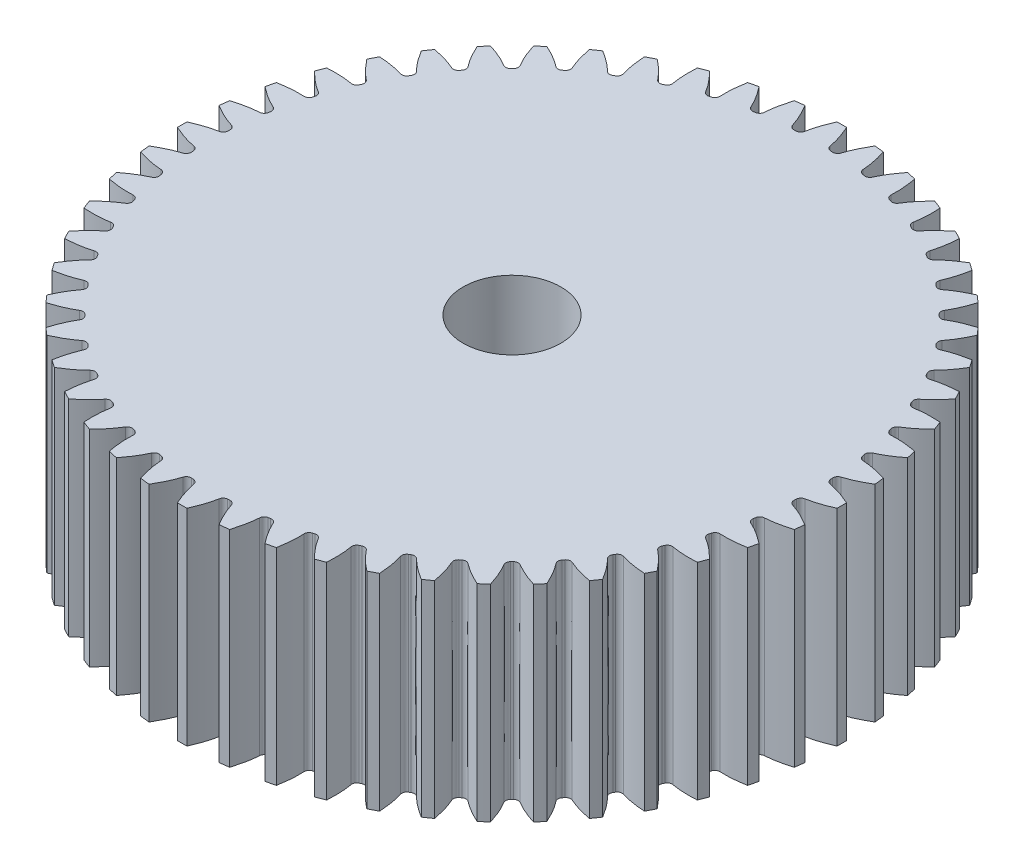
SolidWorks part; units mm, degrees
ref_plane "Front Plane" through (0, 0, 0) normal (0, 0, 1) x (1, 0, 0)
ref_plane "Top Plane" through (0, 0, 0) normal (0, 1, 0) x (1, 0, 0)
ref_plane "Right Plane" through (0, 0, 0) normal (1, 0, 0) x (0, 0, -1)
sketch "Sketch1" plane through (0, 0, 0) normal (0, 1, 0) x (1, 0, 0)
  line L1 (3.0796, 0) -> (1.5398, 2.667)
  line L2 (1.5398, 2.667) -> (-1.5398, 2.667)
  line L3 (-1.5398, 2.667) -> (-3.0796, 0)
  line L4 (-3.0796, 0) -> (-1.5398, -2.667)
  line L5 (-1.5398, -2.667) -> (1.5398, -2.667)
  line L6 (1.5398, -2.667) -> (3.0796, 0)
  circle A0 centre (0, 0) radius 1.2053
  arc A1 (7.4334, -0.4745) -> (7.4364, -0.425) centre (0, 0) ccw
  arc A2 (8.1347, -0.1172) -> (8.1347, 0.1172) centre (0, 0) ccw
  arc A3 (7.4364, 0.425) -> (7.4334, 0.4745) centre (0, 0) ccw
  arc A4 (8.0895, 0.8642) -> (8.0613, 1.0968) centre (0, 0) ccw
  arc A5 (7.331, 1.3182) -> (7.322, 1.367) centre (0, 0) ccw
  arc A6 (7.9264, 1.833) -> (7.8703, 2.0605) centre (0, 0) ccw
  arc A7 (7.1186, 2.1923) -> (7.1039, 2.2396) centre (0, 0) ccw
  arc A8 (7.6476, 2.7751) -> (7.5645, 2.9942) centre (0, 0) ccw
  arc A9 (6.8025, 3.0343) -> (6.7821, 3.0796) centre (0, 0) ccw
  arc A10 (7.2574, 3.6766) -> (7.1485, 3.8841) centre (0, 0) ccw
  arc A11 (6.3871, 3.8322) -> (6.3615, 3.8746) centre (0, 0) ccw
  arc A12 (6.7613, 4.5246) -> (6.6282, 4.7175) centre (0, 0) ccw
  arc A13 (5.8786, 4.5741) -> (5.848, 4.6132) centre (0, 0) ccw
  arc A14 (6.1666, 5.3066) -> (6.0112, 5.482) centre (0, 0) ccw
  arc A15 (5.2844, 5.2494) -> (5.2494, 5.2844) centre (0, 0) ccw
  arc A16 (5.482, 6.0112) -> (5.3066, 6.1666) centre (0, 0) ccw
  arc A17 (4.6132, 5.848) -> (4.5741, 5.8786) centre (0, 0) ccw
  arc A18 (4.7175, 6.6282) -> (4.5246, 6.7613) centre (0, 0) ccw
  arc A19 (3.8746, 6.3615) -> (3.8322, 6.3871) centre (0, 0) ccw
  arc A20 (3.8841, 7.1485) -> (3.6766, 7.2574) centre (0, 0) ccw
  arc A21 (3.0796, 6.7821) -> (3.0343, 6.8025) centre (0, 0) ccw
  arc A22 (2.9942, 7.5645) -> (2.7751, 7.6476) centre (0, 0) ccw
  arc A23 (2.2396, 7.1039) -> (2.1923, 7.1186) centre (0, 0) ccw
  arc A24 (2.0605, 7.8703) -> (1.833, 7.9264) centre (0, 0) ccw
  arc A25 (1.367, 7.322) -> (1.3182, 7.331) centre (0, 0) ccw
  arc A26 (1.0968, 8.0613) -> (0.8642, 8.0895) centre (0, 0) ccw
  arc A27 (0.4745, 7.4334) -> (0.425, 7.4364) centre (0, 0) ccw
  arc A28 (0.1172, 8.1347) -> (-0.1172, 8.1347) centre (0, 0) ccw
  arc A29 (-0.425, 7.4364) -> (-0.4745, 7.4334) centre (0, 0) ccw
  arc A30 (-0.8642, 8.0895) -> (-1.0968, 8.0613) centre (0, 0) ccw
  arc A31 (-1.3182, 7.331) -> (-1.367, 7.322) centre (0, 0) ccw
  arc A32 (-1.833, 7.9264) -> (-2.0605, 7.8703) centre (0, 0) ccw
  arc A33 (-2.1923, 7.1186) -> (-2.2396, 7.1039) centre (0, 0) ccw
  arc A34 (-2.7751, 7.6476) -> (-2.9942, 7.5645) centre (0, 0) ccw
  arc A35 (-3.0343, 6.8025) -> (-3.0796, 6.7821) centre (0, 0) ccw
  arc A36 (-3.6766, 7.2574) -> (-3.8841, 7.1485) centre (0, 0) ccw
  arc A37 (-3.8322, 6.3871) -> (-3.8746, 6.3615) centre (0, 0) ccw
  arc A38 (-4.5246, 6.7613) -> (-4.7175, 6.6282) centre (0, 0) ccw
  arc A39 (-4.5741, 5.8786) -> (-4.6132, 5.848) centre (0, 0) ccw
  arc A40 (-5.3066, 6.1666) -> (-5.482, 6.0112) centre (0, 0) ccw
  arc A41 (-5.2494, 5.2844) -> (-5.2844, 5.2494) centre (0, 0) ccw
  arc A42 (-6.0112, 5.482) -> (-6.1666, 5.3066) centre (0, 0) ccw
  arc A43 (-5.848, 4.6132) -> (-5.8786, 4.5741) centre (0, 0) ccw
  arc A44 (-6.6282, 4.7175) -> (-6.7613, 4.5246) centre (0, 0) ccw
  arc A45 (-6.3615, 3.8746) -> (-6.3871, 3.8322) centre (0, 0) ccw
  arc A46 (-7.1485, 3.8841) -> (-7.2574, 3.6766) centre (0, 0) ccw
  arc A47 (-6.7821, 3.0796) -> (-6.8025, 3.0343) centre (0, 0) ccw
  arc A48 (-7.5645, 2.9942) -> (-7.6476, 2.7751) centre (0, 0) ccw
  arc A49 (-7.1039, 2.2396) -> (-7.1186, 2.1923) centre (0, 0) ccw
  arc A50 (-7.8703, 2.0605) -> (-7.9264, 1.833) centre (0, 0) ccw
  arc A51 (-7.322, 1.367) -> (-7.331, 1.3182) centre (0, 0) ccw
  arc A52 (-8.0613, 1.0968) -> (-8.0895, 0.8642) centre (0, 0) ccw
  arc A53 (-7.4334, 0.4745) -> (-7.4364, 0.425) centre (0, 0) ccw
  arc A54 (-8.1347, 0.1172) -> (-8.1347, -0.1172) centre (0, 0) ccw
  arc A55 (-7.4364, -0.425) -> (-7.4334, -0.4745) centre (0, 0) ccw
  arc A56 (-8.0895, -0.8642) -> (-8.0613, -1.0968) centre (0, 0) ccw
  arc A57 (-7.331, -1.3182) -> (-7.322, -1.367) centre (0, 0) ccw
  arc A58 (-7.9264, -1.833) -> (-7.8703, -2.0605) centre (0, 0) ccw
  arc A59 (-7.1186, -2.1923) -> (-7.1039, -2.2396) centre (0, 0) ccw
  arc A60 (-7.6476, -2.7751) -> (-7.5645, -2.9942) centre (0, 0) ccw
  arc A61 (-6.8025, -3.0343) -> (-6.7821, -3.0796) centre (0, 0) ccw
  arc A62 (-7.2574, -3.6766) -> (-7.1485, -3.8841) centre (0, 0) ccw
  arc A63 (-6.3871, -3.8322) -> (-6.3615, -3.8746) centre (0, 0) ccw
  arc A64 (-6.7613, -4.5246) -> (-6.6282, -4.7175) centre (0, 0) ccw
  arc A65 (-5.8786, -4.5741) -> (-5.848, -4.6132) centre (0, 0) ccw
  arc A66 (-6.1666, -5.3066) -> (-6.0112, -5.482) centre (0, 0) ccw
  arc A67 (-5.2844, -5.2494) -> (-5.2494, -5.2844) centre (0, 0) ccw
  arc A68 (-5.482, -6.0112) -> (-5.3066, -6.1666) centre (0, 0) ccw
  arc A69 (-4.6132, -5.848) -> (-4.5741, -5.8786) centre (0, 0) ccw
  arc A70 (-4.7175, -6.6282) -> (-4.5246, -6.7613) centre (0, 0) ccw
  arc A71 (-3.8746, -6.3615) -> (-3.8322, -6.3871) centre (0, 0) ccw
  arc A72 (-3.8841, -7.1485) -> (-3.6766, -7.2574) centre (0, 0) ccw
  arc A73 (-3.0796, -6.7821) -> (-3.0343, -6.8025) centre (0, 0) ccw
  arc A74 (-2.9942, -7.5645) -> (-2.7751, -7.6476) centre (0, 0) ccw
  arc A75 (-2.2396, -7.1039) -> (-2.1923, -7.1186) centre (0, 0) ccw
  arc A76 (-2.0605, -7.8703) -> (-1.833, -7.9264) centre (0, 0) ccw
  arc A77 (-1.367, -7.322) -> (-1.3182, -7.331) centre (0, 0) ccw
  arc A78 (-1.0968, -8.0613) -> (-0.8642, -8.0895) centre (0, 0) ccw
  arc A79 (-0.4745, -7.4334) -> (-0.425, -7.4364) centre (0, 0) ccw
  arc A80 (-0.1172, -8.1347) -> (0.1172, -8.1347) centre (0, 0) ccw
  arc A81 (0.425, -7.4364) -> (0.4745, -7.4334) centre (0, 0) ccw
  arc A82 (0.8642, -8.0895) -> (1.0968, -8.0613) centre (0, 0) ccw
  arc A83 (1.3182, -7.331) -> (1.367, -7.322) centre (0, 0) ccw
  arc A84 (1.833, -7.9264) -> (2.0605, -7.8703) centre (0, 0) ccw
  arc A85 (2.1923, -7.1186) -> (2.2396, -7.1039) centre (0, 0) ccw
  arc A86 (2.7751, -7.6476) -> (2.9942, -7.5645) centre (0, 0) ccw
  arc A87 (3.0343, -6.8025) -> (3.0796, -6.7821) centre (0, 0) ccw
  arc A88 (3.6766, -7.2574) -> (3.8841, -7.1485) centre (0, 0) ccw
  arc A89 (3.8322, -6.3871) -> (3.8746, -6.3615) centre (0, 0) ccw
  arc A90 (4.5246, -6.7613) -> (4.7175, -6.6282) centre (0, 0) ccw
  arc A91 (4.5741, -5.8786) -> (4.6132, -5.848) centre (0, 0) ccw
  arc A92 (5.3066, -6.1666) -> (5.482, -6.0112) centre (0, 0) ccw
  arc A93 (5.2494, -5.2844) -> (5.2844, -5.2494) centre (0, 0) ccw
  arc A94 (6.0112, -5.482) -> (6.1666, -5.3066) centre (0, 0) ccw
  arc A95 (5.848, -4.6132) -> (5.8786, -4.5741) centre (0, 0) ccw
  arc A96 (6.6282, -4.7175) -> (6.7613, -4.5246) centre (0, 0) ccw
  arc A97 (6.3615, -3.8746) -> (6.3871, -3.8322) centre (0, 0) ccw
  arc A98 (7.1485, -3.8841) -> (7.2574, -3.6766) centre (0, 0) ccw
  arc A99 (6.7821, -3.0796) -> (6.8025, -3.0343) centre (0, 0) ccw
  arc A100 (7.5645, -2.9942) -> (7.6476, -2.7751) centre (0, 0) ccw
  arc A101 (7.1039, -2.2396) -> (7.1186, -2.1923) centre (0, 0) ccw
  arc A102 (7.8703, -2.0605) -> (7.9264, -1.833) centre (0, 0) ccw
  arc A103 (7.322, -1.367) -> (7.331, -1.3182) centre (0, 0) ccw
  arc A104 (8.0613, -1.0968) -> (8.0895, -0.8642) centre (0, 0) ccw
  circle A105 centre (0, 0) radius 2.667 construction
  spline S0 degree 3 poles (7.4364, -0.425) (7.4382, -0.3943) (7.4522, -0.3646) (7.4746, -0.3437) (7.4914, -0.328) (7.5128, -0.3173) (7.5355, -0.3132) knots 0 0 0 0 0.019445 0.019445 0.019445 0.03403 0.03403 0.03403 0.03403 weights 1 1 1 1 1 1 1
  spline S1 degree 5 poles (7.5355, -0.3132) (7.5374, -0.3129) (7.5415, -0.3121) (7.5478, -0.311) (7.5564, -0.3093) (7.5673, -0.3072) (7.5785, -0.3049) (7.5897, -0.3026) (7.6009, -0.3002) (7.6121, -0.2977) (7.6233, -0.2952) (7.6345, -0.2925) (7.6457, -0.2899) (7.6569, -0.2871) (7.6681, -0.2843) (7.6793, -0.2814) (7.6904, -0.2785) (7.7016, -0.2755) (7.7128, -0.2724) (7.724, -0.2693) (7.7352, -0.2661) (7.7463, -0.2629) (7.7575, -0.2596) (7.7687, -0.2563) (7.7798, -0.2528) (7.791, -0.2494) (7.8021, -0.2459) (7.8133, -0.2423) (7.8244, -0.2387) (7.8356, -0.235) (7.8467, -0.2313) (7.8579, -0.2275) (7.869, -0.2237) (7.8801, -0.2198) (7.8912, -0.2158) (7.9024, -0.2119) (7.9135, -0.2078) (7.9246, -0.2037) (7.9357, -0.1996) (7.9468, -0.1954) (7.9579, -0.1912) (7.969, -0.1869) (7.9801, -0.1826) (7.9911, -0.1782) (8.0022, -0.1738) (8.0133, -0.1693) (8.0244, -0.1648) (8.0354, -0.1603) (8.0465, -0.1557) (8.0575, -0.151) (8.0686, -0.1463) (8.0796, -0.1416) (8.0906, -0.1368) (8.1017, -0.1319) (8.1127, -0.1271) (8.1215, -0.1231) (8.1281, -0.1202) (8.1325, -0.1182) (8.1347, -0.1172) knots 0.230945 0.230945 0.230945 0.230945 0.230945 0.230945 0.242857 0.257143 0.271429 0.285714 0.3 0.314286 0.328571 0.342857 0.357143 0.371429 0.385714 0.4 0.414286 0.428571 0.442857 0.457143 0.471429 0.485714 0.5 0.514286 0.528571 0.542857 0.557143 0.571429 0.585714 0.6 0.614286 0.628571 0.642857 0.657143 0.671429 0.685714 0.7 0.714286 0.728571 0.742857 0.757143 0.771429 0.785714 0.8 0.814286 0.828571 0.842857 0.857143 0.871429 0.885714 0.9 0.914286 0.928571 0.942857 0.957143 0.971429 0.985714 1 1 1 1 1 1 weights 1 1 1 1 1 1 1 1 1 1 1 1 1 1 1 1 1 1 1 1 1 1 1 1 1 1 1 1 1 1 1 1 1 1 1 1 1 1 1 1 1 1 1 1 1 1 1 1 1 1 1 1 1 1 1 1 1 1 1
  spline S2 degree 5 poles (8.1347, 0.1172) (8.1325, 0.1182) (8.1281, 0.1202) (8.1215, 0.1231) (8.1127, 0.1271) (8.1017, 0.1319) (8.0906, 0.1368) (8.0796, 0.1416) (8.0686, 0.1463) (8.0575, 0.151) (8.0465, 0.1557) (8.0354, 0.1603) (8.0244, 0.1648) (8.0133, 0.1693) (8.0022, 0.1738) (7.9911, 0.1782) (7.9801, 0.1826) (7.969, 0.1869) (7.9579, 0.1912) (7.9468, 0.1954) (7.9357, 0.1996) (7.9246, 0.2037) (7.9135, 0.2078) (7.9024, 0.2119) (7.8912, 0.2158) (7.8801, 0.2198) (7.869, 0.2237) (7.8579, 0.2275) (7.8467, 0.2313) (7.8356, 0.235) (7.8244, 0.2387) (7.8133, 0.2423) (7.8021, 0.2459) (7.791, 0.2494) (7.7798, 0.2528) (7.7687, 0.2563) (7.7575, 0.2596) (7.7463, 0.2629) (7.7352, 0.2661) (7.724, 0.2693) (7.7128, 0.2724) (7.7016, 0.2755) (7.6904, 0.2785) (7.6793, 0.2814) (7.6681, 0.2843) (7.6569, 0.2871) (7.6457, 0.2899) (7.6345, 0.2925) (7.6233, 0.2952) (7.6121, 0.2977) (7.6009, 0.3002) (7.5897, 0.3026) (7.5785, 0.3049) (7.5673, 0.3072) (7.5564, 0.3093) (7.5478, 0.311) (7.5415, 0.3121) (7.5374, 0.3129) (7.5355, 0.3132) knots -1 -1 -1 -1 -1 -1 -0.985714 -0.971429 -0.957143 -0.942857 -0.928571 -0.914286 -0.9 -0.885714 -0.871429 -0.857143 -0.842857 -0.828571 -0.814286 -0.8 -0.785714 -0.771429 -0.757143 -0.742857 -0.728571 -0.714286 -0.7 -0.685714 -0.671429 -0.657143 -0.642857 -0.628571 -0.614286 -0.6 -0.585714 -0.571429 -0.557143 -0.542857 -0.528571 -0.514286 -0.5 -0.485714 -0.471429 -0.457143 -0.442857 -0.428571 -0.414286 -0.4 -0.385714 -0.371429 -0.357143 -0.342857 -0.328571 -0.314286 -0.3 -0.285714 -0.271429 -0.257143 -0.242857 -0.230945 -0.230945 -0.230945 -0.230945 -0.230945 -0.230945 weights 1 1 1 1 1 1 1 1 1 1 1 1 1 1 1 1 1 1 1 1 1 1 1 1 1 1 1 1 1 1 1 1 1 1 1 1 1 1 1 1 1 1 1 1 1 1 1 1 1 1 1 1 1 1 1 1 1 1 1
  spline S3 degree 3 poles (7.5355, 0.3132) (7.5128, 0.3173) (7.4914, 0.328) (7.4746, 0.3437) (7.4522, 0.3646) (7.4382, 0.3943) (7.4364, 0.425) knots 0 0 0 0 0.014584 0.014584 0.014584 0.03403 0.03403 0.03403 0.03403 weights 1 1 1 1 1 1 1
  spline S4 degree 3 poles (7.4334, 0.4745) (7.4315, 0.5051) (7.4418, 0.5363) (7.4615, 0.5598) (7.4763, 0.5774) (7.4963, 0.5906) (7.5183, 0.5974) knots 0 0 0 0 0.019445 0.019445 0.019445 0.03403 0.03403 0.03403 0.03403 weights 1 1 1 1 1 1 1
  spline S5 degree 5 poles (7.5183, 0.5974) (7.5201, 0.5979) (7.5241, 0.5992) (7.5303, 0.6011) (7.5386, 0.6037) (7.5491, 0.6072) (7.56, 0.6108) (7.5708, 0.6144) (7.5816, 0.6182) (7.5925, 0.622) (7.6033, 0.6259) (7.6141, 0.6298) (7.6249, 0.6338) (7.6357, 0.6379) (7.6464, 0.6421) (7.6572, 0.6463) (7.6679, 0.6505) (7.6787, 0.6549) (7.6894, 0.6592) (7.7001, 0.6637) (7.7108, 0.6682) (7.7215, 0.6727) (7.7322, 0.6774) (7.7429, 0.682) (7.7536, 0.6868) (7.7642, 0.6915) (7.7749, 0.6964) (7.7855, 0.7013) (7.7962, 0.7062) (7.8068, 0.7112) (7.8174, 0.7162) (7.828, 0.7213) (7.8386, 0.7265) (7.8492, 0.7317) (7.8597, 0.7369) (7.8703, 0.7422) (7.8808, 0.7476) (7.8914, 0.7529) (7.9019, 0.7584) (7.9124, 0.7639) (7.9229, 0.7694) (7.9334, 0.775) (7.9439, 0.7806) (7.9544, 0.7863) (7.9648, 0.792) (7.9753, 0.7978) (7.9857, 0.8036) (7.9961, 0.8095) (8.0066, 0.8154) (8.017, 0.8213) (8.0274, 0.8273) (8.0378, 0.8334) (8.0481, 0.8394) (8.0585, 0.8456) (8.0689, 0.8517) (8.0771, 0.8567) (8.0833, 0.8605) (8.0875, 0.863) (8.0895, 0.8642) knots 0.230945 0.230945 0.230945 0.230945 0.230945 0.230945 0.242857 0.257143 0.271429 0.285714 0.3 0.314286 0.328571 0.342857 0.357143 0.371429 0.385714 0.4 0.414286 0.428571 0.442857 0.457143 0.471429 0.485714 0.5 0.514286 0.528571 0.542857 0.557143 0.571429 0.585714 0.6 0.614286 0.628571 0.642857 0.657143 0.671429 0.685714 0.7 0.714286 0.728571 0.742857 0.757143 0.771429 0.785714 0.8 0.814286 0.828571 0.842857 0.857143 0.871429 0.885714 0.9 0.914286 0.928571 0.942857 0.957143 0.971429 0.985714 1 1 1 1 1 1 weights 1 1 1 1 1 1 1 1 1 1 1 1 1 1 1 1 1 1 1 1 1 1 1 1 1 1 1 1 1 1 1 1 1 1 1 1 1 1 1 1 1 1 1 1 1 1 1 1 1 1 1 1 1 1 1 1 1 1 1
  spline S6 degree 5 poles (8.0613, 1.0968) (8.059, 1.0976) (8.0544, 1.099) (8.0474, 1.1012) (8.0382, 1.104) (8.0267, 1.1075) (8.0152, 1.111) (8.0036, 1.1144) (7.9921, 1.1178) (7.9806, 1.1211) (7.969, 1.1244) (7.9575, 1.1277) (7.946, 1.1308) (7.9345, 1.134) (7.9229, 1.1371) (7.9114, 1.1401) (7.8999, 1.1432) (7.8883, 1.1461) (7.8768, 1.149) (7.8653, 1.1519) (7.8538, 1.1547) (7.8422, 1.1575) (7.8307, 1.1602) (7.8192, 1.1628) (7.8077, 1.1655) (7.7962, 1.168) (7.7847, 1.1705) (7.7731, 1.173) (7.7616, 1.1754) (7.7501, 1.1778) (7.7386, 1.1801) (7.7271, 1.1823) (7.7156, 1.1845) (7.7041, 1.1867) (7.6926, 1.1888) (7.6811, 1.1908) (7.6696, 1.1928) (7.6582, 1.1947) (7.6467, 1.1966) (7.6352, 1.1984) (7.6237, 1.2001) (7.6123, 1.2018) (7.6008, 1.2034) (7.5893, 1.205) (7.5779, 1.2065) (7.5664, 1.2079) (7.555, 1.2093) (7.5436, 1.2106) (7.5321, 1.2119) (7.5207, 1.2131) (7.5093, 1.2142) (7.4979, 1.2152) (7.4865, 1.2162) (7.4751, 1.2171) (7.464, 1.2179) (7.4553, 1.2185) (7.4489, 1.2189) (7.4447, 1.2191) (7.4428, 1.2192) knots -1 -1 -1 -1 -1 -1 -0.985714 -0.971429 -0.957143 -0.942857 -0.928571 -0.914286 -0.9 -0.885714 -0.871429 -0.857143 -0.842857 -0.828571 -0.814286 -0.8 -0.785714 -0.771429 -0.757143 -0.742857 -0.728571 -0.714286 -0.7 -0.685714 -0.671429 -0.657143 -0.642857 -0.628571 -0.614286 -0.6 -0.585714 -0.571429 -0.557143 -0.542857 -0.528571 -0.514286 -0.5 -0.485714 -0.471429 -0.457143 -0.442857 -0.428571 -0.414286 -0.4 -0.385714 -0.371429 -0.357143 -0.342857 -0.328571 -0.314286 -0.3 -0.285714 -0.271429 -0.257143 -0.242857 -0.230945 -0.230945 -0.230945 -0.230945 -0.230945 -0.230945 weights 1 1 1 1 1 1 1 1 1 1 1 1 1 1 1 1 1 1 1 1 1 1 1 1 1 1 1 1 1 1 1 1 1 1 1 1 1 1 1 1 1 1 1 1 1 1 1 1 1 1 1 1 1 1 1 1 1 1 1
  spline S7 degree 3 poles (7.4428, 1.2192) (7.4198, 1.2205) (7.3972, 1.2286) (7.3787, 1.2421) (7.3539, 1.2602) (7.3364, 1.288) (7.331, 1.3182) knots 0 0 0 0 0.014584 0.014584 0.014584 0.03403 0.03403 0.03403 0.03403 weights 1 1 1 1 1 1 1
  spline S8 degree 3 poles (7.322, 1.367) (7.3164, 1.3972) (7.3229, 1.4294) (7.3396, 1.4551) (7.3522, 1.4744) (7.3705, 1.4899) (7.3915, 1.4993) knots 0 0 0 0 0.019445 0.019445 0.019445 0.03403 0.03403 0.03403 0.03403 weights 1 1 1 1 1 1 1
  spline S9 degree 5 poles (7.3915, 1.4993) (7.3932, 1.5) (7.397, 1.5017) (7.4029, 1.5044) (7.4109, 1.508) (7.4209, 1.5127) (7.4312, 1.5176) (7.4416, 1.5225) (7.4519, 1.5275) (7.4621, 1.5326) (7.4724, 1.5378) (7.4826, 1.543) (7.4929, 1.5483) (7.5031, 1.5536) (7.5133, 1.5591) (7.5235, 1.5645) (7.5336, 1.5701) (7.5438, 1.5756) (7.5539, 1.5813) (7.564, 1.587) (7.5741, 1.5928) (7.5842, 1.5986) (7.5942, 1.6044) (7.6042, 1.6104) (7.6143, 1.6163) (7.6243, 1.6224) (7.6343, 1.6284) (7.6442, 1.6346) (7.6542, 1.6408) (7.6641, 1.647) (7.6741, 1.6533) (7.684, 1.6596) (7.6939, 1.666) (7.7037, 1.6724) (7.7136, 1.6789) (7.7234, 1.6855) (7.7333, 1.692) (7.7431, 1.6987) (7.7529, 1.7053) (7.7626, 1.712) (7.7724, 1.7188) (7.7821, 1.7256) (7.7919, 1.7325) (7.8016, 1.7394) (7.8113, 1.7463) (7.821, 1.7533) (7.8306, 1.7603) (7.8403, 1.7674) (7.8499, 1.7745) (7.8595, 1.7817) (7.8691, 1.7889) (7.8787, 1.7961) (7.8883, 1.8034) (7.8978, 1.8107) (7.9074, 1.8181) (7.915, 1.824) (7.9207, 1.8285) (7.9245, 1.8315) (7.9264, 1.833) knots 0.230945 0.230945 0.230945 0.230945 0.230945 0.230945 0.242857 0.257143 0.271429 0.285714 0.3 0.314286 0.328571 0.342857 0.357143 0.371429 0.385714 0.4 0.414286 0.428571 0.442857 0.457143 0.471429 0.485714 0.5 0.514286 0.528571 0.542857 0.557143 0.571429 0.585714 0.6 0.614286 0.628571 0.642857 0.657143 0.671429 0.685714 0.7 0.714286 0.728571 0.742857 0.757143 0.771429 0.785714 0.8 0.814286 0.828571 0.842857 0.857143 0.871429 0.885714 0.9 0.914286 0.928571 0.942857 0.957143 0.971429 0.985714 1 1 1 1 1 1 weights 1 1 1 1 1 1 1 1 1 1 1 1 1 1 1 1 1 1 1 1 1 1 1 1 1 1 1 1 1 1 1 1 1 1 1 1 1 1 1 1 1 1 1 1 1 1 1 1 1 1 1 1 1 1 1 1 1 1 1
  spline S10 degree 5 poles (7.8703, 2.0605) (7.8679, 2.061) (7.8632, 2.0619) (7.856, 2.0632) (7.8465, 2.0649) (7.8347, 2.067) (7.8228, 2.069) (7.8109, 2.071) (7.7991, 2.073) (7.7872, 2.0749) (7.7754, 2.0768) (7.7636, 2.0786) (7.7517, 2.0804) (7.7399, 2.0821) (7.7281, 2.0838) (7.7163, 2.0854) (7.7045, 2.087) (7.6927, 2.0886) (7.6809, 2.0901) (7.6691, 2.0915) (7.6573, 2.0929) (7.6455, 2.0943) (7.6338, 2.0956) (7.622, 2.0969) (7.6103, 2.0981) (7.5985, 2.0992) (7.5868, 2.1003) (7.5751, 2.1014) (7.5634, 2.1024) (7.5517, 2.1034) (7.54, 2.1043) (7.5283, 2.1051) (7.5166, 2.1059) (7.5049, 2.1066) (7.4932, 2.1073) (7.4816, 2.108) (7.47, 2.1085) (7.4583, 2.1091) (7.4467, 2.1095) (7.4351, 2.1099) (7.4235, 2.1103) (7.4119, 2.1106) (7.4003, 2.1108) (7.3888, 2.111) (7.3772, 2.1111) (7.3657, 2.1112) (7.3541, 2.1112) (7.3426, 2.1111) (7.3311, 2.1109) (7.3196, 2.1107) (7.3082, 2.1105) (7.2967, 2.1101) (7.2853, 2.1097) (7.2739, 2.1092) (7.2628, 2.1087) (7.2541, 2.1082) (7.2476, 2.1079) (7.2435, 2.1076) (7.2416, 2.1075) knots -1 -1 -1 -1 -1 -1 -0.985714 -0.971429 -0.957143 -0.942857 -0.928571 -0.914286 -0.9 -0.885714 -0.871429 -0.857143 -0.842857 -0.828571 -0.814286 -0.8 -0.785714 -0.771429 -0.757143 -0.742857 -0.728571 -0.714286 -0.7 -0.685714 -0.671429 -0.657143 -0.642857 -0.628571 -0.614286 -0.6 -0.585714 -0.571429 -0.557143 -0.542857 -0.528571 -0.514286 -0.5 -0.485714 -0.471429 -0.457143 -0.442857 -0.428571 -0.414286 -0.4 -0.385714 -0.371429 -0.357143 -0.342857 -0.328571 -0.314286 -0.3 -0.285714 -0.271429 -0.257143 -0.242857 -0.230945 -0.230945 -0.230945 -0.230945 -0.230945 -0.230945 weights 1 1 1 1 1 1 1 1 1 1 1 1 1 1 1 1 1 1 1 1 1 1 1 1 1 1 1 1 1 1 1 1 1 1 1 1 1 1 1 1 1 1 1 1 1 1 1 1 1 1 1 1 1 1 1 1 1 1 1
  spline S11 degree 3 poles (7.2416, 2.1075) (7.2186, 2.106) (7.1952, 2.1112) (7.1751, 2.1225) (7.1484, 2.1374) (7.1277, 2.163) (7.1186, 2.1923) knots 0 0 0 0 0.014584 0.014584 0.014584 0.03403 0.03403 0.03403 0.03403 weights 1 1 1 1 1 1 1
  spline S12 degree 3 poles (7.1039, 2.2396) (7.0946, 2.2689) (7.0972, 2.3017) (7.1107, 2.3292) (7.1208, 2.3498) (7.1371, 2.3674) (7.1569, 2.3793) knots 0 0 0 0 0.019445 0.019445 0.019445 0.03403 0.03403 0.03403 0.03403 weights 1 1 1 1 1 1 1
  spline S13 degree 5 poles (7.1569, 2.3793) (7.1585, 2.3802) (7.1621, 2.3824) (7.1676, 2.3857) (7.1751, 2.3903) (7.1845, 2.3961) (7.1941, 2.4022) (7.2038, 2.4084) (7.2134, 2.4146) (7.223, 2.4209) (7.2326, 2.4273) (7.2421, 2.4337) (7.2516, 2.4402) (7.2611, 2.4467) (7.2706, 2.4533) (7.28, 2.46) (7.2894, 2.4667) (7.2988, 2.4735) (7.3082, 2.4803) (7.3175, 2.4872) (7.3269, 2.4941) (7.3362, 2.5011) (7.3454, 2.5081) (7.3547, 2.5152) (7.3639, 2.5223) (7.3731, 2.5295) (7.3823, 2.5368) (7.3915, 2.5441) (7.4006, 2.5514) (7.4097, 2.5588) (7.4188, 2.5662) (7.4279, 2.5737) (7.4369, 2.5813) (7.446, 2.5888) (7.455, 2.5965) (7.464, 2.6041) (7.4729, 2.6118) (7.4819, 2.6196) (7.4908, 2.6274) (7.4997, 2.6352) (7.5085, 2.6431) (7.5174, 2.6511) (7.5262, 2.659) (7.535, 2.6671) (7.5438, 2.6751) (7.5526, 2.6832) (7.5613, 2.6914) (7.5701, 2.6996) (7.5788, 2.7078) (7.5875, 2.716) (7.5961, 2.7244) (7.6048, 2.7327) (7.6134, 2.7411) (7.622, 2.7495) (7.6306, 2.758) (7.6374, 2.7648) (7.6425, 2.7699) (7.6459, 2.7733) (7.6476, 2.7751) knots 0.230945 0.230945 0.230945 0.230945 0.230945 0.230945 0.242857 0.257143 0.271429 0.285714 0.3 0.314286 0.328571 0.342857 0.357143 0.371429 0.385714 0.4 0.414286 0.428571 0.442857 0.457143 0.471429 0.485714 0.5 0.514286 0.528571 0.542857 0.557143 0.571429 0.585714 0.6 0.614286 0.628571 0.642857 0.657143 0.671429 0.685714 0.7 0.714286 0.728571 0.742857 0.757143 0.771429 0.785714 0.8 0.814286 0.828571 0.842857 0.857143 0.871429 0.885714 0.9 0.914286 0.928571 0.942857 0.957143 0.971429 0.985714 1 1 1 1 1 1 weights 1 1 1 1 1 1 1 1 1 1 1 1 1 1 1 1 1 1 1 1 1 1 1 1 1 1 1 1 1 1 1 1 1 1 1 1 1 1 1 1 1 1 1 1 1 1 1 1 1 1 1 1 1 1 1 1 1 1 1
  spline S14 degree 5 poles (7.5645, 2.9942) (7.5621, 2.9943) (7.5573, 2.9946) (7.5501, 2.9951) (7.5404, 2.9956) (7.5284, 2.9963) (7.5164, 2.9969) (7.5044, 2.9974) (7.4924, 2.9979) (7.4804, 2.9984) (7.4684, 2.9989) (7.4564, 2.9992) (7.4445, 2.9996) (7.4325, 2.9999) (7.4206, 3.0001) (7.4086, 3.0003) (7.3967, 3.0005) (7.3848, 3.0006) (7.3729, 3.0007) (7.3611, 3.0007) (7.3492, 3.0007) (7.3374, 3.0006) (7.3255, 3.0005) (7.3137, 3.0003) (7.3019, 3.0001) (7.2901, 2.9998) (7.2783, 2.9995) (7.2666, 2.9991) (7.2548, 2.9987) (7.2431, 2.9983) (7.2313, 2.9978) (7.2196, 2.9972) (7.2079, 2.9966) (7.1963, 2.9959) (7.1846, 2.9952) (7.173, 2.9944) (7.1613, 2.9936) (7.1497, 2.9927) (7.1381, 2.9918) (7.1266, 2.9908) (7.115, 2.9897) (7.1035, 2.9886) (7.0919, 2.9874) (7.0804, 2.9862) (7.069, 2.985) (7.0575, 2.9836) (7.0461, 2.9822) (7.0346, 2.9808) (7.0232, 2.9792) (7.0119, 2.9776) (7.0005, 2.976) (6.9892, 2.9743) (6.9779, 2.9725) (6.9666, 2.9706) (6.9557, 2.9688) (6.9471, 2.9673) (6.9407, 2.9661) (6.9366, 2.9653) (6.9347, 2.965) knots -1 -1 -1 -1 -1 -1 -0.985714 -0.971429 -0.957143 -0.942857 -0.928571 -0.914286 -0.9 -0.885714 -0.871429 -0.857143 -0.842857 -0.828571 -0.814286 -0.8 -0.785714 -0.771429 -0.757143 -0.742857 -0.728571 -0.714286 -0.7 -0.685714 -0.671429 -0.657143 -0.642857 -0.628571 -0.614286 -0.6 -0.585714 -0.571429 -0.557143 -0.542857 -0.528571 -0.514286 -0.5 -0.485714 -0.471429 -0.457143 -0.442857 -0.428571 -0.414286 -0.4 -0.385714 -0.371429 -0.357143 -0.342857 -0.328571 -0.314286 -0.3 -0.285714 -0.271429 -0.257143 -0.242857 -0.230945 -0.230945 -0.230945 -0.230945 -0.230945 -0.230945 weights 1 1 1 1 1 1 1 1 1 1 1 1 1 1 1 1 1 1 1 1 1 1 1 1 1 1 1 1 1 1 1 1 1 1 1 1 1 1 1 1 1 1 1 1 1 1 1 1 1 1 1 1 1 1 1 1 1 1 1
  spline S15 degree 3 poles (6.9347, 2.965) (6.9121, 2.9607) (6.8882, 2.9631) (6.867, 2.9719) (6.8386, 2.9835) (6.815, 3.0063) (6.8025, 3.0343) knots 0 0 0 0 0.014584 0.014584 0.014584 0.03403 0.03403 0.03403 0.03403 weights 1 1 1 1 1 1 1
  spline S16 degree 3 poles (6.7821, 3.0796) (6.7694, 3.1075) (6.768, 3.1404) (6.7781, 3.1693) (6.7857, 3.191) (6.7997, 3.2105) (6.8179, 3.2246) knots 0 0 0 0 0.019445 0.019445 0.019445 0.03403 0.03403 0.03403 0.03403 weights 1 1 1 1 1 1 1
  spline S17 degree 5 poles (6.8179, 3.2246) (6.8194, 3.2258) (6.8227, 3.2283) (6.8278, 3.2323) (6.8346, 3.2377) (6.8432, 3.2447) (6.8521, 3.2519) (6.8609, 3.2592) (6.8697, 3.2665) (6.8785, 3.2739) (6.8872, 3.2814) (6.8959, 3.2889) (6.9046, 3.2965) (6.9132, 3.3041) (6.9219, 3.3118) (6.9304, 3.3195) (6.939, 3.3273) (6.9475, 3.3352) (6.956, 3.3431) (6.9644, 3.3511) (6.9728, 3.3591) (6.9812, 3.3671) (6.9896, 3.3752) (6.9979, 3.3834) (7.0062, 3.3916) (7.0145, 3.3998) (7.0227, 3.4081) (7.0309, 3.4165) (7.0391, 3.4249) (7.0473, 3.4333) (7.0554, 3.4418) (7.0635, 3.4503) (7.0716, 3.4589) (7.0796, 3.4675) (7.0877, 3.4761) (7.0956, 3.4848) (7.1036, 3.4936) (7.1116, 3.5023) (7.1195, 3.5112) (7.1274, 3.52) (7.1352, 3.5289) (7.143, 3.5379) (7.1508, 3.5468) (7.1586, 3.5559) (7.1664, 3.5649) (7.1741, 3.574) (7.1818, 3.5832) (7.1895, 3.5923) (7.1971, 3.6016) (7.2048, 3.6108) (7.2124, 3.6201) (7.2199, 3.6294) (7.2275, 3.6388) (7.235, 3.6482) (7.2425, 3.6576) (7.2485, 3.6652) (7.2529, 3.6709) (7.2559, 3.6747) (7.2574, 3.6766) knots 0.230945 0.230945 0.230945 0.230945 0.230945 0.230945 0.242857 0.257143 0.271429 0.285714 0.3 0.314286 0.328571 0.342857 0.357143 0.371429 0.385714 0.4 0.414286 0.428571 0.442857 0.457143 0.471429 0.485714 0.5 0.514286 0.528571 0.542857 0.557143 0.571429 0.585714 0.6 0.614286 0.628571 0.642857 0.657143 0.671429 0.685714 0.7 0.714286 0.728571 0.742857 0.757143 0.771429 0.785714 0.8 0.814286 0.828571 0.842857 0.857143 0.871429 0.885714 0.9 0.914286 0.928571 0.942857 0.957143 0.971429 0.985714 1 1 1 1 1 1 weights 1 1 1 1 1 1 1 1 1 1 1 1 1 1 1 1 1 1 1 1 1 1 1 1 1 1 1 1 1 1 1 1 1 1 1 1 1 1 1 1 1 1 1 1 1 1 1 1 1 1 1 1 1 1 1 1 1 1 1
  spline S18 degree 5 poles (7.1485, 3.8841) (7.1461, 3.884) (7.1412, 3.8837) (7.134, 3.8833) (7.1244, 3.8827) (7.1124, 3.8819) (7.1003, 3.881) (7.0883, 3.8801) (7.0764, 3.8792) (7.0644, 3.8782) (7.0525, 3.8772) (7.0405, 3.8761) (7.0286, 3.875) (7.0167, 3.8739) (7.0048, 3.8727) (6.993, 3.8715) (6.9811, 3.8702) (6.9693, 3.8689) (6.9575, 3.8675) (6.9457, 3.8661) (6.9339, 3.8646) (6.9222, 3.8631) (6.9104, 3.8616) (6.8987, 3.86) (6.887, 3.8584) (6.8754, 3.8567) (6.8637, 3.8549) (6.8521, 3.8532) (6.8404, 3.8513) (6.8289, 3.8495) (6.8173, 3.8475) (6.8057, 3.8456) (6.7942, 3.8435) (6.7827, 3.8415) (6.7712, 3.8393) (6.7597, 3.8372) (6.7483, 3.835) (6.7369, 3.8327) (6.7255, 3.8304) (6.7141, 3.828) (6.7028, 3.8255) (6.6914, 3.823) (6.6801, 3.8205) (6.6689, 3.8179) (6.6576, 3.8153) (6.6464, 3.8125) (6.6352, 3.8098) (6.6241, 3.807) (6.6129, 3.8041) (6.6018, 3.8011) (6.5907, 3.7981) (6.5797, 3.795) (6.5687, 3.7919) (6.5577, 3.7887) (6.5471, 3.7855) (6.5388, 3.783) (6.5326, 3.7811) (6.5286, 3.7798) (6.5268, 3.7793) knots -1 -1 -1 -1 -1 -1 -0.985714 -0.971429 -0.957143 -0.942857 -0.928571 -0.914286 -0.9 -0.885714 -0.871429 -0.857143 -0.842857 -0.828571 -0.814286 -0.8 -0.785714 -0.771429 -0.757143 -0.742857 -0.728571 -0.714286 -0.7 -0.685714 -0.671429 -0.657143 -0.642857 -0.628571 -0.614286 -0.6 -0.585714 -0.571429 -0.557143 -0.542857 -0.528571 -0.514286 -0.5 -0.485714 -0.471429 -0.457143 -0.442857 -0.428571 -0.414286 -0.4 -0.385714 -0.371429 -0.357143 -0.342857 -0.328571 -0.314286 -0.3 -0.285714 -0.271429 -0.257143 -0.242857 -0.230945 -0.230945 -0.230945 -0.230945 -0.230945 -0.230945 weights 1 1 1 1 1 1 1 1 1 1 1 1 1 1 1 1 1 1 1 1 1 1 1 1 1 1 1 1 1 1 1 1 1 1 1 1 1 1 1 1 1 1 1 1 1 1 1 1 1 1 1 1 1 1 1 1 1 1 1
  spline S19 degree 3 poles (6.5268, 3.7793) (6.5049, 3.7723) (6.4809, 3.7718) (6.4587, 3.7779) (6.4292, 3.786) (6.4029, 3.8059) (6.3871, 3.8322) knots 0 0 0 0 0.014584 0.014584 0.014584 0.03403 0.03403 0.03403 0.03403 weights 1 1 1 1 1 1 1
  spline S20 degree 3 poles (6.3615, 3.8746) (6.3455, 3.9008) (6.3401, 3.9333) (6.3467, 3.9632) (6.3516, 3.9857) (6.3632, 4.0067) (6.3795, 4.0229) knots 0 0 0 0 0.019445 0.019445 0.019445 0.03403 0.03403 0.03403 0.03403 weights 1 1 1 1 1 1 1
  spline S21 degree 5 poles (6.3795, 4.0229) (6.3809, 4.0242) (6.3838, 4.0272) (6.3884, 4.0317) (6.3945, 4.038) (6.4023, 4.0459) (6.4102, 4.0541) (6.4181, 4.0624) (6.4259, 4.0707) (6.4337, 4.0792) (6.4415, 4.0876) (6.4492, 4.0961) (6.4569, 4.1047) (6.4646, 4.1133) (6.4722, 4.122) (6.4798, 4.1307) (6.4873, 4.1395) (6.4948, 4.1483) (6.5023, 4.1572) (6.5097, 4.1661) (6.5171, 4.1751) (6.5244, 4.1841) (6.5318, 4.1931) (6.5391, 4.2022) (6.5463, 4.2114) (6.5535, 4.2205) (6.5607, 4.2298) (6.5679, 4.239) (6.575, 4.2484) (6.5821, 4.2577) (6.5891, 4.2671) (6.5961, 4.2765) (6.6031, 4.286) (6.6101, 4.2955) (6.617, 4.3051) (6.6239, 4.3147) (6.6307, 4.3243) (6.6375, 4.334) (6.6443, 4.3437) (6.6511, 4.3535) (6.6578, 4.3632) (6.6645, 4.3731) (6.6712, 4.3829) (6.6778, 4.3928) (6.6844, 4.4027) (6.691, 4.4127) (6.6975, 4.4227) (6.7041, 4.4327) (6.7105, 4.4428) (6.717, 4.4529) (6.7234, 4.4631) (6.7298, 4.4732) (6.7362, 4.4834) (6.7425, 4.4937) (6.7488, 4.504) (6.7538, 4.5122) (6.7576, 4.5184) (6.7601, 4.5225) (6.7613, 4.5246) knots 0.230945 0.230945 0.230945 0.230945 0.230945 0.230945 0.242857 0.257143 0.271429 0.285714 0.3 0.314286 0.328571 0.342857 0.357143 0.371429 0.385714 0.4 0.414286 0.428571 0.442857 0.457143 0.471429 0.485714 0.5 0.514286 0.528571 0.542857 0.557143 0.571429 0.585714 0.6 0.614286 0.628571 0.642857 0.657143 0.671429 0.685714 0.7 0.714286 0.728571 0.742857 0.757143 0.771429 0.785714 0.8 0.814286 0.828571 0.842857 0.857143 0.871429 0.885714 0.9 0.914286 0.928571 0.942857 0.957143 0.971429 0.985714 1 1 1 1 1 1 weights 1 1 1 1 1 1 1 1 1 1 1 1 1 1 1 1 1 1 1 1 1 1 1 1 1 1 1 1 1 1 1 1 1 1 1 1 1 1 1 1 1 1 1 1 1 1 1 1 1 1 1 1 1 1 1 1 1 1 1
  spline S22 degree 5 poles (6.6282, 4.7175) (6.6258, 4.717) (6.621, 4.7162) (6.6139, 4.7149) (6.6044, 4.7131) (6.5926, 4.7109) (6.5808, 4.7086) (6.569, 4.7062) (6.5572, 4.7039) (6.5454, 4.7015) (6.5337, 4.699) (6.522, 4.6965) (6.5103, 4.694) (6.4986, 4.6914) (6.487, 4.6888) (6.4753, 4.6862) (6.4637, 4.6835) (6.4522, 4.6807) (6.4406, 4.6779) (6.4291, 4.6751) (6.4175, 4.6723) (6.4061, 4.6694) (6.3946, 4.6664) (6.3832, 4.6634) (6.3717, 4.6604) (6.3604, 4.6573) (6.349, 4.6542) (6.3377, 4.651) (6.3263, 4.6478) (6.3151, 4.6445) (6.3038, 4.6412) (6.2926, 4.6379) (6.2814, 4.6345) (6.2702, 4.631) (6.259, 4.6275) (6.2479, 4.624) (6.2368, 4.6204) (6.2258, 4.6168) (6.2147, 4.6131) (6.2037, 4.6094) (6.1928, 4.6056) (6.1818, 4.6017) (6.1709, 4.5979) (6.16, 4.5939) (6.1492, 4.5899) (6.1384, 4.5859) (6.1276, 4.5818) (6.1169, 4.5776) (6.1062, 4.5734) (6.0955, 4.5692) (6.0849, 4.5648) (6.0743, 4.5605) (6.0637, 4.556) (6.0532, 4.5515) (6.0431, 4.5471) (6.0351, 4.5436) (6.0292, 4.5409) (6.0254, 4.5392) (6.0237, 4.5384) knots -1 -1 -1 -1 -1 -1 -0.985714 -0.971429 -0.957143 -0.942857 -0.928571 -0.914286 -0.9 -0.885714 -0.871429 -0.857143 -0.842857 -0.828571 -0.814286 -0.8 -0.785714 -0.771429 -0.757143 -0.742857 -0.728571 -0.714286 -0.7 -0.685714 -0.671429 -0.657143 -0.642857 -0.628571 -0.614286 -0.6 -0.585714 -0.571429 -0.557143 -0.542857 -0.528571 -0.514286 -0.5 -0.485714 -0.471429 -0.457143 -0.442857 -0.428571 -0.414286 -0.4 -0.385714 -0.371429 -0.357143 -0.342857 -0.328571 -0.314286 -0.3 -0.285714 -0.271429 -0.257143 -0.242857 -0.230945 -0.230945 -0.230945 -0.230945 -0.230945 -0.230945 weights 1 1 1 1 1 1 1 1 1 1 1 1 1 1 1 1 1 1 1 1 1 1 1 1 1 1 1 1 1 1 1 1 1 1 1 1 1 1 1 1 1 1 1 1 1 1 1 1 1 1 1 1 1 1 1 1 1 1 1
  spline S23 degree 3 poles (6.0237, 4.5384) (6.0027, 4.5289) (5.979, 4.5255) (5.9562, 4.5289) (5.9259, 4.5334) (5.8975, 4.5499) (5.8786, 4.5741) knots 0 0 0 0 0.014584 0.014584 0.014584 0.03403 0.03403 0.03403 0.03403 weights 1 1 1 1 1 1 1
  spline S24 degree 3 poles (5.848, 4.6132) (5.829, 4.6373) (5.8198, 4.6688) (5.8227, 4.6993) (5.8249, 4.7222) (5.8338, 4.7445) (5.8481, 4.7625) knots 0 0 0 0 0.019445 0.019445 0.019445 0.03403 0.03403 0.03403 0.03403 weights 1 1 1 1 1 1 1
  spline S25 degree 5 poles (5.8481, 4.7625) (5.8493, 4.764) (5.8519, 4.7673) (5.8558, 4.7724) (5.8612, 4.7793) (5.8679, 4.7881) (5.8748, 4.7972) (5.8816, 4.8064) (5.8884, 4.8156) (5.8951, 4.8249) (5.9018, 4.8342) (5.9085, 4.8436) (5.9151, 4.8531) (5.9216, 4.8625) (5.9282, 4.8721) (5.9346, 4.8816) (5.941, 4.8913) (5.9474, 4.9009) (5.9538, 4.9106) (5.9601, 4.9204) (5.9663, 4.9302) (5.9725, 4.94) (5.9787, 4.9499) (5.9849, 4.9598) (5.991, 4.9697) (5.997, 4.9797) (6.003, 4.9897) (6.009, 4.9998) (6.0149, 5.0099) (6.0209, 5.02) (6.0267, 5.0302) (6.0325, 5.0404) (6.0383, 5.0507) (6.0441, 5.061) (6.0498, 5.0713) (6.0555, 5.0817) (6.0611, 5.092) (6.0667, 5.1025) (6.0723, 5.1129) (6.0778, 5.1234) (6.0833, 5.1339) (6.0888, 5.1445) (6.0942, 5.1551) (6.0996, 5.1657) (6.105, 5.1764) (6.1103, 5.187) (6.1156, 5.1978) (6.1209, 5.2085) (6.1261, 5.2193) (6.1313, 5.2301) (6.1364, 5.2409) (6.1415, 5.2518) (6.1466, 5.2627) (6.1517, 5.2736) (6.1567, 5.2846) (6.1607, 5.2934) (6.1637, 5.3) (6.1656, 5.3044) (6.1666, 5.3066) knots 0.230945 0.230945 0.230945 0.230945 0.230945 0.230945 0.242857 0.257143 0.271429 0.285714 0.3 0.314286 0.328571 0.342857 0.357143 0.371429 0.385714 0.4 0.414286 0.428571 0.442857 0.457143 0.471429 0.485714 0.5 0.514286 0.528571 0.542857 0.557143 0.571429 0.585714 0.6 0.614286 0.628571 0.642857 0.657143 0.671429 0.685714 0.7 0.714286 0.728571 0.742857 0.757143 0.771429 0.785714 0.8 0.814286 0.828571 0.842857 0.857143 0.871429 0.885714 0.9 0.914286 0.928571 0.942857 0.957143 0.971429 0.985714 1 1 1 1 1 1 weights 1 1 1 1 1 1 1 1 1 1 1 1 1 1 1 1 1 1 1 1 1 1 1 1 1 1 1 1 1 1 1 1 1 1 1 1 1 1 1 1 1 1 1 1 1 1 1 1 1 1 1 1 1 1 1 1 1 1 1
  spline S26 degree 5 poles (6.0112, 5.482) (6.0089, 5.4813) (6.0043, 5.4799) (5.9974, 5.4777) (5.9882, 5.4748) (5.9767, 5.4712) (5.9652, 5.4675) (5.9538, 5.4637) (5.9424, 5.46) (5.931, 5.4562) (5.9197, 5.4523) (5.9083, 5.4484) (5.897, 5.4445) (5.8857, 5.4405) (5.8745, 5.4365) (5.8633, 5.4325) (5.8521, 5.4284) (5.8409, 5.4243) (5.8298, 5.4202) (5.8187, 5.416) (5.8076, 5.4117) (5.7965, 5.4075) (5.7855, 5.4032) (5.7745, 5.3988) (5.7635, 5.3944) (5.7526, 5.39) (5.7417, 5.3855) (5.7308, 5.381) (5.72, 5.3765) (5.7092, 5.3719) (5.6984, 5.3672) (5.6877, 5.3625) (5.6769, 5.3578) (5.6663, 5.353) (5.6556, 5.3482) (5.645, 5.3434) (5.6344, 5.3385) (5.6239, 5.3335) (5.6134, 5.3286) (5.6029, 5.3235) (5.5925, 5.3184) (5.5821, 5.3133) (5.5717, 5.3082) (5.5614, 5.3029) (5.5511, 5.2977) (5.5409, 5.2923) (5.5307, 5.287) (5.5205, 5.2816) (5.5104, 5.2761) (5.5003, 5.2706) (5.4903, 5.265) (5.4803, 5.2594) (5.4704, 5.2537) (5.4605, 5.248) (5.4509, 5.2424) (5.4434, 5.2379) (5.4379, 5.2346) (5.4343, 5.2324) (5.4327, 5.2314) knots -1 -1 -1 -1 -1 -1 -0.985714 -0.971429 -0.957143 -0.942857 -0.928571 -0.914286 -0.9 -0.885714 -0.871429 -0.857143 -0.842857 -0.828571 -0.814286 -0.8 -0.785714 -0.771429 -0.757143 -0.742857 -0.728571 -0.714286 -0.7 -0.685714 -0.671429 -0.657143 -0.642857 -0.628571 -0.614286 -0.6 -0.585714 -0.571429 -0.557143 -0.542857 -0.528571 -0.514286 -0.5 -0.485714 -0.471429 -0.457143 -0.442857 -0.428571 -0.414286 -0.4 -0.385714 -0.371429 -0.357143 -0.342857 -0.328571 -0.314286 -0.3 -0.285714 -0.271429 -0.257143 -0.242857 -0.230945 -0.230945 -0.230945 -0.230945 -0.230945 -0.230945 weights 1 1 1 1 1 1 1 1 1 1 1 1 1 1 1 1 1 1 1 1 1 1 1 1 1 1 1 1 1 1 1 1 1 1 1 1 1 1 1 1 1 1 1 1 1 1 1 1 1 1 1 1 1 1 1 1 1 1 1
  spline S27 degree 3 poles (5.4327, 5.2314) (5.4131, 5.2194) (5.3899, 5.2132) (5.3669, 5.2138) (5.3363, 5.2146) (5.3061, 5.2276) (5.2844, 5.2494) knots 0 0 0 0 0.014584 0.014584 0.014584 0.03403 0.03403 0.03403 0.03403 weights 1 1 1 1 1 1 1
  spline S28 degree 3 poles (5.2494, 5.2844) (5.2276, 5.3061) (5.2146, 5.3363) (5.2138, 5.3669) (5.2132, 5.3899) (5.2194, 5.4131) (5.2314, 5.4327) knots 0 0 0 0 0.019445 0.019445 0.019445 0.03403 0.03403 0.03403 0.03403 weights 1 1 1 1 1 1 1
  spline S29 degree 5 poles (5.2314, 5.4327) (5.2324, 5.4343) (5.2346, 5.4379) (5.2379, 5.4434) (5.2424, 5.4509) (5.248, 5.4605) (5.2537, 5.4704) (5.2594, 5.4803) (5.265, 5.4903) (5.2706, 5.5003) (5.2761, 5.5104) (5.2816, 5.5205) (5.287, 5.5307) (5.2923, 5.5409) (5.2977, 5.5511) (5.3029, 5.5614) (5.3082, 5.5717) (5.3133, 5.5821) (5.3184, 5.5925) (5.3235, 5.6029) (5.3286, 5.6134) (5.3335, 5.6239) (5.3385, 5.6344) (5.3434, 5.645) (5.3482, 5.6556) (5.353, 5.6663) (5.3578, 5.6769) (5.3625, 5.6877) (5.3672, 5.6984) (5.3719, 5.7092) (5.3765, 5.72) (5.381, 5.7308) (5.3855, 5.7417) (5.39, 5.7526) (5.3944, 5.7635) (5.3988, 5.7745) (5.4032, 5.7855) (5.4075, 5.7965) (5.4117, 5.8076) (5.416, 5.8187) (5.4202, 5.8298) (5.4243, 5.8409) (5.4284, 5.8521) (5.4325, 5.8633) (5.4365, 5.8745) (5.4405, 5.8857) (5.4445, 5.897) (5.4484, 5.9083) (5.4523, 5.9197) (5.4562, 5.931) (5.46, 5.9424) (5.4637, 5.9538) (5.4675, 5.9652) (5.4712, 5.9767) (5.4748, 5.9882) (5.4777, 5.9974) (5.4799, 6.0043) (5.4813, 6.0089) (5.482, 6.0112) knots 0.230945 0.230945 0.230945 0.230945 0.230945 0.230945 0.242857 0.257143 0.271429 0.285714 0.3 0.314286 0.328571 0.342857 0.357143 0.371429 0.385714 0.4 0.414286 0.428571 0.442857 0.457143 0.471429 0.485714 0.5 0.514286 0.528571 0.542857 0.557143 0.571429 0.585714 0.6 0.614286 0.628571 0.642857 0.657143 0.671429 0.685714 0.7 0.714286 0.728571 0.742857 0.757143 0.771429 0.785714 0.8 0.814286 0.828571 0.842857 0.857143 0.871429 0.885714 0.9 0.914286 0.928571 0.942857 0.957143 0.971429 0.985714 1 1 1 1 1 1 weights 1 1 1 1 1 1 1 1 1 1 1 1 1 1 1 1 1 1 1 1 1 1 1 1 1 1 1 1 1 1 1 1 1 1 1 1 1 1 1 1 1 1 1 1 1 1 1 1 1 1 1 1 1 1 1 1 1 1 1
  spline S30 degree 5 poles (5.3066, 6.1666) (5.3044, 6.1656) (5.3, 6.1637) (5.2934, 6.1607) (5.2846, 6.1567) (5.2736, 6.1517) (5.2627, 6.1466) (5.2518, 6.1415) (5.2409, 6.1364) (5.2301, 6.1313) (5.2193, 6.1261) (5.2085, 6.1209) (5.1978, 6.1156) (5.187, 6.1103) (5.1764, 6.105) (5.1657, 6.0996) (5.1551, 6.0942) (5.1445, 6.0888) (5.1339, 6.0833) (5.1234, 6.0778) (5.1129, 6.0723) (5.1025, 6.0667) (5.092, 6.0611) (5.0817, 6.0555) (5.0713, 6.0498) (5.061, 6.0441) (5.0507, 6.0383) (5.0404, 6.0325) (5.0302, 6.0267) (5.02, 6.0209) (5.0099, 6.0149) (4.9998, 6.009) (4.9897, 6.003) (4.9797, 5.997) (4.9697, 5.991) (4.9598, 5.9849) (4.9499, 5.9787) (4.94, 5.9725) (4.9302, 5.9663) (4.9204, 5.9601) (4.9106, 5.9538) (4.9009, 5.9474) (4.8913, 5.941) (4.8816, 5.9346) (4.8721, 5.9282) (4.8625, 5.9216) (4.8531, 5.9151) (4.8436, 5.9085) (4.8342, 5.9018) (4.8249, 5.8951) (4.8156, 5.8884) (4.8064, 5.8816) (4.7972, 5.8748) (4.7881, 5.8679) (4.7793, 5.8612) (4.7724, 5.8558) (4.7673, 5.8519) (4.764, 5.8493) (4.7625, 5.8481) knots -1 -1 -1 -1 -1 -1 -0.985714 -0.971429 -0.957143 -0.942857 -0.928571 -0.914286 -0.9 -0.885714 -0.871429 -0.857143 -0.842857 -0.828571 -0.814286 -0.8 -0.785714 -0.771429 -0.757143 -0.742857 -0.728571 -0.714286 -0.7 -0.685714 -0.671429 -0.657143 -0.642857 -0.628571 -0.614286 -0.6 -0.585714 -0.571429 -0.557143 -0.542857 -0.528571 -0.514286 -0.5 -0.485714 -0.471429 -0.457143 -0.442857 -0.428571 -0.414286 -0.4 -0.385714 -0.371429 -0.357143 -0.342857 -0.328571 -0.314286 -0.3 -0.285714 -0.271429 -0.257143 -0.242857 -0.230945 -0.230945 -0.230945 -0.230945 -0.230945 -0.230945 weights 1 1 1 1 1 1 1 1 1 1 1 1 1 1 1 1 1 1 1 1 1 1 1 1 1 1 1 1 1 1 1 1 1 1 1 1 1 1 1 1 1 1 1 1 1 1 1 1 1 1 1 1 1 1 1 1 1 1 1
  spline S31 degree 3 poles (4.7625, 5.8481) (4.7445, 5.8338) (4.7222, 5.8249) (4.6993, 5.8227) (4.6688, 5.8198) (4.6373, 5.829) (4.6132, 5.848) knots 0 0 0 0 0.014584 0.014584 0.014584 0.03403 0.03403 0.03403 0.03403 weights 1 1 1 1 1 1 1
  spline S32 degree 3 poles (4.5741, 5.8786) (4.5499, 5.8975) (4.5334, 5.9259) (4.5289, 5.9562) (4.5255, 5.979) (4.5289, 6.0027) (4.5384, 6.0237) knots 0 0 0 0 0.019445 0.019445 0.019445 0.03403 0.03403 0.03403 0.03403 weights 1 1 1 1 1 1 1
  spline S33 degree 5 poles (4.5384, 6.0237) (4.5392, 6.0254) (4.5409, 6.0292) (4.5436, 6.0351) (4.5471, 6.0431) (4.5515, 6.0532) (4.556, 6.0637) (4.5605, 6.0743) (4.5648, 6.0849) (4.5692, 6.0955) (4.5734, 6.1062) (4.5776, 6.1169) (4.5818, 6.1276) (4.5859, 6.1384) (4.5899, 6.1492) (4.5939, 6.16) (4.5979, 6.1709) (4.6017, 6.1818) (4.6056, 6.1928) (4.6094, 6.2037) (4.6131, 6.2147) (4.6168, 6.2258) (4.6204, 6.2368) (4.624, 6.2479) (4.6275, 6.259) (4.631, 6.2702) (4.6345, 6.2814) (4.6379, 6.2926) (4.6412, 6.3038) (4.6445, 6.3151) (4.6478, 6.3263) (4.651, 6.3377) (4.6542, 6.349) (4.6573, 6.3604) (4.6604, 6.3717) (4.6634, 6.3832) (4.6664, 6.3946) (4.6694, 6.4061) (4.6723, 6.4175) (4.6751, 6.4291) (4.6779, 6.4406) (4.6807, 6.4522) (4.6835, 6.4637) (4.6862, 6.4753) (4.6888, 6.487) (4.6914, 6.4986) (4.694, 6.5103) (4.6965, 6.522) (4.699, 6.5337) (4.7015, 6.5454) (4.7039, 6.5572) (4.7062, 6.569) (4.7086, 6.5808) (4.7109, 6.5926) (4.7131, 6.6044) (4.7149, 6.6139) (4.7162, 6.621) (4.717, 6.6258) (4.7175, 6.6282) knots 0.230945 0.230945 0.230945 0.230945 0.230945 0.230945 0.242857 0.257143 0.271429 0.285714 0.3 0.314286 0.328571 0.342857 0.357143 0.371429 0.385714 0.4 0.414286 0.428571 0.442857 0.457143 0.471429 0.485714 0.5 0.514286 0.528571 0.542857 0.557143 0.571429 0.585714 0.6 0.614286 0.628571 0.642857 0.657143 0.671429 0.685714 0.7 0.714286 0.728571 0.742857 0.757143 0.771429 0.785714 0.8 0.814286 0.828571 0.842857 0.857143 0.871429 0.885714 0.9 0.914286 0.928571 0.942857 0.957143 0.971429 0.985714 1 1 1 1 1 1 weights 1 1 1 1 1 1 1 1 1 1 1 1 1 1 1 1 1 1 1 1 1 1 1 1 1 1 1 1 1 1 1 1 1 1 1 1 1 1 1 1 1 1 1 1 1 1 1 1 1 1 1 1 1 1 1 1 1 1 1
  spline S34 degree 5 poles (4.5246, 6.7613) (4.5225, 6.7601) (4.5184, 6.7576) (4.5122, 6.7538) (4.504, 6.7488) (4.4937, 6.7425) (4.4834, 6.7362) (4.4732, 6.7298) (4.4631, 6.7234) (4.4529, 6.717) (4.4428, 6.7105) (4.4327, 6.7041) (4.4227, 6.6975) (4.4127, 6.691) (4.4027, 6.6844) (4.3928, 6.6778) (4.3829, 6.6712) (4.3731, 6.6645) (4.3632, 6.6578) (4.3535, 6.6511) (4.3437, 6.6443) (4.334, 6.6375) (4.3243, 6.6307) (4.3147, 6.6239) (4.3051, 6.617) (4.2955, 6.6101) (4.286, 6.6031) (4.2765, 6.5961) (4.2671, 6.5891) (4.2577, 6.5821) (4.2484, 6.575) (4.239, 6.5679) (4.2298, 6.5607) (4.2205, 6.5535) (4.2114, 6.5463) (4.2022, 6.5391) (4.1931, 6.5318) (4.1841, 6.5244) (4.1751, 6.5171) (4.1661, 6.5097) (4.1572, 6.5023) (4.1483, 6.4948) (4.1395, 6.4873) (4.1307, 6.4798) (4.122, 6.4722) (4.1133, 6.4646) (4.1047, 6.4569) (4.0961, 6.4492) (4.0876, 6.4415) (4.0792, 6.4337) (4.0707, 6.4259) (4.0624, 6.4181) (4.0541, 6.4102) (4.0459, 6.4023) (4.038, 6.3945) (4.0317, 6.3884) (4.0272, 6.3838) (4.0242, 6.3809) (4.0229, 6.3795) knots -1 -1 -1 -1 -1 -1 -0.985714 -0.971429 -0.957143 -0.942857 -0.928571 -0.914286 -0.9 -0.885714 -0.871429 -0.857143 -0.842857 -0.828571 -0.814286 -0.8 -0.785714 -0.771429 -0.757143 -0.742857 -0.728571 -0.714286 -0.7 -0.685714 -0.671429 -0.657143 -0.642857 -0.628571 -0.614286 -0.6 -0.585714 -0.571429 -0.557143 -0.542857 -0.528571 -0.514286 -0.5 -0.485714 -0.471429 -0.457143 -0.442857 -0.428571 -0.414286 -0.4 -0.385714 -0.371429 -0.357143 -0.342857 -0.328571 -0.314286 -0.3 -0.285714 -0.271429 -0.257143 -0.242857 -0.230945 -0.230945 -0.230945 -0.230945 -0.230945 -0.230945 weights 1 1 1 1 1 1 1 1 1 1 1 1 1 1 1 1 1 1 1 1 1 1 1 1 1 1 1 1 1 1 1 1 1 1 1 1 1 1 1 1 1 1 1 1 1 1 1 1 1 1 1 1 1 1 1 1 1 1 1
  spline S35 degree 3 poles (4.0229, 6.3795) (4.0067, 6.3632) (3.9857, 6.3516) (3.9632, 6.3467) (3.9333, 6.3401) (3.9008, 6.3455) (3.8746, 6.3615) knots 0 0 0 0 0.014584 0.014584 0.014584 0.03403 0.03403 0.03403 0.03403 weights 1 1 1 1 1 1 1
  spline S36 degree 3 poles (3.8322, 6.3871) (3.8059, 6.4029) (3.786, 6.4292) (3.7779, 6.4587) (3.7718, 6.4809) (3.7723, 6.5049) (3.7793, 6.5268) knots 0 0 0 0 0.019445 0.019445 0.019445 0.03403 0.03403 0.03403 0.03403 weights 1 1 1 1 1 1 1
  spline S37 degree 5 poles (3.7793, 6.5268) (3.7798, 6.5286) (3.7811, 6.5326) (3.783, 6.5388) (3.7855, 6.5471) (3.7887, 6.5577) (3.7919, 6.5687) (3.795, 6.5797) (3.7981, 6.5907) (3.8011, 6.6018) (3.8041, 6.6129) (3.807, 6.6241) (3.8098, 6.6352) (3.8125, 6.6464) (3.8153, 6.6576) (3.8179, 6.6689) (3.8205, 6.6801) (3.823, 6.6914) (3.8255, 6.7028) (3.828, 6.7141) (3.8304, 6.7255) (3.8327, 6.7369) (3.835, 6.7483) (3.8372, 6.7597) (3.8393, 6.7712) (3.8415, 6.7827) (3.8435, 6.7942) (3.8456, 6.8057) (3.8475, 6.8173) (3.8495, 6.8289) (3.8513, 6.8404) (3.8532, 6.8521) (3.8549, 6.8637) (3.8567, 6.8754) (3.8584, 6.887) (3.86, 6.8987) (3.8616, 6.9104) (3.8631, 6.9222) (3.8646, 6.9339) (3.8661, 6.9457) (3.8675, 6.9575) (3.8689, 6.9693) (3.8702, 6.9811) (3.8715, 6.993) (3.8727, 7.0048) (3.8739, 7.0167) (3.875, 7.0286) (3.8761, 7.0405) (3.8772, 7.0525) (3.8782, 7.0644) (3.8792, 7.0764) (3.8801, 7.0883) (3.881, 7.1003) (3.8819, 7.1124) (3.8827, 7.1244) (3.8833, 7.134) (3.8837, 7.1412) (3.884, 7.1461) (3.8841, 7.1485) knots 0.230945 0.230945 0.230945 0.230945 0.230945 0.230945 0.242857 0.257143 0.271429 0.285714 0.3 0.314286 0.328571 0.342857 0.357143 0.371429 0.385714 0.4 0.414286 0.428571 0.442857 0.457143 0.471429 0.485714 0.5 0.514286 0.528571 0.542857 0.557143 0.571429 0.585714 0.6 0.614286 0.628571 0.642857 0.657143 0.671429 0.685714 0.7 0.714286 0.728571 0.742857 0.757143 0.771429 0.785714 0.8 0.814286 0.828571 0.842857 0.857143 0.871429 0.885714 0.9 0.914286 0.928571 0.942857 0.957143 0.971429 0.985714 1 1 1 1 1 1 weights 1 1 1 1 1 1 1 1 1 1 1 1 1 1 1 1 1 1 1 1 1 1 1 1 1 1 1 1 1 1 1 1 1 1 1 1 1 1 1 1 1 1 1 1 1 1 1 1 1 1 1 1 1 1 1 1 1 1 1
  spline S38 degree 5 poles (3.6766, 7.2574) (3.6747, 7.2559) (3.6709, 7.2529) (3.6652, 7.2485) (3.6576, 7.2425) (3.6482, 7.235) (3.6388, 7.2275) (3.6294, 7.2199) (3.6201, 7.2124) (3.6108, 7.2048) (3.6016, 7.1971) (3.5923, 7.1895) (3.5832, 7.1818) (3.574, 7.1741) (3.5649, 7.1664) (3.5559, 7.1586) (3.5468, 7.1508) (3.5379, 7.143) (3.5289, 7.1352) (3.52, 7.1274) (3.5112, 7.1195) (3.5023, 7.1116) (3.4936, 7.1036) (3.4848, 7.0956) (3.4761, 7.0877) (3.4675, 7.0796) (3.4589, 7.0716) (3.4503, 7.0635) (3.4418, 7.0554) (3.4333, 7.0473) (3.4249, 7.0391) (3.4165, 7.0309) (3.4081, 7.0227) (3.3998, 7.0145) (3.3916, 7.0062) (3.3834, 6.9979) (3.3752, 6.9896) (3.3671, 6.9812) (3.3591, 6.9728) (3.3511, 6.9644) (3.3431, 6.956) (3.3352, 6.9475) (3.3273, 6.939) (3.3195, 6.9304) (3.3118, 6.9219) (3.3041, 6.9132) (3.2965, 6.9046) (3.2889, 6.8959) (3.2814, 6.8872) (3.2739, 6.8785) (3.2665, 6.8697) (3.2592, 6.8609) (3.2519, 6.8521) (3.2447, 6.8432) (3.2377, 6.8346) (3.2323, 6.8278) (3.2283, 6.8227) (3.2258, 6.8194) (3.2246, 6.8179) knots -1 -1 -1 -1 -1 -1 -0.985714 -0.971429 -0.957143 -0.942857 -0.928571 -0.914286 -0.9 -0.885714 -0.871429 -0.857143 -0.842857 -0.828571 -0.814286 -0.8 -0.785714 -0.771429 -0.757143 -0.742857 -0.728571 -0.714286 -0.7 -0.685714 -0.671429 -0.657143 -0.642857 -0.628571 -0.614286 -0.6 -0.585714 -0.571429 -0.557143 -0.542857 -0.528571 -0.514286 -0.5 -0.485714 -0.471429 -0.457143 -0.442857 -0.428571 -0.414286 -0.4 -0.385714 -0.371429 -0.357143 -0.342857 -0.328571 -0.314286 -0.3 -0.285714 -0.271429 -0.257143 -0.242857 -0.230945 -0.230945 -0.230945 -0.230945 -0.230945 -0.230945 weights 1 1 1 1 1 1 1 1 1 1 1 1 1 1 1 1 1 1 1 1 1 1 1 1 1 1 1 1 1 1 1 1 1 1 1 1 1 1 1 1 1 1 1 1 1 1 1 1 1 1 1 1 1 1 1 1 1 1 1
  spline S39 degree 3 poles (3.2246, 6.8179) (3.2105, 6.7997) (3.191, 6.7857) (3.1693, 6.7781) (3.1404, 6.768) (3.1075, 6.7694) (3.0796, 6.7821) knots 0 0 0 0 0.014584 0.014584 0.014584 0.03403 0.03403 0.03403 0.03403 weights 1 1 1 1 1 1 1
  spline S40 degree 3 poles (3.0343, 6.8025) (3.0063, 6.815) (2.9835, 6.8386) (2.9719, 6.867) (2.9631, 6.8882) (2.9607, 6.9121) (2.965, 6.9347) knots 0 0 0 0 0.019445 0.019445 0.019445 0.03403 0.03403 0.03403 0.03403 weights 1 1 1 1 1 1 1
  spline S41 degree 5 poles (2.965, 6.9347) (2.9653, 6.9366) (2.9661, 6.9407) (2.9673, 6.9471) (2.9688, 6.9557) (2.9706, 6.9666) (2.9725, 6.9779) (2.9743, 6.9892) (2.976, 7.0005) (2.9776, 7.0119) (2.9792, 7.0232) (2.9808, 7.0346) (2.9822, 7.0461) (2.9836, 7.0575) (2.985, 7.069) (2.9862, 7.0804) (2.9874, 7.0919) (2.9886, 7.1035) (2.9897, 7.115) (2.9908, 7.1266) (2.9918, 7.1381) (2.9927, 7.1497) (2.9936, 7.1613) (2.9944, 7.173) (2.9952, 7.1846) (2.9959, 7.1963) (2.9966, 7.2079) (2.9972, 7.2196) (2.9978, 7.2313) (2.9983, 7.2431) (2.9987, 7.2548) (2.9991, 7.2666) (2.9995, 7.2783) (2.9998, 7.2901) (3.0001, 7.3019) (3.0003, 7.3137) (3.0005, 7.3255) (3.0006, 7.3374) (3.0007, 7.3492) (3.0007, 7.3611) (3.0007, 7.3729) (3.0006, 7.3848) (3.0005, 7.3967) (3.0003, 7.4086) (3.0001, 7.4206) (2.9999, 7.4325) (2.9996, 7.4445) (2.9992, 7.4564) (2.9989, 7.4684) (2.9984, 7.4804) (2.9979, 7.4924) (2.9974, 7.5044) (2.9969, 7.5164) (2.9963, 7.5284) (2.9956, 7.5404) (2.9951, 7.5501) (2.9946, 7.5573) (2.9943, 7.5621) (2.9942, 7.5645) knots 0.230945 0.230945 0.230945 0.230945 0.230945 0.230945 0.242857 0.257143 0.271429 0.285714 0.3 0.314286 0.328571 0.342857 0.357143 0.371429 0.385714 0.4 0.414286 0.428571 0.442857 0.457143 0.471429 0.485714 0.5 0.514286 0.528571 0.542857 0.557143 0.571429 0.585714 0.6 0.614286 0.628571 0.642857 0.657143 0.671429 0.685714 0.7 0.714286 0.728571 0.742857 0.757143 0.771429 0.785714 0.8 0.814286 0.828571 0.842857 0.857143 0.871429 0.885714 0.9 0.914286 0.928571 0.942857 0.957143 0.971429 0.985714 1 1 1 1 1 1 weights 1 1 1 1 1 1 1 1 1 1 1 1 1 1 1 1 1 1 1 1 1 1 1 1 1 1 1 1 1 1 1 1 1 1 1 1 1 1 1 1 1 1 1 1 1 1 1 1 1 1 1 1 1 1 1 1 1 1 1
  spline S42 degree 5 poles (2.7751, 7.6476) (2.7733, 7.6459) (2.7699, 7.6425) (2.7648, 7.6374) (2.758, 7.6306) (2.7495, 7.622) (2.7411, 7.6134) (2.7327, 7.6048) (2.7244, 7.5961) (2.716, 7.5875) (2.7078, 7.5788) (2.6996, 7.5701) (2.6914, 7.5613) (2.6832, 7.5526) (2.6751, 7.5438) (2.6671, 7.535) (2.659, 7.5262) (2.6511, 7.5174) (2.6431, 7.5085) (2.6352, 7.4997) (2.6274, 7.4908) (2.6196, 7.4819) (2.6118, 7.4729) (2.6041, 7.464) (2.5965, 7.455) (2.5888, 7.446) (2.5813, 7.4369) (2.5737, 7.4279) (2.5662, 7.4188) (2.5588, 7.4097) (2.5514, 7.4006) (2.5441, 7.3915) (2.5368, 7.3823) (2.5295, 7.3731) (2.5223, 7.3639) (2.5152, 7.3547) (2.5081, 7.3454) (2.5011, 7.3362) (2.4941, 7.3269) (2.4872, 7.3175) (2.4803, 7.3082) (2.4735, 7.2988) (2.4667, 7.2894) (2.46, 7.28) (2.4533, 7.2706) (2.4467, 7.2611) (2.4402, 7.2516) (2.4337, 7.2421) (2.4273, 7.2326) (2.4209, 7.223) (2.4146, 7.2134) (2.4084, 7.2038) (2.4022, 7.1941) (2.3961, 7.1845) (2.3903, 7.1751) (2.3857, 7.1676) (2.3824, 7.1621) (2.3802, 7.1585) (2.3793, 7.1569) knots -1 -1 -1 -1 -1 -1 -0.985714 -0.971429 -0.957143 -0.942857 -0.928571 -0.914286 -0.9 -0.885714 -0.871429 -0.857143 -0.842857 -0.828571 -0.814286 -0.8 -0.785714 -0.771429 -0.757143 -0.742857 -0.728571 -0.714286 -0.7 -0.685714 -0.671429 -0.657143 -0.642857 -0.628571 -0.614286 -0.6 -0.585714 -0.571429 -0.557143 -0.542857 -0.528571 -0.514286 -0.5 -0.485714 -0.471429 -0.457143 -0.442857 -0.428571 -0.414286 -0.4 -0.385714 -0.371429 -0.357143 -0.342857 -0.328571 -0.314286 -0.3 -0.285714 -0.271429 -0.257143 -0.242857 -0.230945 -0.230945 -0.230945 -0.230945 -0.230945 -0.230945 weights 1 1 1 1 1 1 1 1 1 1 1 1 1 1 1 1 1 1 1 1 1 1 1 1 1 1 1 1 1 1 1 1 1 1 1 1 1 1 1 1 1 1 1 1 1 1 1 1 1 1 1 1 1 1 1 1 1 1 1
  spline S43 degree 3 poles (2.3793, 7.1569) (2.3674, 7.1371) (2.3498, 7.1208) (2.3292, 7.1107) (2.3017, 7.0972) (2.2689, 7.0946) (2.2396, 7.1039) knots 0 0 0 0 0.014584 0.014584 0.014584 0.03403 0.03403 0.03403 0.03403 weights 1 1 1 1 1 1 1
  spline S44 degree 3 poles (2.1923, 7.1186) (2.163, 7.1277) (2.1374, 7.1484) (2.1225, 7.1751) (2.1112, 7.1952) (2.106, 7.2186) (2.1075, 7.2416) knots 0 0 0 0 0.019445 0.019445 0.019445 0.03403 0.03403 0.03403 0.03403 weights 1 1 1 1 1 1 1
  spline S45 degree 5 poles (2.1075, 7.2416) (2.1076, 7.2435) (2.1079, 7.2476) (2.1082, 7.2541) (2.1087, 7.2628) (2.1092, 7.2739) (2.1097, 7.2853) (2.1101, 7.2967) (2.1105, 7.3082) (2.1107, 7.3196) (2.1109, 7.3311) (2.1111, 7.3426) (2.1112, 7.3541) (2.1112, 7.3657) (2.1111, 7.3772) (2.111, 7.3888) (2.1108, 7.4003) (2.1106, 7.4119) (2.1103, 7.4235) (2.1099, 7.4351) (2.1095, 7.4467) (2.1091, 7.4583) (2.1085, 7.47) (2.108, 7.4816) (2.1073, 7.4932) (2.1066, 7.5049) (2.1059, 7.5166) (2.1051, 7.5283) (2.1043, 7.54) (2.1034, 7.5517) (2.1024, 7.5634) (2.1014, 7.5751) (2.1003, 7.5868) (2.0992, 7.5985) (2.0981, 7.6103) (2.0969, 7.622) (2.0956, 7.6338) (2.0943, 7.6455) (2.0929, 7.6573) (2.0915, 7.6691) (2.0901, 7.6809) (2.0886, 7.6927) (2.087, 7.7045) (2.0854, 7.7163) (2.0838, 7.7281) (2.0821, 7.7399) (2.0804, 7.7517) (2.0786, 7.7636) (2.0768, 7.7754) (2.0749, 7.7872) (2.073, 7.7991) (2.071, 7.8109) (2.069, 7.8228) (2.067, 7.8347) (2.0649, 7.8465) (2.0632, 7.856) (2.0619, 7.8632) (2.061, 7.8679) (2.0605, 7.8703) knots 0.230945 0.230945 0.230945 0.230945 0.230945 0.230945 0.242857 0.257143 0.271429 0.285714 0.3 0.314286 0.328571 0.342857 0.357143 0.371429 0.385714 0.4 0.414286 0.428571 0.442857 0.457143 0.471429 0.485714 0.5 0.514286 0.528571 0.542857 0.557143 0.571429 0.585714 0.6 0.614286 0.628571 0.642857 0.657143 0.671429 0.685714 0.7 0.714286 0.728571 0.742857 0.757143 0.771429 0.785714 0.8 0.814286 0.828571 0.842857 0.857143 0.871429 0.885714 0.9 0.914286 0.928571 0.942857 0.957143 0.971429 0.985714 1 1 1 1 1 1 weights 1 1 1 1 1 1 1 1 1 1 1 1 1 1 1 1 1 1 1 1 1 1 1 1 1 1 1 1 1 1 1 1 1 1 1 1 1 1 1 1 1 1 1 1 1 1 1 1 1 1 1 1 1 1 1 1 1 1 1
  spline S46 degree 5 poles (1.833, 7.9264) (1.8315, 7.9245) (1.8285, 7.9207) (1.824, 7.915) (1.8181, 7.9074) (1.8107, 7.8978) (1.8034, 7.8883) (1.7961, 7.8787) (1.7889, 7.8691) (1.7817, 7.8595) (1.7745, 7.8499) (1.7674, 7.8403) (1.7603, 7.8306) (1.7533, 7.821) (1.7463, 7.8113) (1.7394, 7.8016) (1.7325, 7.7919) (1.7256, 7.7821) (1.7188, 7.7724) (1.712, 7.7626) (1.7053, 7.7529) (1.6987, 7.7431) (1.692, 7.7333) (1.6855, 7.7234) (1.6789, 7.7136) (1.6724, 7.7037) (1.666, 7.6939) (1.6596, 7.684) (1.6533, 7.6741) (1.647, 7.6641) (1.6408, 7.6542) (1.6346, 7.6442) (1.6284, 7.6343) (1.6224, 7.6243) (1.6163, 7.6143) (1.6104, 7.6042) (1.6044, 7.5942) (1.5986, 7.5842) (1.5928, 7.5741) (1.587, 7.564) (1.5813, 7.5539) (1.5756, 7.5438) (1.5701, 7.5336) (1.5645, 7.5235) (1.5591, 7.5133) (1.5536, 7.5031) (1.5483, 7.4929) (1.543, 7.4826) (1.5378, 7.4724) (1.5326, 7.4621) (1.5275, 7.4519) (1.5225, 7.4416) (1.5176, 7.4312) (1.5127, 7.4209) (1.508, 7.4109) (1.5044, 7.4029) (1.5017, 7.397) (1.5, 7.3932) (1.4993, 7.3915) knots -1 -1 -1 -1 -1 -1 -0.985714 -0.971429 -0.957143 -0.942857 -0.928571 -0.914286 -0.9 -0.885714 -0.871429 -0.857143 -0.842857 -0.828571 -0.814286 -0.8 -0.785714 -0.771429 -0.757143 -0.742857 -0.728571 -0.714286 -0.7 -0.685714 -0.671429 -0.657143 -0.642857 -0.628571 -0.614286 -0.6 -0.585714 -0.571429 -0.557143 -0.542857 -0.528571 -0.514286 -0.5 -0.485714 -0.471429 -0.457143 -0.442857 -0.428571 -0.414286 -0.4 -0.385714 -0.371429 -0.357143 -0.342857 -0.328571 -0.314286 -0.3 -0.285714 -0.271429 -0.257143 -0.242857 -0.230945 -0.230945 -0.230945 -0.230945 -0.230945 -0.230945 weights 1 1 1 1 1 1 1 1 1 1 1 1 1 1 1 1 1 1 1 1 1 1 1 1 1 1 1 1 1 1 1 1 1 1 1 1 1 1 1 1 1 1 1 1 1 1 1 1 1 1 1 1 1 1 1 1 1 1 1
  spline S47 degree 3 poles (1.4993, 7.3915) (1.4899, 7.3705) (1.4744, 7.3522) (1.4551, 7.3396) (1.4294, 7.3229) (1.3972, 7.3164) (1.367, 7.322) knots 0 0 0 0 0.014584 0.014584 0.014584 0.03403 0.03403 0.03403 0.03403 weights 1 1 1 1 1 1 1
  spline S48 degree 3 poles (1.3182, 7.331) (1.288, 7.3364) (1.2602, 7.3539) (1.2421, 7.3787) (1.2286, 7.3972) (1.2205, 7.4198) (1.2192, 7.4428) knots 0 0 0 0 0.019445 0.019445 0.019445 0.03403 0.03403 0.03403 0.03403 weights 1 1 1 1 1 1 1
  spline S49 degree 5 poles (1.2192, 7.4428) (1.2191, 7.4447) (1.2189, 7.4489) (1.2185, 7.4553) (1.2179, 7.464) (1.2171, 7.4751) (1.2162, 7.4865) (1.2152, 7.4979) (1.2142, 7.5093) (1.2131, 7.5207) (1.2119, 7.5321) (1.2106, 7.5436) (1.2093, 7.555) (1.2079, 7.5664) (1.2065, 7.5779) (1.205, 7.5893) (1.2034, 7.6008) (1.2018, 7.6123) (1.2001, 7.6237) (1.1984, 7.6352) (1.1966, 7.6467) (1.1947, 7.6582) (1.1928, 7.6696) (1.1908, 7.6811) (1.1888, 7.6926) (1.1867, 7.7041) (1.1845, 7.7156) (1.1823, 7.7271) (1.1801, 7.7386) (1.1778, 7.7501) (1.1754, 7.7616) (1.173, 7.7731) (1.1705, 7.7847) (1.168, 7.7962) (1.1655, 7.8077) (1.1628, 7.8192) (1.1602, 7.8307) (1.1575, 7.8422) (1.1547, 7.8538) (1.1519, 7.8653) (1.149, 7.8768) (1.1461, 7.8883) (1.1432, 7.8999) (1.1401, 7.9114) (1.1371, 7.9229) (1.134, 7.9345) (1.1308, 7.946) (1.1277, 7.9575) (1.1244, 7.969) (1.1211, 7.9806) (1.1178, 7.9921) (1.1144, 8.0036) (1.111, 8.0152) (1.1075, 8.0267) (1.104, 8.0382) (1.1012, 8.0474) (1.099, 8.0544) (1.0976, 8.059) (1.0968, 8.0613) knots 0.230945 0.230945 0.230945 0.230945 0.230945 0.230945 0.242857 0.257143 0.271429 0.285714 0.3 0.314286 0.328571 0.342857 0.357143 0.371429 0.385714 0.4 0.414286 0.428571 0.442857 0.457143 0.471429 0.485714 0.5 0.514286 0.528571 0.542857 0.557143 0.571429 0.585714 0.6 0.614286 0.628571 0.642857 0.657143 0.671429 0.685714 0.7 0.714286 0.728571 0.742857 0.757143 0.771429 0.785714 0.8 0.814286 0.828571 0.842857 0.857143 0.871429 0.885714 0.9 0.914286 0.928571 0.942857 0.957143 0.971429 0.985714 1 1 1 1 1 1 weights 1 1 1 1 1 1 1 1 1 1 1 1 1 1 1 1 1 1 1 1 1 1 1 1 1 1 1 1 1 1 1 1 1 1 1 1 1 1 1 1 1 1 1 1 1 1 1 1 1 1 1 1 1 1 1 1 1 1 1
  spline S50 degree 5 poles (0.8642, 8.0895) (0.863, 8.0875) (0.8605, 8.0833) (0.8567, 8.0771) (0.8517, 8.0689) (0.8456, 8.0585) (0.8394, 8.0481) (0.8334, 8.0378) (0.8273, 8.0274) (0.8213, 8.017) (0.8154, 8.0066) (0.8095, 7.9961) (0.8036, 7.9857) (0.7978, 7.9753) (0.792, 7.9648) (0.7863, 7.9544) (0.7806, 7.9439) (0.775, 7.9334) (0.7694, 7.9229) (0.7639, 7.9124) (0.7584, 7.9019) (0.7529, 7.8914) (0.7476, 7.8808) (0.7422, 7.8703) (0.7369, 7.8597) (0.7317, 7.8492) (0.7265, 7.8386) (0.7213, 7.828) (0.7162, 7.8174) (0.7112, 7.8068) (0.7062, 7.7962) (0.7013, 7.7855) (0.6964, 7.7749) (0.6915, 7.7642) (0.6868, 7.7536) (0.682, 7.7429) (0.6774, 7.7322) (0.6727, 7.7215) (0.6682, 7.7108) (0.6637, 7.7001) (0.6592, 7.6894) (0.6549, 7.6787) (0.6505, 7.6679) (0.6463, 7.6572) (0.6421, 7.6464) (0.6379, 7.6357) (0.6338, 7.6249) (0.6298, 7.6141) (0.6259, 7.6033) (0.622, 7.5925) (0.6182, 7.5816) (0.6144, 7.5708) (0.6108, 7.56) (0.6072, 7.5491) (0.6037, 7.5386) (0.6011, 7.5303) (0.5992, 7.5241) (0.5979, 7.5201) (0.5974, 7.5183) knots -1 -1 -1 -1 -1 -1 -0.985714 -0.971429 -0.957143 -0.942857 -0.928571 -0.914286 -0.9 -0.885714 -0.871429 -0.857143 -0.842857 -0.828571 -0.814286 -0.8 -0.785714 -0.771429 -0.757143 -0.742857 -0.728571 -0.714286 -0.7 -0.685714 -0.671429 -0.657143 -0.642857 -0.628571 -0.614286 -0.6 -0.585714 -0.571429 -0.557143 -0.542857 -0.528571 -0.514286 -0.5 -0.485714 -0.471429 -0.457143 -0.442857 -0.428571 -0.414286 -0.4 -0.385714 -0.371429 -0.357143 -0.342857 -0.328571 -0.314286 -0.3 -0.285714 -0.271429 -0.257143 -0.242857 -0.230945 -0.230945 -0.230945 -0.230945 -0.230945 -0.230945 weights 1 1 1 1 1 1 1 1 1 1 1 1 1 1 1 1 1 1 1 1 1 1 1 1 1 1 1 1 1 1 1 1 1 1 1 1 1 1 1 1 1 1 1 1 1 1 1 1 1 1 1 1 1 1 1 1 1 1 1
  spline S51 degree 3 poles (0.5974, 7.5183) (0.5906, 7.4963) (0.5774, 7.4763) (0.5598, 7.4615) (0.5363, 7.4418) (0.5051, 7.4315) (0.4745, 7.4334) knots 0 0 0 0 0.014584 0.014584 0.014584 0.03403 0.03403 0.03403 0.03403 weights 1 1 1 1 1 1 1
  spline S52 degree 3 poles (0.425, 7.4364) (0.3943, 7.4382) (0.3646, 7.4522) (0.3437, 7.4746) (0.328, 7.4914) (0.3173, 7.5128) (0.3132, 7.5355) knots 0 0 0 0 0.019445 0.019445 0.019445 0.03403 0.03403 0.03403 0.03403 weights 1 1 1 1 1 1 1
  spline S53 degree 5 poles (0.3132, 7.5355) (0.3129, 7.5374) (0.3121, 7.5415) (0.311, 7.5478) (0.3093, 7.5564) (0.3072, 7.5673) (0.3049, 7.5785) (0.3026, 7.5897) (0.3002, 7.6009) (0.2977, 7.6121) (0.2952, 7.6233) (0.2925, 7.6345) (0.2899, 7.6457) (0.2871, 7.6569) (0.2843, 7.6681) (0.2814, 7.6793) (0.2785, 7.6904) (0.2755, 7.7016) (0.2724, 7.7128) (0.2693, 7.724) (0.2661, 7.7352) (0.2629, 7.7463) (0.2596, 7.7575) (0.2563, 7.7687) (0.2528, 7.7798) (0.2494, 7.791) (0.2459, 7.8021) (0.2423, 7.8133) (0.2387, 7.8244) (0.235, 7.8356) (0.2313, 7.8467) (0.2275, 7.8579) (0.2237, 7.869) (0.2198, 7.8801) (0.2158, 7.8912) (0.2119, 7.9024) (0.2078, 7.9135) (0.2037, 7.9246) (0.1996, 7.9357) (0.1954, 7.9468) (0.1912, 7.9579) (0.1869, 7.969) (0.1826, 7.9801) (0.1782, 7.9911) (0.1738, 8.0022) (0.1693, 8.0133) (0.1648, 8.0244) (0.1603, 8.0354) (0.1557, 8.0465) (0.151, 8.0575) (0.1463, 8.0686) (0.1416, 8.0796) (0.1368, 8.0906) (0.1319, 8.1017) (0.1271, 8.1127) (0.1231, 8.1215) (0.1202, 8.1281) (0.1182, 8.1325) (0.1172, 8.1347) knots 0.230945 0.230945 0.230945 0.230945 0.230945 0.230945 0.242857 0.257143 0.271429 0.285714 0.3 0.314286 0.328571 0.342857 0.357143 0.371429 0.385714 0.4 0.414286 0.428571 0.442857 0.457143 0.471429 0.485714 0.5 0.514286 0.528571 0.542857 0.557143 0.571429 0.585714 0.6 0.614286 0.628571 0.642857 0.657143 0.671429 0.685714 0.7 0.714286 0.728571 0.742857 0.757143 0.771429 0.785714 0.8 0.814286 0.828571 0.842857 0.857143 0.871429 0.885714 0.9 0.914286 0.928571 0.942857 0.957143 0.971429 0.985714 1 1 1 1 1 1 weights 1 1 1 1 1 1 1 1 1 1 1 1 1 1 1 1 1 1 1 1 1 1 1 1 1 1 1 1 1 1 1 1 1 1 1 1 1 1 1 1 1 1 1 1 1 1 1 1 1 1 1 1 1 1 1 1 1 1 1
  spline S54 degree 5 poles (-0.1172, 8.1347) (-0.1182, 8.1325) (-0.1202, 8.1281) (-0.1231, 8.1215) (-0.1271, 8.1127) (-0.1319, 8.1017) (-0.1368, 8.0906) (-0.1416, 8.0796) (-0.1463, 8.0686) (-0.151, 8.0575) (-0.1557, 8.0465) (-0.1603, 8.0354) (-0.1648, 8.0244) (-0.1693, 8.0133) (-0.1738, 8.0022) (-0.1782, 7.9911) (-0.1826, 7.9801) (-0.1869, 7.969) (-0.1912, 7.9579) (-0.1954, 7.9468) (-0.1996, 7.9357) (-0.2037, 7.9246) (-0.2078, 7.9135) (-0.2119, 7.9024) (-0.2158, 7.8912) (-0.2198, 7.8801) (-0.2237, 7.869) (-0.2275, 7.8579) (-0.2313, 7.8467) (-0.235, 7.8356) (-0.2387, 7.8244) (-0.2423, 7.8133) (-0.2459, 7.8021) (-0.2494, 7.791) (-0.2528, 7.7798) (-0.2563, 7.7687) (-0.2596, 7.7575) (-0.2629, 7.7463) (-0.2661, 7.7352) (-0.2693, 7.724) (-0.2724, 7.7128) (-0.2755, 7.7016) (-0.2785, 7.6904) (-0.2814, 7.6793) (-0.2843, 7.6681) (-0.2871, 7.6569) (-0.2899, 7.6457) (-0.2925, 7.6345) (-0.2952, 7.6233) (-0.2977, 7.6121) (-0.3002, 7.6009) (-0.3026, 7.5897) (-0.3049, 7.5785) (-0.3072, 7.5673) (-0.3093, 7.5564) (-0.311, 7.5478) (-0.3121, 7.5415) (-0.3129, 7.5374) (-0.3132, 7.5355) knots -1 -1 -1 -1 -1 -1 -0.985714 -0.971429 -0.957143 -0.942857 -0.928571 -0.914286 -0.9 -0.885714 -0.871429 -0.857143 -0.842857 -0.828571 -0.814286 -0.8 -0.785714 -0.771429 -0.757143 -0.742857 -0.728571 -0.714286 -0.7 -0.685714 -0.671429 -0.657143 -0.642857 -0.628571 -0.614286 -0.6 -0.585714 -0.571429 -0.557143 -0.542857 -0.528571 -0.514286 -0.5 -0.485714 -0.471429 -0.457143 -0.442857 -0.428571 -0.414286 -0.4 -0.385714 -0.371429 -0.357143 -0.342857 -0.328571 -0.314286 -0.3 -0.285714 -0.271429 -0.257143 -0.242857 -0.230945 -0.230945 -0.230945 -0.230945 -0.230945 -0.230945 weights 1 1 1 1 1 1 1 1 1 1 1 1 1 1 1 1 1 1 1 1 1 1 1 1 1 1 1 1 1 1 1 1 1 1 1 1 1 1 1 1 1 1 1 1 1 1 1 1 1 1 1 1 1 1 1 1 1 1 1
  spline S55 degree 3 poles (-0.3132, 7.5355) (-0.3173, 7.5128) (-0.328, 7.4914) (-0.3437, 7.4746) (-0.3646, 7.4522) (-0.3943, 7.4382) (-0.425, 7.4364) knots 0 0 0 0 0.014584 0.014584 0.014584 0.03403 0.03403 0.03403 0.03403 weights 1 1 1 1 1 1 1
  spline S56 degree 3 poles (-0.4745, 7.4334) (-0.5051, 7.4315) (-0.5363, 7.4418) (-0.5598, 7.4615) (-0.5774, 7.4763) (-0.5906, 7.4963) (-0.5974, 7.5183) knots 0 0 0 0 0.019445 0.019445 0.019445 0.03403 0.03403 0.03403 0.03403 weights 1 1 1 1 1 1 1
  spline S57 degree 5 poles (-0.5974, 7.5183) (-0.5979, 7.5201) (-0.5992, 7.5241) (-0.6011, 7.5303) (-0.6037, 7.5386) (-0.6072, 7.5491) (-0.6108, 7.56) (-0.6144, 7.5708) (-0.6182, 7.5816) (-0.622, 7.5925) (-0.6259, 7.6033) (-0.6298, 7.6141) (-0.6338, 7.6249) (-0.6379, 7.6357) (-0.6421, 7.6464) (-0.6463, 7.6572) (-0.6505, 7.6679) (-0.6549, 7.6787) (-0.6592, 7.6894) (-0.6637, 7.7001) (-0.6682, 7.7108) (-0.6727, 7.7215) (-0.6774, 7.7322) (-0.682, 7.7429) (-0.6868, 7.7536) (-0.6915, 7.7642) (-0.6964, 7.7749) (-0.7013, 7.7855) (-0.7062, 7.7962) (-0.7112, 7.8068) (-0.7162, 7.8174) (-0.7213, 7.828) (-0.7265, 7.8386) (-0.7317, 7.8492) (-0.7369, 7.8597) (-0.7422, 7.8703) (-0.7476, 7.8808) (-0.7529, 7.8914) (-0.7584, 7.9019) (-0.7639, 7.9124) (-0.7694, 7.9229) (-0.775, 7.9334) (-0.7806, 7.9439) (-0.7863, 7.9544) (-0.792, 7.9648) (-0.7978, 7.9753) (-0.8036, 7.9857) (-0.8095, 7.9961) (-0.8154, 8.0066) (-0.8213, 8.017) (-0.8273, 8.0274) (-0.8334, 8.0378) (-0.8394, 8.0481) (-0.8456, 8.0585) (-0.8517, 8.0689) (-0.8567, 8.0771) (-0.8605, 8.0833) (-0.863, 8.0875) (-0.8642, 8.0895) knots 0.230945 0.230945 0.230945 0.230945 0.230945 0.230945 0.242857 0.257143 0.271429 0.285714 0.3 0.314286 0.328571 0.342857 0.357143 0.371429 0.385714 0.4 0.414286 0.428571 0.442857 0.457143 0.471429 0.485714 0.5 0.514286 0.528571 0.542857 0.557143 0.571429 0.585714 0.6 0.614286 0.628571 0.642857 0.657143 0.671429 0.685714 0.7 0.714286 0.728571 0.742857 0.757143 0.771429 0.785714 0.8 0.814286 0.828571 0.842857 0.857143 0.871429 0.885714 0.9 0.914286 0.928571 0.942857 0.957143 0.971429 0.985714 1 1 1 1 1 1 weights 1 1 1 1 1 1 1 1 1 1 1 1 1 1 1 1 1 1 1 1 1 1 1 1 1 1 1 1 1 1 1 1 1 1 1 1 1 1 1 1 1 1 1 1 1 1 1 1 1 1 1 1 1 1 1 1 1 1 1
  spline S58 degree 5 poles (-1.0968, 8.0613) (-1.0976, 8.059) (-1.099, 8.0544) (-1.1012, 8.0474) (-1.104, 8.0382) (-1.1075, 8.0267) (-1.111, 8.0152) (-1.1144, 8.0036) (-1.1178, 7.9921) (-1.1211, 7.9806) (-1.1244, 7.969) (-1.1277, 7.9575) (-1.1308, 7.946) (-1.134, 7.9345) (-1.1371, 7.9229) (-1.1401, 7.9114) (-1.1432, 7.8999) (-1.1461, 7.8883) (-1.149, 7.8768) (-1.1519, 7.8653) (-1.1547, 7.8538) (-1.1575, 7.8422) (-1.1602, 7.8307) (-1.1628, 7.8192) (-1.1655, 7.8077) (-1.168, 7.7962) (-1.1705, 7.7847) (-1.173, 7.7731) (-1.1754, 7.7616) (-1.1778, 7.7501) (-1.1801, 7.7386) (-1.1823, 7.7271) (-1.1845, 7.7156) (-1.1867, 7.7041) (-1.1888, 7.6926) (-1.1908, 7.6811) (-1.1928, 7.6696) (-1.1947, 7.6582) (-1.1966, 7.6467) (-1.1984, 7.6352) (-1.2001, 7.6237) (-1.2018, 7.6123) (-1.2034, 7.6008) (-1.205, 7.5893) (-1.2065, 7.5779) (-1.2079, 7.5664) (-1.2093, 7.555) (-1.2106, 7.5436) (-1.2119, 7.5321) (-1.2131, 7.5207) (-1.2142, 7.5093) (-1.2152, 7.4979) (-1.2162, 7.4865) (-1.2171, 7.4751) (-1.2179, 7.464) (-1.2185, 7.4553) (-1.2189, 7.4489) (-1.2191, 7.4447) (-1.2192, 7.4428) knots -1 -1 -1 -1 -1 -1 -0.985714 -0.971429 -0.957143 -0.942857 -0.928571 -0.914286 -0.9 -0.885714 -0.871429 -0.857143 -0.842857 -0.828571 -0.814286 -0.8 -0.785714 -0.771429 -0.757143 -0.742857 -0.728571 -0.714286 -0.7 -0.685714 -0.671429 -0.657143 -0.642857 -0.628571 -0.614286 -0.6 -0.585714 -0.571429 -0.557143 -0.542857 -0.528571 -0.514286 -0.5 -0.485714 -0.471429 -0.457143 -0.442857 -0.428571 -0.414286 -0.4 -0.385714 -0.371429 -0.357143 -0.342857 -0.328571 -0.314286 -0.3 -0.285714 -0.271429 -0.257143 -0.242857 -0.230945 -0.230945 -0.230945 -0.230945 -0.230945 -0.230945 weights 1 1 1 1 1 1 1 1 1 1 1 1 1 1 1 1 1 1 1 1 1 1 1 1 1 1 1 1 1 1 1 1 1 1 1 1 1 1 1 1 1 1 1 1 1 1 1 1 1 1 1 1 1 1 1 1 1 1 1
  spline S59 degree 3 poles (-1.2192, 7.4428) (-1.2205, 7.4198) (-1.2286, 7.3972) (-1.2421, 7.3787) (-1.2602, 7.3539) (-1.288, 7.3364) (-1.3182, 7.331) knots 0 0 0 0 0.014584 0.014584 0.014584 0.03403 0.03403 0.03403 0.03403 weights 1 1 1 1 1 1 1
  spline S60 degree 3 poles (-1.367, 7.322) (-1.3972, 7.3164) (-1.4294, 7.3229) (-1.4551, 7.3396) (-1.4744, 7.3522) (-1.4899, 7.3705) (-1.4993, 7.3915) knots 0 0 0 0 0.019445 0.019445 0.019445 0.03403 0.03403 0.03403 0.03403 weights 1 1 1 1 1 1 1
  spline S61 degree 5 poles (-1.4993, 7.3915) (-1.5, 7.3932) (-1.5017, 7.397) (-1.5044, 7.4029) (-1.508, 7.4109) (-1.5127, 7.4209) (-1.5176, 7.4312) (-1.5225, 7.4416) (-1.5275, 7.4519) (-1.5326, 7.4621) (-1.5378, 7.4724) (-1.543, 7.4826) (-1.5483, 7.4929) (-1.5536, 7.5031) (-1.5591, 7.5133) (-1.5645, 7.5235) (-1.5701, 7.5336) (-1.5756, 7.5438) (-1.5813, 7.5539) (-1.587, 7.564) (-1.5928, 7.5741) (-1.5986, 7.5842) (-1.6044, 7.5942) (-1.6104, 7.6042) (-1.6163, 7.6143) (-1.6224, 7.6243) (-1.6284, 7.6343) (-1.6346, 7.6442) (-1.6408, 7.6542) (-1.647, 7.6641) (-1.6533, 7.6741) (-1.6596, 7.684) (-1.666, 7.6939) (-1.6724, 7.7037) (-1.6789, 7.7136) (-1.6855, 7.7234) (-1.692, 7.7333) (-1.6987, 7.7431) (-1.7053, 7.7529) (-1.712, 7.7626) (-1.7188, 7.7724) (-1.7256, 7.7821) (-1.7325, 7.7919) (-1.7394, 7.8016) (-1.7463, 7.8113) (-1.7533, 7.821) (-1.7603, 7.8306) (-1.7674, 7.8403) (-1.7745, 7.8499) (-1.7817, 7.8595) (-1.7889, 7.8691) (-1.7961, 7.8787) (-1.8034, 7.8883) (-1.8107, 7.8978) (-1.8181, 7.9074) (-1.824, 7.915) (-1.8285, 7.9207) (-1.8315, 7.9245) (-1.833, 7.9264) knots 0.230945 0.230945 0.230945 0.230945 0.230945 0.230945 0.242857 0.257143 0.271429 0.285714 0.3 0.314286 0.328571 0.342857 0.357143 0.371429 0.385714 0.4 0.414286 0.428571 0.442857 0.457143 0.471429 0.485714 0.5 0.514286 0.528571 0.542857 0.557143 0.571429 0.585714 0.6 0.614286 0.628571 0.642857 0.657143 0.671429 0.685714 0.7 0.714286 0.728571 0.742857 0.757143 0.771429 0.785714 0.8 0.814286 0.828571 0.842857 0.857143 0.871429 0.885714 0.9 0.914286 0.928571 0.942857 0.957143 0.971429 0.985714 1 1 1 1 1 1 weights 1 1 1 1 1 1 1 1 1 1 1 1 1 1 1 1 1 1 1 1 1 1 1 1 1 1 1 1 1 1 1 1 1 1 1 1 1 1 1 1 1 1 1 1 1 1 1 1 1 1 1 1 1 1 1 1 1 1 1
  spline S62 degree 5 poles (-2.0605, 7.8703) (-2.061, 7.8679) (-2.0619, 7.8632) (-2.0632, 7.856) (-2.0649, 7.8465) (-2.067, 7.8347) (-2.069, 7.8228) (-2.071, 7.8109) (-2.073, 7.7991) (-2.0749, 7.7872) (-2.0768, 7.7754) (-2.0786, 7.7636) (-2.0804, 7.7517) (-2.0821, 7.7399) (-2.0838, 7.7281) (-2.0854, 7.7163) (-2.087, 7.7045) (-2.0886, 7.6927) (-2.0901, 7.6809) (-2.0915, 7.6691) (-2.0929, 7.6573) (-2.0943, 7.6455) (-2.0956, 7.6338) (-2.0969, 7.622) (-2.0981, 7.6103) (-2.0992, 7.5985) (-2.1003, 7.5868) (-2.1014, 7.5751) (-2.1024, 7.5634) (-2.1034, 7.5517) (-2.1043, 7.54) (-2.1051, 7.5283) (-2.1059, 7.5166) (-2.1066, 7.5049) (-2.1073, 7.4932) (-2.108, 7.4816) (-2.1085, 7.47) (-2.1091, 7.4583) (-2.1095, 7.4467) (-2.1099, 7.4351) (-2.1103, 7.4235) (-2.1106, 7.4119) (-2.1108, 7.4003) (-2.111, 7.3888) (-2.1111, 7.3772) (-2.1112, 7.3657) (-2.1112, 7.3541) (-2.1111, 7.3426) (-2.1109, 7.3311) (-2.1107, 7.3196) (-2.1105, 7.3082) (-2.1101, 7.2967) (-2.1097, 7.2853) (-2.1092, 7.2739) (-2.1087, 7.2628) (-2.1082, 7.2541) (-2.1079, 7.2476) (-2.1076, 7.2435) (-2.1075, 7.2416) knots -1 -1 -1 -1 -1 -1 -0.985714 -0.971429 -0.957143 -0.942857 -0.928571 -0.914286 -0.9 -0.885714 -0.871429 -0.857143 -0.842857 -0.828571 -0.814286 -0.8 -0.785714 -0.771429 -0.757143 -0.742857 -0.728571 -0.714286 -0.7 -0.685714 -0.671429 -0.657143 -0.642857 -0.628571 -0.614286 -0.6 -0.585714 -0.571429 -0.557143 -0.542857 -0.528571 -0.514286 -0.5 -0.485714 -0.471429 -0.457143 -0.442857 -0.428571 -0.414286 -0.4 -0.385714 -0.371429 -0.357143 -0.342857 -0.328571 -0.314286 -0.3 -0.285714 -0.271429 -0.257143 -0.242857 -0.230945 -0.230945 -0.230945 -0.230945 -0.230945 -0.230945 weights 1 1 1 1 1 1 1 1 1 1 1 1 1 1 1 1 1 1 1 1 1 1 1 1 1 1 1 1 1 1 1 1 1 1 1 1 1 1 1 1 1 1 1 1 1 1 1 1 1 1 1 1 1 1 1 1 1 1 1
  spline S63 degree 3 poles (-2.1075, 7.2416) (-2.106, 7.2186) (-2.1112, 7.1952) (-2.1225, 7.1751) (-2.1374, 7.1484) (-2.163, 7.1277) (-2.1923, 7.1186) knots 0 0 0 0 0.014584 0.014584 0.014584 0.03403 0.03403 0.03403 0.03403 weights 1 1 1 1 1 1 1
  spline S64 degree 3 poles (-2.2396, 7.1039) (-2.2689, 7.0946) (-2.3017, 7.0972) (-2.3292, 7.1107) (-2.3498, 7.1208) (-2.3674, 7.1371) (-2.3793, 7.1569) knots 0 0 0 0 0.019445 0.019445 0.019445 0.03403 0.03403 0.03403 0.03403 weights 1 1 1 1 1 1 1
  spline S65 degree 5 poles (-2.3793, 7.1569) (-2.3802, 7.1585) (-2.3824, 7.1621) (-2.3857, 7.1676) (-2.3903, 7.1751) (-2.3961, 7.1845) (-2.4022, 7.1941) (-2.4084, 7.2038) (-2.4146, 7.2134) (-2.4209, 7.223) (-2.4273, 7.2326) (-2.4337, 7.2421) (-2.4402, 7.2516) (-2.4467, 7.2611) (-2.4533, 7.2706) (-2.46, 7.28) (-2.4667, 7.2894) (-2.4735, 7.2988) (-2.4803, 7.3082) (-2.4872, 7.3175) (-2.4941, 7.3269) (-2.5011, 7.3362) (-2.5081, 7.3454) (-2.5152, 7.3547) (-2.5223, 7.3639) (-2.5295, 7.3731) (-2.5368, 7.3823) (-2.5441, 7.3915) (-2.5514, 7.4006) (-2.5588, 7.4097) (-2.5662, 7.4188) (-2.5737, 7.4279) (-2.5813, 7.4369) (-2.5888, 7.446) (-2.5965, 7.455) (-2.6041, 7.464) (-2.6118, 7.4729) (-2.6196, 7.4819) (-2.6274, 7.4908) (-2.6352, 7.4997) (-2.6431, 7.5085) (-2.6511, 7.5174) (-2.659, 7.5262) (-2.6671, 7.535) (-2.6751, 7.5438) (-2.6832, 7.5526) (-2.6914, 7.5613) (-2.6996, 7.5701) (-2.7078, 7.5788) (-2.716, 7.5875) (-2.7244, 7.5961) (-2.7327, 7.6048) (-2.7411, 7.6134) (-2.7495, 7.622) (-2.758, 7.6306) (-2.7648, 7.6374) (-2.7699, 7.6425) (-2.7733, 7.6459) (-2.7751, 7.6476) knots 0.230945 0.230945 0.230945 0.230945 0.230945 0.230945 0.242857 0.257143 0.271429 0.285714 0.3 0.314286 0.328571 0.342857 0.357143 0.371429 0.385714 0.4 0.414286 0.428571 0.442857 0.457143 0.471429 0.485714 0.5 0.514286 0.528571 0.542857 0.557143 0.571429 0.585714 0.6 0.614286 0.628571 0.642857 0.657143 0.671429 0.685714 0.7 0.714286 0.728571 0.742857 0.757143 0.771429 0.785714 0.8 0.814286 0.828571 0.842857 0.857143 0.871429 0.885714 0.9 0.914286 0.928571 0.942857 0.957143 0.971429 0.985714 1 1 1 1 1 1 weights 1 1 1 1 1 1 1 1 1 1 1 1 1 1 1 1 1 1 1 1 1 1 1 1 1 1 1 1 1 1 1 1 1 1 1 1 1 1 1 1 1 1 1 1 1 1 1 1 1 1 1 1 1 1 1 1 1 1 1
  spline S66 degree 5 poles (-2.9942, 7.5645) (-2.9943, 7.5621) (-2.9946, 7.5573) (-2.9951, 7.5501) (-2.9956, 7.5404) (-2.9963, 7.5284) (-2.9969, 7.5164) (-2.9974, 7.5044) (-2.9979, 7.4924) (-2.9984, 7.4804) (-2.9989, 7.4684) (-2.9992, 7.4564) (-2.9996, 7.4445) (-2.9999, 7.4325) (-3.0001, 7.4206) (-3.0003, 7.4086) (-3.0005, 7.3967) (-3.0006, 7.3848) (-3.0007, 7.3729) (-3.0007, 7.3611) (-3.0007, 7.3492) (-3.0006, 7.3374) (-3.0005, 7.3255) (-3.0003, 7.3137) (-3.0001, 7.3019) (-2.9998, 7.2901) (-2.9995, 7.2783) (-2.9991, 7.2666) (-2.9987, 7.2548) (-2.9983, 7.2431) (-2.9978, 7.2313) (-2.9972, 7.2196) (-2.9966, 7.2079) (-2.9959, 7.1963) (-2.9952, 7.1846) (-2.9944, 7.173) (-2.9936, 7.1613) (-2.9927, 7.1497) (-2.9918, 7.1381) (-2.9908, 7.1266) (-2.9897, 7.115) (-2.9886, 7.1035) (-2.9874, 7.0919) (-2.9862, 7.0804) (-2.985, 7.069) (-2.9836, 7.0575) (-2.9822, 7.0461) (-2.9808, 7.0346) (-2.9792, 7.0232) (-2.9776, 7.0119) (-2.976, 7.0005) (-2.9743, 6.9892) (-2.9725, 6.9779) (-2.9706, 6.9666) (-2.9688, 6.9557) (-2.9673, 6.9471) (-2.9661, 6.9407) (-2.9653, 6.9366) (-2.965, 6.9347) knots -1 -1 -1 -1 -1 -1 -0.985714 -0.971429 -0.957143 -0.942857 -0.928571 -0.914286 -0.9 -0.885714 -0.871429 -0.857143 -0.842857 -0.828571 -0.814286 -0.8 -0.785714 -0.771429 -0.757143 -0.742857 -0.728571 -0.714286 -0.7 -0.685714 -0.671429 -0.657143 -0.642857 -0.628571 -0.614286 -0.6 -0.585714 -0.571429 -0.557143 -0.542857 -0.528571 -0.514286 -0.5 -0.485714 -0.471429 -0.457143 -0.442857 -0.428571 -0.414286 -0.4 -0.385714 -0.371429 -0.357143 -0.342857 -0.328571 -0.314286 -0.3 -0.285714 -0.271429 -0.257143 -0.242857 -0.230945 -0.230945 -0.230945 -0.230945 -0.230945 -0.230945 weights 1 1 1 1 1 1 1 1 1 1 1 1 1 1 1 1 1 1 1 1 1 1 1 1 1 1 1 1 1 1 1 1 1 1 1 1 1 1 1 1 1 1 1 1 1 1 1 1 1 1 1 1 1 1 1 1 1 1 1
  spline S67 degree 3 poles (-2.965, 6.9347) (-2.9607, 6.9121) (-2.9631, 6.8882) (-2.9719, 6.867) (-2.9835, 6.8386) (-3.0063, 6.815) (-3.0343, 6.8025) knots 0 0 0 0 0.014584 0.014584 0.014584 0.03403 0.03403 0.03403 0.03403 weights 1 1 1 1 1 1 1
  spline S68 degree 3 poles (-3.0796, 6.7821) (-3.1075, 6.7694) (-3.1404, 6.768) (-3.1693, 6.7781) (-3.191, 6.7857) (-3.2105, 6.7997) (-3.2246, 6.8179) knots 0 0 0 0 0.019445 0.019445 0.019445 0.03403 0.03403 0.03403 0.03403 weights 1 1 1 1 1 1 1
  spline S69 degree 5 poles (-3.2246, 6.8179) (-3.2258, 6.8194) (-3.2283, 6.8227) (-3.2323, 6.8278) (-3.2377, 6.8346) (-3.2447, 6.8432) (-3.2519, 6.8521) (-3.2592, 6.8609) (-3.2665, 6.8697) (-3.2739, 6.8785) (-3.2814, 6.8872) (-3.2889, 6.8959) (-3.2965, 6.9046) (-3.3041, 6.9132) (-3.3118, 6.9219) (-3.3195, 6.9304) (-3.3273, 6.939) (-3.3352, 6.9475) (-3.3431, 6.956) (-3.3511, 6.9644) (-3.3591, 6.9728) (-3.3671, 6.9812) (-3.3752, 6.9896) (-3.3834, 6.9979) (-3.3916, 7.0062) (-3.3998, 7.0145) (-3.4081, 7.0227) (-3.4165, 7.0309) (-3.4249, 7.0391) (-3.4333, 7.0473) (-3.4418, 7.0554) (-3.4503, 7.0635) (-3.4589, 7.0716) (-3.4675, 7.0796) (-3.4761, 7.0877) (-3.4848, 7.0956) (-3.4936, 7.1036) (-3.5023, 7.1116) (-3.5112, 7.1195) (-3.52, 7.1274) (-3.5289, 7.1352) (-3.5379, 7.143) (-3.5468, 7.1508) (-3.5559, 7.1586) (-3.5649, 7.1664) (-3.574, 7.1741) (-3.5832, 7.1818) (-3.5923, 7.1895) (-3.6016, 7.1971) (-3.6108, 7.2048) (-3.6201, 7.2124) (-3.6294, 7.2199) (-3.6388, 7.2275) (-3.6482, 7.235) (-3.6576, 7.2425) (-3.6652, 7.2485) (-3.6709, 7.2529) (-3.6747, 7.2559) (-3.6766, 7.2574) knots 0.230945 0.230945 0.230945 0.230945 0.230945 0.230945 0.242857 0.257143 0.271429 0.285714 0.3 0.314286 0.328571 0.342857 0.357143 0.371429 0.385714 0.4 0.414286 0.428571 0.442857 0.457143 0.471429 0.485714 0.5 0.514286 0.528571 0.542857 0.557143 0.571429 0.585714 0.6 0.614286 0.628571 0.642857 0.657143 0.671429 0.685714 0.7 0.714286 0.728571 0.742857 0.757143 0.771429 0.785714 0.8 0.814286 0.828571 0.842857 0.857143 0.871429 0.885714 0.9 0.914286 0.928571 0.942857 0.957143 0.971429 0.985714 1 1 1 1 1 1 weights 1 1 1 1 1 1 1 1 1 1 1 1 1 1 1 1 1 1 1 1 1 1 1 1 1 1 1 1 1 1 1 1 1 1 1 1 1 1 1 1 1 1 1 1 1 1 1 1 1 1 1 1 1 1 1 1 1 1 1
  spline S70 degree 5 poles (-3.8841, 7.1485) (-3.884, 7.1461) (-3.8837, 7.1412) (-3.8833, 7.134) (-3.8827, 7.1244) (-3.8819, 7.1124) (-3.881, 7.1003) (-3.8801, 7.0883) (-3.8792, 7.0764) (-3.8782, 7.0644) (-3.8772, 7.0525) (-3.8761, 7.0405) (-3.875, 7.0286) (-3.8739, 7.0167) (-3.8727, 7.0048) (-3.8715, 6.993) (-3.8702, 6.9811) (-3.8689, 6.9693) (-3.8675, 6.9575) (-3.8661, 6.9457) (-3.8646, 6.9339) (-3.8631, 6.9222) (-3.8616, 6.9104) (-3.86, 6.8987) (-3.8584, 6.887) (-3.8567, 6.8754) (-3.8549, 6.8637) (-3.8532, 6.8521) (-3.8513, 6.8404) (-3.8495, 6.8289) (-3.8475, 6.8173) (-3.8456, 6.8057) (-3.8435, 6.7942) (-3.8415, 6.7827) (-3.8393, 6.7712) (-3.8372, 6.7597) (-3.835, 6.7483) (-3.8327, 6.7369) (-3.8304, 6.7255) (-3.828, 6.7141) (-3.8255, 6.7028) (-3.823, 6.6914) (-3.8205, 6.6801) (-3.8179, 6.6689) (-3.8153, 6.6576) (-3.8125, 6.6464) (-3.8098, 6.6352) (-3.807, 6.6241) (-3.8041, 6.6129) (-3.8011, 6.6018) (-3.7981, 6.5907) (-3.795, 6.5797) (-3.7919, 6.5687) (-3.7887, 6.5577) (-3.7855, 6.5471) (-3.783, 6.5388) (-3.7811, 6.5326) (-3.7798, 6.5286) (-3.7793, 6.5268) knots -1 -1 -1 -1 -1 -1 -0.985714 -0.971429 -0.957143 -0.942857 -0.928571 -0.914286 -0.9 -0.885714 -0.871429 -0.857143 -0.842857 -0.828571 -0.814286 -0.8 -0.785714 -0.771429 -0.757143 -0.742857 -0.728571 -0.714286 -0.7 -0.685714 -0.671429 -0.657143 -0.642857 -0.628571 -0.614286 -0.6 -0.585714 -0.571429 -0.557143 -0.542857 -0.528571 -0.514286 -0.5 -0.485714 -0.471429 -0.457143 -0.442857 -0.428571 -0.414286 -0.4 -0.385714 -0.371429 -0.357143 -0.342857 -0.328571 -0.314286 -0.3 -0.285714 -0.271429 -0.257143 -0.242857 -0.230945 -0.230945 -0.230945 -0.230945 -0.230945 -0.230945 weights 1 1 1 1 1 1 1 1 1 1 1 1 1 1 1 1 1 1 1 1 1 1 1 1 1 1 1 1 1 1 1 1 1 1 1 1 1 1 1 1 1 1 1 1 1 1 1 1 1 1 1 1 1 1 1 1 1 1 1
  spline S71 degree 3 poles (-3.7793, 6.5268) (-3.7723, 6.5049) (-3.7718, 6.4809) (-3.7779, 6.4587) (-3.786, 6.4292) (-3.8059, 6.4029) (-3.8322, 6.3871) knots 0 0 0 0 0.014584 0.014584 0.014584 0.03403 0.03403 0.03403 0.03403 weights 1 1 1 1 1 1 1
  spline S72 degree 3 poles (-3.8746, 6.3615) (-3.9008, 6.3455) (-3.9333, 6.3401) (-3.9632, 6.3467) (-3.9857, 6.3516) (-4.0067, 6.3632) (-4.0229, 6.3795) knots 0 0 0 0 0.019445 0.019445 0.019445 0.03403 0.03403 0.03403 0.03403 weights 1 1 1 1 1 1 1
  spline S73 degree 5 poles (-4.0229, 6.3795) (-4.0242, 6.3809) (-4.0272, 6.3838) (-4.0317, 6.3884) (-4.038, 6.3945) (-4.0459, 6.4023) (-4.0541, 6.4102) (-4.0624, 6.4181) (-4.0707, 6.4259) (-4.0792, 6.4337) (-4.0876, 6.4415) (-4.0961, 6.4492) (-4.1047, 6.4569) (-4.1133, 6.4646) (-4.122, 6.4722) (-4.1307, 6.4798) (-4.1395, 6.4873) (-4.1483, 6.4948) (-4.1572, 6.5023) (-4.1661, 6.5097) (-4.1751, 6.5171) (-4.1841, 6.5244) (-4.1931, 6.5318) (-4.2022, 6.5391) (-4.2114, 6.5463) (-4.2205, 6.5535) (-4.2298, 6.5607) (-4.239, 6.5679) (-4.2484, 6.575) (-4.2577, 6.5821) (-4.2671, 6.5891) (-4.2765, 6.5961) (-4.286, 6.6031) (-4.2955, 6.6101) (-4.3051, 6.617) (-4.3147, 6.6239) (-4.3243, 6.6307) (-4.334, 6.6375) (-4.3437, 6.6443) (-4.3535, 6.6511) (-4.3632, 6.6578) (-4.3731, 6.6645) (-4.3829, 6.6712) (-4.3928, 6.6778) (-4.4027, 6.6844) (-4.4127, 6.691) (-4.4227, 6.6975) (-4.4327, 6.7041) (-4.4428, 6.7105) (-4.4529, 6.717) (-4.4631, 6.7234) (-4.4732, 6.7298) (-4.4834, 6.7362) (-4.4937, 6.7425) (-4.504, 6.7488) (-4.5122, 6.7538) (-4.5184, 6.7576) (-4.5225, 6.7601) (-4.5246, 6.7613) knots 0.230945 0.230945 0.230945 0.230945 0.230945 0.230945 0.242857 0.257143 0.271429 0.285714 0.3 0.314286 0.328571 0.342857 0.357143 0.371429 0.385714 0.4 0.414286 0.428571 0.442857 0.457143 0.471429 0.485714 0.5 0.514286 0.528571 0.542857 0.557143 0.571429 0.585714 0.6 0.614286 0.628571 0.642857 0.657143 0.671429 0.685714 0.7 0.714286 0.728571 0.742857 0.757143 0.771429 0.785714 0.8 0.814286 0.828571 0.842857 0.857143 0.871429 0.885714 0.9 0.914286 0.928571 0.942857 0.957143 0.971429 0.985714 1 1 1 1 1 1 weights 1 1 1 1 1 1 1 1 1 1 1 1 1 1 1 1 1 1 1 1 1 1 1 1 1 1 1 1 1 1 1 1 1 1 1 1 1 1 1 1 1 1 1 1 1 1 1 1 1 1 1 1 1 1 1 1 1 1 1
  spline S74 degree 5 poles (-4.7175, 6.6282) (-4.717, 6.6258) (-4.7162, 6.621) (-4.7149, 6.6139) (-4.7131, 6.6044) (-4.7109, 6.5926) (-4.7086, 6.5808) (-4.7062, 6.569) (-4.7039, 6.5572) (-4.7015, 6.5454) (-4.699, 6.5337) (-4.6965, 6.522) (-4.694, 6.5103) (-4.6914, 6.4986) (-4.6888, 6.487) (-4.6862, 6.4753) (-4.6835, 6.4637) (-4.6807, 6.4522) (-4.6779, 6.4406) (-4.6751, 6.4291) (-4.6723, 6.4175) (-4.6694, 6.4061) (-4.6664, 6.3946) (-4.6634, 6.3832) (-4.6604, 6.3717) (-4.6573, 6.3604) (-4.6542, 6.349) (-4.651, 6.3377) (-4.6478, 6.3263) (-4.6445, 6.3151) (-4.6412, 6.3038) (-4.6379, 6.2926) (-4.6345, 6.2814) (-4.631, 6.2702) (-4.6275, 6.259) (-4.624, 6.2479) (-4.6204, 6.2368) (-4.6168, 6.2258) (-4.6131, 6.2147) (-4.6094, 6.2037) (-4.6056, 6.1928) (-4.6017, 6.1818) (-4.5979, 6.1709) (-4.5939, 6.16) (-4.5899, 6.1492) (-4.5859, 6.1384) (-4.5818, 6.1276) (-4.5776, 6.1169) (-4.5734, 6.1062) (-4.5692, 6.0955) (-4.5648, 6.0849) (-4.5605, 6.0743) (-4.556, 6.0637) (-4.5515, 6.0532) (-4.5471, 6.0431) (-4.5436, 6.0351) (-4.5409, 6.0292) (-4.5392, 6.0254) (-4.5384, 6.0237) knots -1 -1 -1 -1 -1 -1 -0.985714 -0.971429 -0.957143 -0.942857 -0.928571 -0.914286 -0.9 -0.885714 -0.871429 -0.857143 -0.842857 -0.828571 -0.814286 -0.8 -0.785714 -0.771429 -0.757143 -0.742857 -0.728571 -0.714286 -0.7 -0.685714 -0.671429 -0.657143 -0.642857 -0.628571 -0.614286 -0.6 -0.585714 -0.571429 -0.557143 -0.542857 -0.528571 -0.514286 -0.5 -0.485714 -0.471429 -0.457143 -0.442857 -0.428571 -0.414286 -0.4 -0.385714 -0.371429 -0.357143 -0.342857 -0.328571 -0.314286 -0.3 -0.285714 -0.271429 -0.257143 -0.242857 -0.230945 -0.230945 -0.230945 -0.230945 -0.230945 -0.230945 weights 1 1 1 1 1 1 1 1 1 1 1 1 1 1 1 1 1 1 1 1 1 1 1 1 1 1 1 1 1 1 1 1 1 1 1 1 1 1 1 1 1 1 1 1 1 1 1 1 1 1 1 1 1 1 1 1 1 1 1
  spline S75 degree 3 poles (-4.5384, 6.0237) (-4.5289, 6.0027) (-4.5255, 5.979) (-4.5289, 5.9562) (-4.5334, 5.9259) (-4.5499, 5.8975) (-4.5741, 5.8786) knots 0 0 0 0 0.014584 0.014584 0.014584 0.03403 0.03403 0.03403 0.03403 weights 1 1 1 1 1 1 1
  spline S76 degree 3 poles (-4.6132, 5.848) (-4.6373, 5.829) (-4.6688, 5.8198) (-4.6993, 5.8227) (-4.7222, 5.8249) (-4.7445, 5.8338) (-4.7625, 5.8481) knots 0 0 0 0 0.019445 0.019445 0.019445 0.03403 0.03403 0.03403 0.03403 weights 1 1 1 1 1 1 1
  spline S77 degree 5 poles (-4.7625, 5.8481) (-4.764, 5.8493) (-4.7673, 5.8519) (-4.7724, 5.8558) (-4.7793, 5.8612) (-4.7881, 5.8679) (-4.7972, 5.8748) (-4.8064, 5.8816) (-4.8156, 5.8884) (-4.8249, 5.8951) (-4.8342, 5.9018) (-4.8436, 5.9085) (-4.8531, 5.9151) (-4.8625, 5.9216) (-4.8721, 5.9282) (-4.8816, 5.9346) (-4.8913, 5.941) (-4.9009, 5.9474) (-4.9106, 5.9538) (-4.9204, 5.9601) (-4.9302, 5.9663) (-4.94, 5.9725) (-4.9499, 5.9787) (-4.9598, 5.9849) (-4.9697, 5.991) (-4.9797, 5.997) (-4.9897, 6.003) (-4.9998, 6.009) (-5.0099, 6.0149) (-5.02, 6.0209) (-5.0302, 6.0267) (-5.0404, 6.0325) (-5.0507, 6.0383) (-5.061, 6.0441) (-5.0713, 6.0498) (-5.0817, 6.0555) (-5.092, 6.0611) (-5.1025, 6.0667) (-5.1129, 6.0723) (-5.1234, 6.0778) (-5.1339, 6.0833) (-5.1445, 6.0888) (-5.1551, 6.0942) (-5.1657, 6.0996) (-5.1764, 6.105) (-5.187, 6.1103) (-5.1978, 6.1156) (-5.2085, 6.1209) (-5.2193, 6.1261) (-5.2301, 6.1313) (-5.2409, 6.1364) (-5.2518, 6.1415) (-5.2627, 6.1466) (-5.2736, 6.1517) (-5.2846, 6.1567) (-5.2934, 6.1607) (-5.3, 6.1637) (-5.3044, 6.1656) (-5.3066, 6.1666) knots 0.230945 0.230945 0.230945 0.230945 0.230945 0.230945 0.242857 0.257143 0.271429 0.285714 0.3 0.314286 0.328571 0.342857 0.357143 0.371429 0.385714 0.4 0.414286 0.428571 0.442857 0.457143 0.471429 0.485714 0.5 0.514286 0.528571 0.542857 0.557143 0.571429 0.585714 0.6 0.614286 0.628571 0.642857 0.657143 0.671429 0.685714 0.7 0.714286 0.728571 0.742857 0.757143 0.771429 0.785714 0.8 0.814286 0.828571 0.842857 0.857143 0.871429 0.885714 0.9 0.914286 0.928571 0.942857 0.957143 0.971429 0.985714 1 1 1 1 1 1 weights 1 1 1 1 1 1 1 1 1 1 1 1 1 1 1 1 1 1 1 1 1 1 1 1 1 1 1 1 1 1 1 1 1 1 1 1 1 1 1 1 1 1 1 1 1 1 1 1 1 1 1 1 1 1 1 1 1 1 1
  spline S78 degree 5 poles (-5.482, 6.0112) (-5.4813, 6.0089) (-5.4799, 6.0043) (-5.4777, 5.9974) (-5.4748, 5.9882) (-5.4712, 5.9767) (-5.4675, 5.9652) (-5.4637, 5.9538) (-5.46, 5.9424) (-5.4562, 5.931) (-5.4523, 5.9197) (-5.4484, 5.9083) (-5.4445, 5.897) (-5.4405, 5.8857) (-5.4365, 5.8745) (-5.4325, 5.8633) (-5.4284, 5.8521) (-5.4243, 5.8409) (-5.4202, 5.8298) (-5.416, 5.8187) (-5.4117, 5.8076) (-5.4075, 5.7965) (-5.4032, 5.7855) (-5.3988, 5.7745) (-5.3944, 5.7635) (-5.39, 5.7526) (-5.3855, 5.7417) (-5.381, 5.7308) (-5.3765, 5.72) (-5.3719, 5.7092) (-5.3672, 5.6984) (-5.3625, 5.6877) (-5.3578, 5.6769) (-5.353, 5.6663) (-5.3482, 5.6556) (-5.3434, 5.645) (-5.3385, 5.6344) (-5.3335, 5.6239) (-5.3286, 5.6134) (-5.3235, 5.6029) (-5.3184, 5.5925) (-5.3133, 5.5821) (-5.3082, 5.5717) (-5.3029, 5.5614) (-5.2977, 5.5511) (-5.2923, 5.5409) (-5.287, 5.5307) (-5.2816, 5.5205) (-5.2761, 5.5104) (-5.2706, 5.5003) (-5.265, 5.4903) (-5.2594, 5.4803) (-5.2537, 5.4704) (-5.248, 5.4605) (-5.2424, 5.4509) (-5.2379, 5.4434) (-5.2346, 5.4379) (-5.2324, 5.4343) (-5.2314, 5.4327) knots -1 -1 -1 -1 -1 -1 -0.985714 -0.971429 -0.957143 -0.942857 -0.928571 -0.914286 -0.9 -0.885714 -0.871429 -0.857143 -0.842857 -0.828571 -0.814286 -0.8 -0.785714 -0.771429 -0.757143 -0.742857 -0.728571 -0.714286 -0.7 -0.685714 -0.671429 -0.657143 -0.642857 -0.628571 -0.614286 -0.6 -0.585714 -0.571429 -0.557143 -0.542857 -0.528571 -0.514286 -0.5 -0.485714 -0.471429 -0.457143 -0.442857 -0.428571 -0.414286 -0.4 -0.385714 -0.371429 -0.357143 -0.342857 -0.328571 -0.314286 -0.3 -0.285714 -0.271429 -0.257143 -0.242857 -0.230945 -0.230945 -0.230945 -0.230945 -0.230945 -0.230945 weights 1 1 1 1 1 1 1 1 1 1 1 1 1 1 1 1 1 1 1 1 1 1 1 1 1 1 1 1 1 1 1 1 1 1 1 1 1 1 1 1 1 1 1 1 1 1 1 1 1 1 1 1 1 1 1 1 1 1 1
  spline S79 degree 3 poles (-5.2314, 5.4327) (-5.2194, 5.4131) (-5.2132, 5.3899) (-5.2138, 5.3669) (-5.2146, 5.3363) (-5.2276, 5.3061) (-5.2494, 5.2844) knots 0 0 0 0 0.014584 0.014584 0.014584 0.03403 0.03403 0.03403 0.03403 weights 1 1 1 1 1 1 1
  spline S80 degree 3 poles (-5.2844, 5.2494) (-5.3061, 5.2276) (-5.3363, 5.2146) (-5.3669, 5.2138) (-5.3899, 5.2132) (-5.4131, 5.2194) (-5.4327, 5.2314) knots 0 0 0 0 0.019445 0.019445 0.019445 0.03403 0.03403 0.03403 0.03403 weights 1 1 1 1 1 1 1
  spline S81 degree 5 poles (-5.4327, 5.2314) (-5.4343, 5.2324) (-5.4379, 5.2346) (-5.4434, 5.2379) (-5.4509, 5.2424) (-5.4605, 5.248) (-5.4704, 5.2537) (-5.4803, 5.2594) (-5.4903, 5.265) (-5.5003, 5.2706) (-5.5104, 5.2761) (-5.5205, 5.2816) (-5.5307, 5.287) (-5.5409, 5.2923) (-5.5511, 5.2977) (-5.5614, 5.3029) (-5.5717, 5.3082) (-5.5821, 5.3133) (-5.5925, 5.3184) (-5.6029, 5.3235) (-5.6134, 5.3286) (-5.6239, 5.3335) (-5.6344, 5.3385) (-5.645, 5.3434) (-5.6556, 5.3482) (-5.6663, 5.353) (-5.6769, 5.3578) (-5.6877, 5.3625) (-5.6984, 5.3672) (-5.7092, 5.3719) (-5.72, 5.3765) (-5.7308, 5.381) (-5.7417, 5.3855) (-5.7526, 5.39) (-5.7635, 5.3944) (-5.7745, 5.3988) (-5.7855, 5.4032) (-5.7965, 5.4075) (-5.8076, 5.4117) (-5.8187, 5.416) (-5.8298, 5.4202) (-5.8409, 5.4243) (-5.8521, 5.4284) (-5.8633, 5.4325) (-5.8745, 5.4365) (-5.8857, 5.4405) (-5.897, 5.4445) (-5.9083, 5.4484) (-5.9197, 5.4523) (-5.931, 5.4562) (-5.9424, 5.46) (-5.9538, 5.4637) (-5.9652, 5.4675) (-5.9767, 5.4712) (-5.9882, 5.4748) (-5.9974, 5.4777) (-6.0043, 5.4799) (-6.0089, 5.4813) (-6.0112, 5.482) knots 0.230945 0.230945 0.230945 0.230945 0.230945 0.230945 0.242857 0.257143 0.271429 0.285714 0.3 0.314286 0.328571 0.342857 0.357143 0.371429 0.385714 0.4 0.414286 0.428571 0.442857 0.457143 0.471429 0.485714 0.5 0.514286 0.528571 0.542857 0.557143 0.571429 0.585714 0.6 0.614286 0.628571 0.642857 0.657143 0.671429 0.685714 0.7 0.714286 0.728571 0.742857 0.757143 0.771429 0.785714 0.8 0.814286 0.828571 0.842857 0.857143 0.871429 0.885714 0.9 0.914286 0.928571 0.942857 0.957143 0.971429 0.985714 1 1 1 1 1 1 weights 1 1 1 1 1 1 1 1 1 1 1 1 1 1 1 1 1 1 1 1 1 1 1 1 1 1 1 1 1 1 1 1 1 1 1 1 1 1 1 1 1 1 1 1 1 1 1 1 1 1 1 1 1 1 1 1 1 1 1
  spline S82 degree 5 poles (-6.1666, 5.3066) (-6.1656, 5.3044) (-6.1637, 5.3) (-6.1607, 5.2934) (-6.1567, 5.2846) (-6.1517, 5.2736) (-6.1466, 5.2627) (-6.1415, 5.2518) (-6.1364, 5.2409) (-6.1313, 5.2301) (-6.1261, 5.2193) (-6.1209, 5.2085) (-6.1156, 5.1978) (-6.1103, 5.187) (-6.105, 5.1764) (-6.0996, 5.1657) (-6.0942, 5.1551) (-6.0888, 5.1445) (-6.0833, 5.1339) (-6.0778, 5.1234) (-6.0723, 5.1129) (-6.0667, 5.1025) (-6.0611, 5.092) (-6.0555, 5.0817) (-6.0498, 5.0713) (-6.0441, 5.061) (-6.0383, 5.0507) (-6.0325, 5.0404) (-6.0267, 5.0302) (-6.0209, 5.02) (-6.0149, 5.0099) (-6.009, 4.9998) (-6.003, 4.9897) (-5.997, 4.9797) (-5.991, 4.9697) (-5.9849, 4.9598) (-5.9787, 4.9499) (-5.9725, 4.94) (-5.9663, 4.9302) (-5.9601, 4.9204) (-5.9538, 4.9106) (-5.9474, 4.9009) (-5.941, 4.8913) (-5.9346, 4.8816) (-5.9282, 4.8721) (-5.9216, 4.8625) (-5.9151, 4.8531) (-5.9085, 4.8436) (-5.9018, 4.8342) (-5.8951, 4.8249) (-5.8884, 4.8156) (-5.8816, 4.8064) (-5.8748, 4.7972) (-5.8679, 4.7881) (-5.8612, 4.7793) (-5.8558, 4.7724) (-5.8519, 4.7673) (-5.8493, 4.764) (-5.8481, 4.7625) knots -1 -1 -1 -1 -1 -1 -0.985714 -0.971429 -0.957143 -0.942857 -0.928571 -0.914286 -0.9 -0.885714 -0.871429 -0.857143 -0.842857 -0.828571 -0.814286 -0.8 -0.785714 -0.771429 -0.757143 -0.742857 -0.728571 -0.714286 -0.7 -0.685714 -0.671429 -0.657143 -0.642857 -0.628571 -0.614286 -0.6 -0.585714 -0.571429 -0.557143 -0.542857 -0.528571 -0.514286 -0.5 -0.485714 -0.471429 -0.457143 -0.442857 -0.428571 -0.414286 -0.4 -0.385714 -0.371429 -0.357143 -0.342857 -0.328571 -0.314286 -0.3 -0.285714 -0.271429 -0.257143 -0.242857 -0.230945 -0.230945 -0.230945 -0.230945 -0.230945 -0.230945 weights 1 1 1 1 1 1 1 1 1 1 1 1 1 1 1 1 1 1 1 1 1 1 1 1 1 1 1 1 1 1 1 1 1 1 1 1 1 1 1 1 1 1 1 1 1 1 1 1 1 1 1 1 1 1 1 1 1 1 1
  spline S83 degree 3 poles (-5.8481, 4.7625) (-5.8338, 4.7445) (-5.8249, 4.7222) (-5.8227, 4.6993) (-5.8198, 4.6688) (-5.829, 4.6373) (-5.848, 4.6132) knots 0 0 0 0 0.014584 0.014584 0.014584 0.03403 0.03403 0.03403 0.03403 weights 1 1 1 1 1 1 1
  spline S84 degree 3 poles (-5.8786, 4.5741) (-5.8975, 4.5499) (-5.9259, 4.5334) (-5.9562, 4.5289) (-5.979, 4.5255) (-6.0027, 4.5289) (-6.0237, 4.5384) knots 0 0 0 0 0.019445 0.019445 0.019445 0.03403 0.03403 0.03403 0.03403 weights 1 1 1 1 1 1 1
  spline S85 degree 5 poles (-6.0237, 4.5384) (-6.0254, 4.5392) (-6.0292, 4.5409) (-6.0351, 4.5436) (-6.0431, 4.5471) (-6.0532, 4.5515) (-6.0637, 4.556) (-6.0743, 4.5605) (-6.0849, 4.5648) (-6.0955, 4.5692) (-6.1062, 4.5734) (-6.1169, 4.5776) (-6.1276, 4.5818) (-6.1384, 4.5859) (-6.1492, 4.5899) (-6.16, 4.5939) (-6.1709, 4.5979) (-6.1818, 4.6017) (-6.1928, 4.6056) (-6.2037, 4.6094) (-6.2147, 4.6131) (-6.2258, 4.6168) (-6.2368, 4.6204) (-6.2479, 4.624) (-6.259, 4.6275) (-6.2702, 4.631) (-6.2814, 4.6345) (-6.2926, 4.6379) (-6.3038, 4.6412) (-6.3151, 4.6445) (-6.3263, 4.6478) (-6.3377, 4.651) (-6.349, 4.6542) (-6.3604, 4.6573) (-6.3717, 4.6604) (-6.3832, 4.6634) (-6.3946, 4.6664) (-6.4061, 4.6694) (-6.4175, 4.6723) (-6.4291, 4.6751) (-6.4406, 4.6779) (-6.4522, 4.6807) (-6.4637, 4.6835) (-6.4753, 4.6862) (-6.487, 4.6888) (-6.4986, 4.6914) (-6.5103, 4.694) (-6.522, 4.6965) (-6.5337, 4.699) (-6.5454, 4.7015) (-6.5572, 4.7039) (-6.569, 4.7062) (-6.5808, 4.7086) (-6.5926, 4.7109) (-6.6044, 4.7131) (-6.6139, 4.7149) (-6.621, 4.7162) (-6.6258, 4.717) (-6.6282, 4.7175) knots 0.230945 0.230945 0.230945 0.230945 0.230945 0.230945 0.242857 0.257143 0.271429 0.285714 0.3 0.314286 0.328571 0.342857 0.357143 0.371429 0.385714 0.4 0.414286 0.428571 0.442857 0.457143 0.471429 0.485714 0.5 0.514286 0.528571 0.542857 0.557143 0.571429 0.585714 0.6 0.614286 0.628571 0.642857 0.657143 0.671429 0.685714 0.7 0.714286 0.728571 0.742857 0.757143 0.771429 0.785714 0.8 0.814286 0.828571 0.842857 0.857143 0.871429 0.885714 0.9 0.914286 0.928571 0.942857 0.957143 0.971429 0.985714 1 1 1 1 1 1 weights 1 1 1 1 1 1 1 1 1 1 1 1 1 1 1 1 1 1 1 1 1 1 1 1 1 1 1 1 1 1 1 1 1 1 1 1 1 1 1 1 1 1 1 1 1 1 1 1 1 1 1 1 1 1 1 1 1 1 1
  spline S86 degree 5 poles (-6.7613, 4.5246) (-6.7601, 4.5225) (-6.7576, 4.5184) (-6.7538, 4.5122) (-6.7488, 4.504) (-6.7425, 4.4937) (-6.7362, 4.4834) (-6.7298, 4.4732) (-6.7234, 4.4631) (-6.717, 4.4529) (-6.7105, 4.4428) (-6.7041, 4.4327) (-6.6975, 4.4227) (-6.691, 4.4127) (-6.6844, 4.4027) (-6.6778, 4.3928) (-6.6712, 4.3829) (-6.6645, 4.3731) (-6.6578, 4.3632) (-6.6511, 4.3535) (-6.6443, 4.3437) (-6.6375, 4.334) (-6.6307, 4.3243) (-6.6239, 4.3147) (-6.617, 4.3051) (-6.6101, 4.2955) (-6.6031, 4.286) (-6.5961, 4.2765) (-6.5891, 4.2671) (-6.5821, 4.2577) (-6.575, 4.2484) (-6.5679, 4.239) (-6.5607, 4.2298) (-6.5535, 4.2205) (-6.5463, 4.2114) (-6.5391, 4.2022) (-6.5318, 4.1931) (-6.5244, 4.1841) (-6.5171, 4.1751) (-6.5097, 4.1661) (-6.5023, 4.1572) (-6.4948, 4.1483) (-6.4873, 4.1395) (-6.4798, 4.1307) (-6.4722, 4.122) (-6.4646, 4.1133) (-6.4569, 4.1047) (-6.4492, 4.0961) (-6.4415, 4.0876) (-6.4337, 4.0792) (-6.4259, 4.0707) (-6.4181, 4.0624) (-6.4102, 4.0541) (-6.4023, 4.0459) (-6.3945, 4.038) (-6.3884, 4.0317) (-6.3838, 4.0272) (-6.3809, 4.0242) (-6.3795, 4.0229) knots -1 -1 -1 -1 -1 -1 -0.985714 -0.971429 -0.957143 -0.942857 -0.928571 -0.914286 -0.9 -0.885714 -0.871429 -0.857143 -0.842857 -0.828571 -0.814286 -0.8 -0.785714 -0.771429 -0.757143 -0.742857 -0.728571 -0.714286 -0.7 -0.685714 -0.671429 -0.657143 -0.642857 -0.628571 -0.614286 -0.6 -0.585714 -0.571429 -0.557143 -0.542857 -0.528571 -0.514286 -0.5 -0.485714 -0.471429 -0.457143 -0.442857 -0.428571 -0.414286 -0.4 -0.385714 -0.371429 -0.357143 -0.342857 -0.328571 -0.314286 -0.3 -0.285714 -0.271429 -0.257143 -0.242857 -0.230945 -0.230945 -0.230945 -0.230945 -0.230945 -0.230945 weights 1 1 1 1 1 1 1 1 1 1 1 1 1 1 1 1 1 1 1 1 1 1 1 1 1 1 1 1 1 1 1 1 1 1 1 1 1 1 1 1 1 1 1 1 1 1 1 1 1 1 1 1 1 1 1 1 1 1 1
  spline S87 degree 3 poles (-6.3795, 4.0229) (-6.3632, 4.0067) (-6.3516, 3.9857) (-6.3467, 3.9632) (-6.3401, 3.9333) (-6.3455, 3.9008) (-6.3615, 3.8746) knots 0 0 0 0 0.014584 0.014584 0.014584 0.03403 0.03403 0.03403 0.03403 weights 1 1 1 1 1 1 1
  spline S88 degree 3 poles (-6.3871, 3.8322) (-6.4029, 3.8059) (-6.4292, 3.786) (-6.4587, 3.7779) (-6.4809, 3.7718) (-6.5049, 3.7723) (-6.5268, 3.7793) knots 0 0 0 0 0.019445 0.019445 0.019445 0.03403 0.03403 0.03403 0.03403 weights 1 1 1 1 1 1 1
  spline S89 degree 5 poles (-6.5268, 3.7793) (-6.5286, 3.7798) (-6.5326, 3.7811) (-6.5388, 3.783) (-6.5471, 3.7855) (-6.5577, 3.7887) (-6.5687, 3.7919) (-6.5797, 3.795) (-6.5907, 3.7981) (-6.6018, 3.8011) (-6.6129, 3.8041) (-6.6241, 3.807) (-6.6352, 3.8098) (-6.6464, 3.8125) (-6.6576, 3.8153) (-6.6689, 3.8179) (-6.6801, 3.8205) (-6.6914, 3.823) (-6.7028, 3.8255) (-6.7141, 3.828) (-6.7255, 3.8304) (-6.7369, 3.8327) (-6.7483, 3.835) (-6.7597, 3.8372) (-6.7712, 3.8393) (-6.7827, 3.8415) (-6.7942, 3.8435) (-6.8057, 3.8456) (-6.8173, 3.8475) (-6.8289, 3.8495) (-6.8404, 3.8513) (-6.8521, 3.8532) (-6.8637, 3.8549) (-6.8754, 3.8567) (-6.887, 3.8584) (-6.8987, 3.86) (-6.9104, 3.8616) (-6.9222, 3.8631) (-6.9339, 3.8646) (-6.9457, 3.8661) (-6.9575, 3.8675) (-6.9693, 3.8689) (-6.9811, 3.8702) (-6.993, 3.8715) (-7.0048, 3.8727) (-7.0167, 3.8739) (-7.0286, 3.875) (-7.0405, 3.8761) (-7.0525, 3.8772) (-7.0644, 3.8782) (-7.0764, 3.8792) (-7.0883, 3.8801) (-7.1003, 3.881) (-7.1124, 3.8819) (-7.1244, 3.8827) (-7.134, 3.8833) (-7.1412, 3.8837) (-7.1461, 3.884) (-7.1485, 3.8841) knots 0.230945 0.230945 0.230945 0.230945 0.230945 0.230945 0.242857 0.257143 0.271429 0.285714 0.3 0.314286 0.328571 0.342857 0.357143 0.371429 0.385714 0.4 0.414286 0.428571 0.442857 0.457143 0.471429 0.485714 0.5 0.514286 0.528571 0.542857 0.557143 0.571429 0.585714 0.6 0.614286 0.628571 0.642857 0.657143 0.671429 0.685714 0.7 0.714286 0.728571 0.742857 0.757143 0.771429 0.785714 0.8 0.814286 0.828571 0.842857 0.857143 0.871429 0.885714 0.9 0.914286 0.928571 0.942857 0.957143 0.971429 0.985714 1 1 1 1 1 1 weights 1 1 1 1 1 1 1 1 1 1 1 1 1 1 1 1 1 1 1 1 1 1 1 1 1 1 1 1 1 1 1 1 1 1 1 1 1 1 1 1 1 1 1 1 1 1 1 1 1 1 1 1 1 1 1 1 1 1 1
  spline S90 degree 5 poles (-7.2574, 3.6766) (-7.2559, 3.6747) (-7.2529, 3.6709) (-7.2485, 3.6652) (-7.2425, 3.6576) (-7.235, 3.6482) (-7.2275, 3.6388) (-7.2199, 3.6294) (-7.2124, 3.6201) (-7.2048, 3.6108) (-7.1971, 3.6016) (-7.1895, 3.5923) (-7.1818, 3.5832) (-7.1741, 3.574) (-7.1664, 3.5649) (-7.1586, 3.5559) (-7.1508, 3.5468) (-7.143, 3.5379) (-7.1352, 3.5289) (-7.1274, 3.52) (-7.1195, 3.5112) (-7.1116, 3.5023) (-7.1036, 3.4936) (-7.0956, 3.4848) (-7.0877, 3.4761) (-7.0796, 3.4675) (-7.0716, 3.4589) (-7.0635, 3.4503) (-7.0554, 3.4418) (-7.0473, 3.4333) (-7.0391, 3.4249) (-7.0309, 3.4165) (-7.0227, 3.4081) (-7.0145, 3.3998) (-7.0062, 3.3916) (-6.9979, 3.3834) (-6.9896, 3.3752) (-6.9812, 3.3671) (-6.9728, 3.3591) (-6.9644, 3.3511) (-6.956, 3.3431) (-6.9475, 3.3352) (-6.939, 3.3273) (-6.9304, 3.3195) (-6.9219, 3.3118) (-6.9132, 3.3041) (-6.9046, 3.2965) (-6.8959, 3.2889) (-6.8872, 3.2814) (-6.8785, 3.2739) (-6.8697, 3.2665) (-6.8609, 3.2592) (-6.8521, 3.2519) (-6.8432, 3.2447) (-6.8346, 3.2377) (-6.8278, 3.2323) (-6.8227, 3.2283) (-6.8194, 3.2258) (-6.8179, 3.2246) knots -1 -1 -1 -1 -1 -1 -0.985714 -0.971429 -0.957143 -0.942857 -0.928571 -0.914286 -0.9 -0.885714 -0.871429 -0.857143 -0.842857 -0.828571 -0.814286 -0.8 -0.785714 -0.771429 -0.757143 -0.742857 -0.728571 -0.714286 -0.7 -0.685714 -0.671429 -0.657143 -0.642857 -0.628571 -0.614286 -0.6 -0.585714 -0.571429 -0.557143 -0.542857 -0.528571 -0.514286 -0.5 -0.485714 -0.471429 -0.457143 -0.442857 -0.428571 -0.414286 -0.4 -0.385714 -0.371429 -0.357143 -0.342857 -0.328571 -0.314286 -0.3 -0.285714 -0.271429 -0.257143 -0.242857 -0.230945 -0.230945 -0.230945 -0.230945 -0.230945 -0.230945 weights 1 1 1 1 1 1 1 1 1 1 1 1 1 1 1 1 1 1 1 1 1 1 1 1 1 1 1 1 1 1 1 1 1 1 1 1 1 1 1 1 1 1 1 1 1 1 1 1 1 1 1 1 1 1 1 1 1 1 1
  spline S91 degree 3 poles (-6.8179, 3.2246) (-6.7997, 3.2105) (-6.7857, 3.191) (-6.7781, 3.1693) (-6.768, 3.1404) (-6.7694, 3.1075) (-6.7821, 3.0796) knots 0 0 0 0 0.014584 0.014584 0.014584 0.03403 0.03403 0.03403 0.03403 weights 1 1 1 1 1 1 1
  spline S92 degree 3 poles (-6.8025, 3.0343) (-6.815, 3.0063) (-6.8386, 2.9835) (-6.867, 2.9719) (-6.8882, 2.9631) (-6.9121, 2.9607) (-6.9347, 2.965) knots 0 0 0 0 0.019445 0.019445 0.019445 0.03403 0.03403 0.03403 0.03403 weights 1 1 1 1 1 1 1
  spline S93 degree 5 poles (-6.9347, 2.965) (-6.9366, 2.9653) (-6.9407, 2.9661) (-6.9471, 2.9673) (-6.9557, 2.9688) (-6.9666, 2.9706) (-6.9779, 2.9725) (-6.9892, 2.9743) (-7.0005, 2.976) (-7.0119, 2.9776) (-7.0232, 2.9792) (-7.0346, 2.9808) (-7.0461, 2.9822) (-7.0575, 2.9836) (-7.069, 2.985) (-7.0804, 2.9862) (-7.0919, 2.9874) (-7.1035, 2.9886) (-7.115, 2.9897) (-7.1266, 2.9908) (-7.1381, 2.9918) (-7.1497, 2.9927) (-7.1613, 2.9936) (-7.173, 2.9944) (-7.1846, 2.9952) (-7.1963, 2.9959) (-7.2079, 2.9966) (-7.2196, 2.9972) (-7.2313, 2.9978) (-7.2431, 2.9983) (-7.2548, 2.9987) (-7.2666, 2.9991) (-7.2783, 2.9995) (-7.2901, 2.9998) (-7.3019, 3.0001) (-7.3137, 3.0003) (-7.3255, 3.0005) (-7.3374, 3.0006) (-7.3492, 3.0007) (-7.3611, 3.0007) (-7.3729, 3.0007) (-7.3848, 3.0006) (-7.3967, 3.0005) (-7.4086, 3.0003) (-7.4206, 3.0001) (-7.4325, 2.9999) (-7.4445, 2.9996) (-7.4564, 2.9992) (-7.4684, 2.9989) (-7.4804, 2.9984) (-7.4924, 2.9979) (-7.5044, 2.9974) (-7.5164, 2.9969) (-7.5284, 2.9963) (-7.5404, 2.9956) (-7.5501, 2.9951) (-7.5573, 2.9946) (-7.5621, 2.9943) (-7.5645, 2.9942) knots 0.230945 0.230945 0.230945 0.230945 0.230945 0.230945 0.242857 0.257143 0.271429 0.285714 0.3 0.314286 0.328571 0.342857 0.357143 0.371429 0.385714 0.4 0.414286 0.428571 0.442857 0.457143 0.471429 0.485714 0.5 0.514286 0.528571 0.542857 0.557143 0.571429 0.585714 0.6 0.614286 0.628571 0.642857 0.657143 0.671429 0.685714 0.7 0.714286 0.728571 0.742857 0.757143 0.771429 0.785714 0.8 0.814286 0.828571 0.842857 0.857143 0.871429 0.885714 0.9 0.914286 0.928571 0.942857 0.957143 0.971429 0.985714 1 1 1 1 1 1 weights 1 1 1 1 1 1 1 1 1 1 1 1 1 1 1 1 1 1 1 1 1 1 1 1 1 1 1 1 1 1 1 1 1 1 1 1 1 1 1 1 1 1 1 1 1 1 1 1 1 1 1 1 1 1 1 1 1 1 1
  spline S94 degree 5 poles (-7.6476, 2.7751) (-7.6459, 2.7733) (-7.6425, 2.7699) (-7.6374, 2.7648) (-7.6306, 2.758) (-7.622, 2.7495) (-7.6134, 2.7411) (-7.6048, 2.7327) (-7.5961, 2.7244) (-7.5875, 2.716) (-7.5788, 2.7078) (-7.5701, 2.6996) (-7.5613, 2.6914) (-7.5526, 2.6832) (-7.5438, 2.6751) (-7.535, 2.6671) (-7.5262, 2.659) (-7.5174, 2.6511) (-7.5085, 2.6431) (-7.4997, 2.6352) (-7.4908, 2.6274) (-7.4819, 2.6196) (-7.4729, 2.6118) (-7.464, 2.6041) (-7.455, 2.5965) (-7.446, 2.5888) (-7.4369, 2.5813) (-7.4279, 2.5737) (-7.4188, 2.5662) (-7.4097, 2.5588) (-7.4006, 2.5514) (-7.3915, 2.5441) (-7.3823, 2.5368) (-7.3731, 2.5295) (-7.3639, 2.5223) (-7.3547, 2.5152) (-7.3454, 2.5081) (-7.3362, 2.5011) (-7.3269, 2.4941) (-7.3175, 2.4872) (-7.3082, 2.4803) (-7.2988, 2.4735) (-7.2894, 2.4667) (-7.28, 2.46) (-7.2706, 2.4533) (-7.2611, 2.4467) (-7.2516, 2.4402) (-7.2421, 2.4337) (-7.2326, 2.4273) (-7.223, 2.4209) (-7.2134, 2.4146) (-7.2038, 2.4084) (-7.1941, 2.4022) (-7.1845, 2.3961) (-7.1751, 2.3903) (-7.1676, 2.3857) (-7.1621, 2.3824) (-7.1585, 2.3802) (-7.1569, 2.3793) knots -1 -1 -1 -1 -1 -1 -0.985714 -0.971429 -0.957143 -0.942857 -0.928571 -0.914286 -0.9 -0.885714 -0.871429 -0.857143 -0.842857 -0.828571 -0.814286 -0.8 -0.785714 -0.771429 -0.757143 -0.742857 -0.728571 -0.714286 -0.7 -0.685714 -0.671429 -0.657143 -0.642857 -0.628571 -0.614286 -0.6 -0.585714 -0.571429 -0.557143 -0.542857 -0.528571 -0.514286 -0.5 -0.485714 -0.471429 -0.457143 -0.442857 -0.428571 -0.414286 -0.4 -0.385714 -0.371429 -0.357143 -0.342857 -0.328571 -0.314286 -0.3 -0.285714 -0.271429 -0.257143 -0.242857 -0.230945 -0.230945 -0.230945 -0.230945 -0.230945 -0.230945 weights 1 1 1 1 1 1 1 1 1 1 1 1 1 1 1 1 1 1 1 1 1 1 1 1 1 1 1 1 1 1 1 1 1 1 1 1 1 1 1 1 1 1 1 1 1 1 1 1 1 1 1 1 1 1 1 1 1 1 1
  spline S95 degree 3 poles (-7.1569, 2.3793) (-7.1371, 2.3674) (-7.1208, 2.3498) (-7.1107, 2.3292) (-7.0972, 2.3017) (-7.0946, 2.2689) (-7.1039, 2.2396) knots 0 0 0 0 0.014584 0.014584 0.014584 0.03403 0.03403 0.03403 0.03403 weights 1 1 1 1 1 1 1
  spline S96 degree 3 poles (-7.1186, 2.1923) (-7.1277, 2.163) (-7.1484, 2.1374) (-7.1751, 2.1225) (-7.1952, 2.1112) (-7.2186, 2.106) (-7.2416, 2.1075) knots 0 0 0 0 0.019445 0.019445 0.019445 0.03403 0.03403 0.03403 0.03403 weights 1 1 1 1 1 1 1
  spline S97 degree 5 poles (-7.2416, 2.1075) (-7.2435, 2.1076) (-7.2476, 2.1079) (-7.2541, 2.1082) (-7.2628, 2.1087) (-7.2739, 2.1092) (-7.2853, 2.1097) (-7.2967, 2.1101) (-7.3082, 2.1105) (-7.3196, 2.1107) (-7.3311, 2.1109) (-7.3426, 2.1111) (-7.3541, 2.1112) (-7.3657, 2.1112) (-7.3772, 2.1111) (-7.3888, 2.111) (-7.4003, 2.1108) (-7.4119, 2.1106) (-7.4235, 2.1103) (-7.4351, 2.1099) (-7.4467, 2.1095) (-7.4583, 2.1091) (-7.47, 2.1085) (-7.4816, 2.108) (-7.4932, 2.1073) (-7.5049, 2.1066) (-7.5166, 2.1059) (-7.5283, 2.1051) (-7.54, 2.1043) (-7.5517, 2.1034) (-7.5634, 2.1024) (-7.5751, 2.1014) (-7.5868, 2.1003) (-7.5985, 2.0992) (-7.6103, 2.0981) (-7.622, 2.0969) (-7.6338, 2.0956) (-7.6455, 2.0943) (-7.6573, 2.0929) (-7.6691, 2.0915) (-7.6809, 2.0901) (-7.6927, 2.0886) (-7.7045, 2.087) (-7.7163, 2.0854) (-7.7281, 2.0838) (-7.7399, 2.0821) (-7.7517, 2.0804) (-7.7636, 2.0786) (-7.7754, 2.0768) (-7.7872, 2.0749) (-7.7991, 2.073) (-7.8109, 2.071) (-7.8228, 2.069) (-7.8347, 2.067) (-7.8465, 2.0649) (-7.856, 2.0632) (-7.8632, 2.0619) (-7.8679, 2.061) (-7.8703, 2.0605) knots 0.230945 0.230945 0.230945 0.230945 0.230945 0.230945 0.242857 0.257143 0.271429 0.285714 0.3 0.314286 0.328571 0.342857 0.357143 0.371429 0.385714 0.4 0.414286 0.428571 0.442857 0.457143 0.471429 0.485714 0.5 0.514286 0.528571 0.542857 0.557143 0.571429 0.585714 0.6 0.614286 0.628571 0.642857 0.657143 0.671429 0.685714 0.7 0.714286 0.728571 0.742857 0.757143 0.771429 0.785714 0.8 0.814286 0.828571 0.842857 0.857143 0.871429 0.885714 0.9 0.914286 0.928571 0.942857 0.957143 0.971429 0.985714 1 1 1 1 1 1 weights 1 1 1 1 1 1 1 1 1 1 1 1 1 1 1 1 1 1 1 1 1 1 1 1 1 1 1 1 1 1 1 1 1 1 1 1 1 1 1 1 1 1 1 1 1 1 1 1 1 1 1 1 1 1 1 1 1 1 1
  spline S98 degree 5 poles (-7.9264, 1.833) (-7.9245, 1.8315) (-7.9207, 1.8285) (-7.915, 1.824) (-7.9074, 1.8181) (-7.8978, 1.8107) (-7.8883, 1.8034) (-7.8787, 1.7961) (-7.8691, 1.7889) (-7.8595, 1.7817) (-7.8499, 1.7745) (-7.8403, 1.7674) (-7.8306, 1.7603) (-7.821, 1.7533) (-7.8113, 1.7463) (-7.8016, 1.7394) (-7.7919, 1.7325) (-7.7821, 1.7256) (-7.7724, 1.7188) (-7.7626, 1.712) (-7.7529, 1.7053) (-7.7431, 1.6987) (-7.7333, 1.692) (-7.7234, 1.6855) (-7.7136, 1.6789) (-7.7037, 1.6724) (-7.6939, 1.666) (-7.684, 1.6596) (-7.6741, 1.6533) (-7.6641, 1.647) (-7.6542, 1.6408) (-7.6442, 1.6346) (-7.6343, 1.6284) (-7.6243, 1.6224) (-7.6143, 1.6163) (-7.6042, 1.6104) (-7.5942, 1.6044) (-7.5842, 1.5986) (-7.5741, 1.5928) (-7.564, 1.587) (-7.5539, 1.5813) (-7.5438, 1.5756) (-7.5336, 1.5701) (-7.5235, 1.5645) (-7.5133, 1.5591) (-7.5031, 1.5536) (-7.4929, 1.5483) (-7.4826, 1.543) (-7.4724, 1.5378) (-7.4621, 1.5326) (-7.4519, 1.5275) (-7.4416, 1.5225) (-7.4312, 1.5176) (-7.4209, 1.5127) (-7.4109, 1.508) (-7.4029, 1.5044) (-7.397, 1.5017) (-7.3932, 1.5) (-7.3915, 1.4993) knots -1 -1 -1 -1 -1 -1 -0.985714 -0.971429 -0.957143 -0.942857 -0.928571 -0.914286 -0.9 -0.885714 -0.871429 -0.857143 -0.842857 -0.828571 -0.814286 -0.8 -0.785714 -0.771429 -0.757143 -0.742857 -0.728571 -0.714286 -0.7 -0.685714 -0.671429 -0.657143 -0.642857 -0.628571 -0.614286 -0.6 -0.585714 -0.571429 -0.557143 -0.542857 -0.528571 -0.514286 -0.5 -0.485714 -0.471429 -0.457143 -0.442857 -0.428571 -0.414286 -0.4 -0.385714 -0.371429 -0.357143 -0.342857 -0.328571 -0.314286 -0.3 -0.285714 -0.271429 -0.257143 -0.242857 -0.230945 -0.230945 -0.230945 -0.230945 -0.230945 -0.230945 weights 1 1 1 1 1 1 1 1 1 1 1 1 1 1 1 1 1 1 1 1 1 1 1 1 1 1 1 1 1 1 1 1 1 1 1 1 1 1 1 1 1 1 1 1 1 1 1 1 1 1 1 1 1 1 1 1 1 1 1
  spline S99 degree 3 poles (-7.3915, 1.4993) (-7.3705, 1.4899) (-7.3522, 1.4744) (-7.3396, 1.4551) (-7.3229, 1.4294) (-7.3164, 1.3972) (-7.322, 1.367) knots 0 0 0 0 0.014584 0.014584 0.014584 0.03403 0.03403 0.03403 0.03403 weights 1 1 1 1 1 1 1
  spline S100 degree 3 poles (-7.331, 1.3182) (-7.3364, 1.288) (-7.3539, 1.2602) (-7.3787, 1.2421) (-7.3972, 1.2286) (-7.4198, 1.2205) (-7.4428, 1.2192) knots 0 0 0 0 0.019445 0.019445 0.019445 0.03403 0.03403 0.03403 0.03403 weights 1 1 1 1 1 1 1
  spline S101 degree 5 poles (-7.4428, 1.2192) (-7.4447, 1.2191) (-7.4489, 1.2189) (-7.4553, 1.2185) (-7.464, 1.2179) (-7.4751, 1.2171) (-7.4865, 1.2162) (-7.4979, 1.2152) (-7.5093, 1.2142) (-7.5207, 1.2131) (-7.5321, 1.2119) (-7.5436, 1.2106) (-7.555, 1.2093) (-7.5664, 1.2079) (-7.5779, 1.2065) (-7.5893, 1.205) (-7.6008, 1.2034) (-7.6123, 1.2018) (-7.6237, 1.2001) (-7.6352, 1.1984) (-7.6467, 1.1966) (-7.6582, 1.1947) (-7.6696, 1.1928) (-7.6811, 1.1908) (-7.6926, 1.1888) (-7.7041, 1.1867) (-7.7156, 1.1845) (-7.7271, 1.1823) (-7.7386, 1.1801) (-7.7501, 1.1778) (-7.7616, 1.1754) (-7.7731, 1.173) (-7.7847, 1.1705) (-7.7962, 1.168) (-7.8077, 1.1655) (-7.8192, 1.1628) (-7.8307, 1.1602) (-7.8422, 1.1575) (-7.8538, 1.1547) (-7.8653, 1.1519) (-7.8768, 1.149) (-7.8883, 1.1461) (-7.8999, 1.1432) (-7.9114, 1.1401) (-7.9229, 1.1371) (-7.9345, 1.134) (-7.946, 1.1308) (-7.9575, 1.1277) (-7.969, 1.1244) (-7.9806, 1.1211) (-7.9921, 1.1178) (-8.0036, 1.1144) (-8.0152, 1.111) (-8.0267, 1.1075) (-8.0382, 1.104) (-8.0474, 1.1012) (-8.0544, 1.099) (-8.059, 1.0976) (-8.0613, 1.0968) knots 0.230945 0.230945 0.230945 0.230945 0.230945 0.230945 0.242857 0.257143 0.271429 0.285714 0.3 0.314286 0.328571 0.342857 0.357143 0.371429 0.385714 0.4 0.414286 0.428571 0.442857 0.457143 0.471429 0.485714 0.5 0.514286 0.528571 0.542857 0.557143 0.571429 0.585714 0.6 0.614286 0.628571 0.642857 0.657143 0.671429 0.685714 0.7 0.714286 0.728571 0.742857 0.757143 0.771429 0.785714 0.8 0.814286 0.828571 0.842857 0.857143 0.871429 0.885714 0.9 0.914286 0.928571 0.942857 0.957143 0.971429 0.985714 1 1 1 1 1 1 weights 1 1 1 1 1 1 1 1 1 1 1 1 1 1 1 1 1 1 1 1 1 1 1 1 1 1 1 1 1 1 1 1 1 1 1 1 1 1 1 1 1 1 1 1 1 1 1 1 1 1 1 1 1 1 1 1 1 1 1
  spline S102 degree 5 poles (-8.0895, 0.8642) (-8.0875, 0.863) (-8.0833, 0.8605) (-8.0771, 0.8567) (-8.0689, 0.8517) (-8.0585, 0.8456) (-8.0481, 0.8394) (-8.0378, 0.8334) (-8.0274, 0.8273) (-8.017, 0.8213) (-8.0066, 0.8154) (-7.9961, 0.8095) (-7.9857, 0.8036) (-7.9753, 0.7978) (-7.9648, 0.792) (-7.9544, 0.7863) (-7.9439, 0.7806) (-7.9334, 0.775) (-7.9229, 0.7694) (-7.9124, 0.7639) (-7.9019, 0.7584) (-7.8914, 0.7529) (-7.8808, 0.7476) (-7.8703, 0.7422) (-7.8597, 0.7369) (-7.8492, 0.7317) (-7.8386, 0.7265) (-7.828, 0.7213) (-7.8174, 0.7162) (-7.8068, 0.7112) (-7.7962, 0.7062) (-7.7855, 0.7013) (-7.7749, 0.6964) (-7.7642, 0.6915) (-7.7536, 0.6868) (-7.7429, 0.682) (-7.7322, 0.6774) (-7.7215, 0.6727) (-7.7108, 0.6682) (-7.7001, 0.6637) (-7.6894, 0.6592) (-7.6787, 0.6549) (-7.6679, 0.6505) (-7.6572, 0.6463) (-7.6464, 0.6421) (-7.6357, 0.6379) (-7.6249, 0.6338) (-7.6141, 0.6298) (-7.6033, 0.6259) (-7.5925, 0.622) (-7.5816, 0.6182) (-7.5708, 0.6144) (-7.56, 0.6108) (-7.5491, 0.6072) (-7.5386, 0.6037) (-7.5303, 0.6011) (-7.5241, 0.5992) (-7.5201, 0.5979) (-7.5183, 0.5974) knots -1 -1 -1 -1 -1 -1 -0.985714 -0.971429 -0.957143 -0.942857 -0.928571 -0.914286 -0.9 -0.885714 -0.871429 -0.857143 -0.842857 -0.828571 -0.814286 -0.8 -0.785714 -0.771429 -0.757143 -0.742857 -0.728571 -0.714286 -0.7 -0.685714 -0.671429 -0.657143 -0.642857 -0.628571 -0.614286 -0.6 -0.585714 -0.571429 -0.557143 -0.542857 -0.528571 -0.514286 -0.5 -0.485714 -0.471429 -0.457143 -0.442857 -0.428571 -0.414286 -0.4 -0.385714 -0.371429 -0.357143 -0.342857 -0.328571 -0.314286 -0.3 -0.285714 -0.271429 -0.257143 -0.242857 -0.230945 -0.230945 -0.230945 -0.230945 -0.230945 -0.230945 weights 1 1 1 1 1 1 1 1 1 1 1 1 1 1 1 1 1 1 1 1 1 1 1 1 1 1 1 1 1 1 1 1 1 1 1 1 1 1 1 1 1 1 1 1 1 1 1 1 1 1 1 1 1 1 1 1 1 1 1
  spline S103 degree 3 poles (-7.5183, 0.5974) (-7.4963, 0.5906) (-7.4763, 0.5774) (-7.4615, 0.5598) (-7.4418, 0.5363) (-7.4315, 0.5051) (-7.4334, 0.4745) knots 0 0 0 0 0.014584 0.014584 0.014584 0.03403 0.03403 0.03403 0.03403 weights 1 1 1 1 1 1 1
  spline S104 degree 3 poles (-7.4364, 0.425) (-7.4382, 0.3943) (-7.4522, 0.3646) (-7.4746, 0.3437) (-7.4914, 0.328) (-7.5128, 0.3173) (-7.5355, 0.3132) knots 0 0 0 0 0.019445 0.019445 0.019445 0.03403 0.03403 0.03403 0.03403 weights 1 1 1 1 1 1 1
  spline S105 degree 5 poles (-7.5355, 0.3132) (-7.5374, 0.3129) (-7.5415, 0.3121) (-7.5478, 0.311) (-7.5564, 0.3093) (-7.5673, 0.3072) (-7.5785, 0.3049) (-7.5897, 0.3026) (-7.6009, 0.3002) (-7.6121, 0.2977) (-7.6233, 0.2952) (-7.6345, 0.2925) (-7.6457, 0.2899) (-7.6569, 0.2871) (-7.6681, 0.2843) (-7.6793, 0.2814) (-7.6904, 0.2785) (-7.7016, 0.2755) (-7.7128, 0.2724) (-7.724, 0.2693) (-7.7352, 0.2661) (-7.7463, 0.2629) (-7.7575, 0.2596) (-7.7687, 0.2563) (-7.7798, 0.2528) (-7.791, 0.2494) (-7.8021, 0.2459) (-7.8133, 0.2423) (-7.8244, 0.2387) (-7.8356, 0.235) (-7.8467, 0.2313) (-7.8579, 0.2275) (-7.869, 0.2237) (-7.8801, 0.2198) (-7.8912, 0.2158) (-7.9024, 0.2119) (-7.9135, 0.2078) (-7.9246, 0.2037) (-7.9357, 0.1996) (-7.9468, 0.1954) (-7.9579, 0.1912) (-7.969, 0.1869) (-7.9801, 0.1826) (-7.9911, 0.1782) (-8.0022, 0.1738) (-8.0133, 0.1693) (-8.0244, 0.1648) (-8.0354, 0.1603) (-8.0465, 0.1557) (-8.0575, 0.151) (-8.0686, 0.1463) (-8.0796, 0.1416) (-8.0906, 0.1368) (-8.1017, 0.1319) (-8.1127, 0.1271) (-8.1215, 0.1231) (-8.1281, 0.1202) (-8.1325, 0.1182) (-8.1347, 0.1172) knots 0.230945 0.230945 0.230945 0.230945 0.230945 0.230945 0.242857 0.257143 0.271429 0.285714 0.3 0.314286 0.328571 0.342857 0.357143 0.371429 0.385714 0.4 0.414286 0.428571 0.442857 0.457143 0.471429 0.485714 0.5 0.514286 0.528571 0.542857 0.557143 0.571429 0.585714 0.6 0.614286 0.628571 0.642857 0.657143 0.671429 0.685714 0.7 0.714286 0.728571 0.742857 0.757143 0.771429 0.785714 0.8 0.814286 0.828571 0.842857 0.857143 0.871429 0.885714 0.9 0.914286 0.928571 0.942857 0.957143 0.971429 0.985714 1 1 1 1 1 1 weights 1 1 1 1 1 1 1 1 1 1 1 1 1 1 1 1 1 1 1 1 1 1 1 1 1 1 1 1 1 1 1 1 1 1 1 1 1 1 1 1 1 1 1 1 1 1 1 1 1 1 1 1 1 1 1 1 1 1 1
  spline S106 degree 5 poles (-8.1347, -0.1172) (-8.1325, -0.1182) (-8.1281, -0.1202) (-8.1215, -0.1231) (-8.1127, -0.1271) (-8.1017, -0.1319) (-8.0906, -0.1368) (-8.0796, -0.1416) (-8.0686, -0.1463) (-8.0575, -0.151) (-8.0465, -0.1557) (-8.0354, -0.1603) (-8.0244, -0.1648) (-8.0133, -0.1693) (-8.0022, -0.1738) (-7.9911, -0.1782) (-7.9801, -0.1826) (-7.969, -0.1869) (-7.9579, -0.1912) (-7.9468, -0.1954) (-7.9357, -0.1996) (-7.9246, -0.2037) (-7.9135, -0.2078) (-7.9024, -0.2119) (-7.8912, -0.2158) (-7.8801, -0.2198) (-7.869, -0.2237) (-7.8579, -0.2275) (-7.8467, -0.2313) (-7.8356, -0.235) (-7.8244, -0.2387) (-7.8133, -0.2423) (-7.8021, -0.2459) (-7.791, -0.2494) (-7.7798, -0.2528) (-7.7687, -0.2563) (-7.7575, -0.2596) (-7.7463, -0.2629) (-7.7352, -0.2661) (-7.724, -0.2693) (-7.7128, -0.2724) (-7.7016, -0.2755) (-7.6904, -0.2785) (-7.6793, -0.2814) (-7.6681, -0.2843) (-7.6569, -0.2871) (-7.6457, -0.2899) (-7.6345, -0.2925) (-7.6233, -0.2952) (-7.6121, -0.2977) (-7.6009, -0.3002) (-7.5897, -0.3026) (-7.5785, -0.3049) (-7.5673, -0.3072) (-7.5564, -0.3093) (-7.5478, -0.311) (-7.5415, -0.3121) (-7.5374, -0.3129) (-7.5355, -0.3132) knots -1 -1 -1 -1 -1 -1 -0.985714 -0.971429 -0.957143 -0.942857 -0.928571 -0.914286 -0.9 -0.885714 -0.871429 -0.857143 -0.842857 -0.828571 -0.814286 -0.8 -0.785714 -0.771429 -0.757143 -0.742857 -0.728571 -0.714286 -0.7 -0.685714 -0.671429 -0.657143 -0.642857 -0.628571 -0.614286 -0.6 -0.585714 -0.571429 -0.557143 -0.542857 -0.528571 -0.514286 -0.5 -0.485714 -0.471429 -0.457143 -0.442857 -0.428571 -0.414286 -0.4 -0.385714 -0.371429 -0.357143 -0.342857 -0.328571 -0.314286 -0.3 -0.285714 -0.271429 -0.257143 -0.242857 -0.230945 -0.230945 -0.230945 -0.230945 -0.230945 -0.230945 weights 1 1 1 1 1 1 1 1 1 1 1 1 1 1 1 1 1 1 1 1 1 1 1 1 1 1 1 1 1 1 1 1 1 1 1 1 1 1 1 1 1 1 1 1 1 1 1 1 1 1 1 1 1 1 1 1 1 1 1
  spline S107 degree 3 poles (-7.5355, -0.3132) (-7.5128, -0.3173) (-7.4914, -0.328) (-7.4746, -0.3437) (-7.4522, -0.3646) (-7.4382, -0.3943) (-7.4364, -0.425) knots 0 0 0 0 0.014584 0.014584 0.014584 0.03403 0.03403 0.03403 0.03403 weights 1 1 1 1 1 1 1
  spline S108 degree 3 poles (-7.4334, -0.4745) (-7.4315, -0.5051) (-7.4418, -0.5363) (-7.4615, -0.5598) (-7.4763, -0.5774) (-7.4963, -0.5906) (-7.5183, -0.5974) knots 0 0 0 0 0.019445 0.019445 0.019445 0.03403 0.03403 0.03403 0.03403 weights 1 1 1 1 1 1 1
  spline S109 degree 5 poles (-7.5183, -0.5974) (-7.5201, -0.5979) (-7.5241, -0.5992) (-7.5303, -0.6011) (-7.5386, -0.6037) (-7.5491, -0.6072) (-7.56, -0.6108) (-7.5708, -0.6144) (-7.5816, -0.6182) (-7.5925, -0.622) (-7.6033, -0.6259) (-7.6141, -0.6298) (-7.6249, -0.6338) (-7.6357, -0.6379) (-7.6464, -0.6421) (-7.6572, -0.6463) (-7.6679, -0.6505) (-7.6787, -0.6549) (-7.6894, -0.6592) (-7.7001, -0.6637) (-7.7108, -0.6682) (-7.7215, -0.6727) (-7.7322, -0.6774) (-7.7429, -0.682) (-7.7536, -0.6868) (-7.7642, -0.6915) (-7.7749, -0.6964) (-7.7855, -0.7013) (-7.7962, -0.7062) (-7.8068, -0.7112) (-7.8174, -0.7162) (-7.828, -0.7213) (-7.8386, -0.7265) (-7.8492, -0.7317) (-7.8597, -0.7369) (-7.8703, -0.7422) (-7.8808, -0.7476) (-7.8914, -0.7529) (-7.9019, -0.7584) (-7.9124, -0.7639) (-7.9229, -0.7694) (-7.9334, -0.775) (-7.9439, -0.7806) (-7.9544, -0.7863) (-7.9648, -0.792) (-7.9753, -0.7978) (-7.9857, -0.8036) (-7.9961, -0.8095) (-8.0066, -0.8154) (-8.017, -0.8213) (-8.0274, -0.8273) (-8.0378, -0.8334) (-8.0481, -0.8394) (-8.0585, -0.8456) (-8.0689, -0.8517) (-8.0771, -0.8567) (-8.0833, -0.8605) (-8.0875, -0.863) (-8.0895, -0.8642) knots 0.230945 0.230945 0.230945 0.230945 0.230945 0.230945 0.242857 0.257143 0.271429 0.285714 0.3 0.314286 0.328571 0.342857 0.357143 0.371429 0.385714 0.4 0.414286 0.428571 0.442857 0.457143 0.471429 0.485714 0.5 0.514286 0.528571 0.542857 0.557143 0.571429 0.585714 0.6 0.614286 0.628571 0.642857 0.657143 0.671429 0.685714 0.7 0.714286 0.728571 0.742857 0.757143 0.771429 0.785714 0.8 0.814286 0.828571 0.842857 0.857143 0.871429 0.885714 0.9 0.914286 0.928571 0.942857 0.957143 0.971429 0.985714 1 1 1 1 1 1 weights 1 1 1 1 1 1 1 1 1 1 1 1 1 1 1 1 1 1 1 1 1 1 1 1 1 1 1 1 1 1 1 1 1 1 1 1 1 1 1 1 1 1 1 1 1 1 1 1 1 1 1 1 1 1 1 1 1 1 1
  spline S110 degree 5 poles (-8.0613, -1.0968) (-8.059, -1.0976) (-8.0544, -1.099) (-8.0474, -1.1012) (-8.0382, -1.104) (-8.0267, -1.1075) (-8.0152, -1.111) (-8.0036, -1.1144) (-7.9921, -1.1178) (-7.9806, -1.1211) (-7.969, -1.1244) (-7.9575, -1.1277) (-7.946, -1.1308) (-7.9345, -1.134) (-7.9229, -1.1371) (-7.9114, -1.1401) (-7.8999, -1.1432) (-7.8883, -1.1461) (-7.8768, -1.149) (-7.8653, -1.1519) (-7.8538, -1.1547) (-7.8422, -1.1575) (-7.8307, -1.1602) (-7.8192, -1.1628) (-7.8077, -1.1655) (-7.7962, -1.168) (-7.7847, -1.1705) (-7.7731, -1.173) (-7.7616, -1.1754) (-7.7501, -1.1778) (-7.7386, -1.1801) (-7.7271, -1.1823) (-7.7156, -1.1845) (-7.7041, -1.1867) (-7.6926, -1.1888) (-7.6811, -1.1908) (-7.6696, -1.1928) (-7.6582, -1.1947) (-7.6467, -1.1966) (-7.6352, -1.1984) (-7.6237, -1.2001) (-7.6123, -1.2018) (-7.6008, -1.2034) (-7.5893, -1.205) (-7.5779, -1.2065) (-7.5664, -1.2079) (-7.555, -1.2093) (-7.5436, -1.2106) (-7.5321, -1.2119) (-7.5207, -1.2131) (-7.5093, -1.2142) (-7.4979, -1.2152) (-7.4865, -1.2162) (-7.4751, -1.2171) (-7.464, -1.2179) (-7.4553, -1.2185) (-7.4489, -1.2189) (-7.4447, -1.2191) (-7.4428, -1.2192) knots -1 -1 -1 -1 -1 -1 -0.985714 -0.971429 -0.957143 -0.942857 -0.928571 -0.914286 -0.9 -0.885714 -0.871429 -0.857143 -0.842857 -0.828571 -0.814286 -0.8 -0.785714 -0.771429 -0.757143 -0.742857 -0.728571 -0.714286 -0.7 -0.685714 -0.671429 -0.657143 -0.642857 -0.628571 -0.614286 -0.6 -0.585714 -0.571429 -0.557143 -0.542857 -0.528571 -0.514286 -0.5 -0.485714 -0.471429 -0.457143 -0.442857 -0.428571 -0.414286 -0.4 -0.385714 -0.371429 -0.357143 -0.342857 -0.328571 -0.314286 -0.3 -0.285714 -0.271429 -0.257143 -0.242857 -0.230945 -0.230945 -0.230945 -0.230945 -0.230945 -0.230945 weights 1 1 1 1 1 1 1 1 1 1 1 1 1 1 1 1 1 1 1 1 1 1 1 1 1 1 1 1 1 1 1 1 1 1 1 1 1 1 1 1 1 1 1 1 1 1 1 1 1 1 1 1 1 1 1 1 1 1 1
  spline S111 degree 3 poles (-7.4428, -1.2192) (-7.4198, -1.2205) (-7.3972, -1.2286) (-7.3787, -1.2421) (-7.3539, -1.2602) (-7.3364, -1.288) (-7.331, -1.3182) knots 0 0 0 0 0.014584 0.014584 0.014584 0.03403 0.03403 0.03403 0.03403 weights 1 1 1 1 1 1 1
  spline S112 degree 3 poles (-7.322, -1.367) (-7.3164, -1.3972) (-7.3229, -1.4294) (-7.3396, -1.4551) (-7.3522, -1.4744) (-7.3705, -1.4899) (-7.3915, -1.4993) knots 0 0 0 0 0.019445 0.019445 0.019445 0.03403 0.03403 0.03403 0.03403 weights 1 1 1 1 1 1 1
  spline S113 degree 5 poles (-7.3915, -1.4993) (-7.3932, -1.5) (-7.397, -1.5017) (-7.4029, -1.5044) (-7.4109, -1.508) (-7.4209, -1.5127) (-7.4312, -1.5176) (-7.4416, -1.5225) (-7.4519, -1.5275) (-7.4621, -1.5326) (-7.4724, -1.5378) (-7.4826, -1.543) (-7.4929, -1.5483) (-7.5031, -1.5536) (-7.5133, -1.5591) (-7.5235, -1.5645) (-7.5336, -1.5701) (-7.5438, -1.5756) (-7.5539, -1.5813) (-7.564, -1.587) (-7.5741, -1.5928) (-7.5842, -1.5986) (-7.5942, -1.6044) (-7.6042, -1.6104) (-7.6143, -1.6163) (-7.6243, -1.6224) (-7.6343, -1.6284) (-7.6442, -1.6346) (-7.6542, -1.6408) (-7.6641, -1.647) (-7.6741, -1.6533) (-7.684, -1.6596) (-7.6939, -1.666) (-7.7037, -1.6724) (-7.7136, -1.6789) (-7.7234, -1.6855) (-7.7333, -1.692) (-7.7431, -1.6987) (-7.7529, -1.7053) (-7.7626, -1.712) (-7.7724, -1.7188) (-7.7821, -1.7256) (-7.7919, -1.7325) (-7.8016, -1.7394) (-7.8113, -1.7463) (-7.821, -1.7533) (-7.8306, -1.7603) (-7.8403, -1.7674) (-7.8499, -1.7745) (-7.8595, -1.7817) (-7.8691, -1.7889) (-7.8787, -1.7961) (-7.8883, -1.8034) (-7.8978, -1.8107) (-7.9074, -1.8181) (-7.915, -1.824) (-7.9207, -1.8285) (-7.9245, -1.8315) (-7.9264, -1.833) knots 0.230945 0.230945 0.230945 0.230945 0.230945 0.230945 0.242857 0.257143 0.271429 0.285714 0.3 0.314286 0.328571 0.342857 0.357143 0.371429 0.385714 0.4 0.414286 0.428571 0.442857 0.457143 0.471429 0.485714 0.5 0.514286 0.528571 0.542857 0.557143 0.571429 0.585714 0.6 0.614286 0.628571 0.642857 0.657143 0.671429 0.685714 0.7 0.714286 0.728571 0.742857 0.757143 0.771429 0.785714 0.8 0.814286 0.828571 0.842857 0.857143 0.871429 0.885714 0.9 0.914286 0.928571 0.942857 0.957143 0.971429 0.985714 1 1 1 1 1 1 weights 1 1 1 1 1 1 1 1 1 1 1 1 1 1 1 1 1 1 1 1 1 1 1 1 1 1 1 1 1 1 1 1 1 1 1 1 1 1 1 1 1 1 1 1 1 1 1 1 1 1 1 1 1 1 1 1 1 1 1
  spline S114 degree 5 poles (-7.8703, -2.0605) (-7.8679, -2.061) (-7.8632, -2.0619) (-7.856, -2.0632) (-7.8465, -2.0649) (-7.8347, -2.067) (-7.8228, -2.069) (-7.8109, -2.071) (-7.7991, -2.073) (-7.7872, -2.0749) (-7.7754, -2.0768) (-7.7636, -2.0786) (-7.7517, -2.0804) (-7.7399, -2.0821) (-7.7281, -2.0838) (-7.7163, -2.0854) (-7.7045, -2.087) (-7.6927, -2.0886) (-7.6809, -2.0901) (-7.6691, -2.0915) (-7.6573, -2.0929) (-7.6455, -2.0943) (-7.6338, -2.0956) (-7.622, -2.0969) (-7.6103, -2.0981) (-7.5985, -2.0992) (-7.5868, -2.1003) (-7.5751, -2.1014) (-7.5634, -2.1024) (-7.5517, -2.1034) (-7.54, -2.1043) (-7.5283, -2.1051) (-7.5166, -2.1059) (-7.5049, -2.1066) (-7.4932, -2.1073) (-7.4816, -2.108) (-7.47, -2.1085) (-7.4583, -2.1091) (-7.4467, -2.1095) (-7.4351, -2.1099) (-7.4235, -2.1103) (-7.4119, -2.1106) (-7.4003, -2.1108) (-7.3888, -2.111) (-7.3772, -2.1111) (-7.3657, -2.1112) (-7.3541, -2.1112) (-7.3426, -2.1111) (-7.3311, -2.1109) (-7.3196, -2.1107) (-7.3082, -2.1105) (-7.2967, -2.1101) (-7.2853, -2.1097) (-7.2739, -2.1092) (-7.2628, -2.1087) (-7.2541, -2.1082) (-7.2476, -2.1079) (-7.2435, -2.1076) (-7.2416, -2.1075) knots -1 -1 -1 -1 -1 -1 -0.985714 -0.971429 -0.957143 -0.942857 -0.928571 -0.914286 -0.9 -0.885714 -0.871429 -0.857143 -0.842857 -0.828571 -0.814286 -0.8 -0.785714 -0.771429 -0.757143 -0.742857 -0.728571 -0.714286 -0.7 -0.685714 -0.671429 -0.657143 -0.642857 -0.628571 -0.614286 -0.6 -0.585714 -0.571429 -0.557143 -0.542857 -0.528571 -0.514286 -0.5 -0.485714 -0.471429 -0.457143 -0.442857 -0.428571 -0.414286 -0.4 -0.385714 -0.371429 -0.357143 -0.342857 -0.328571 -0.314286 -0.3 -0.285714 -0.271429 -0.257143 -0.242857 -0.230945 -0.230945 -0.230945 -0.230945 -0.230945 -0.230945 weights 1 1 1 1 1 1 1 1 1 1 1 1 1 1 1 1 1 1 1 1 1 1 1 1 1 1 1 1 1 1 1 1 1 1 1 1 1 1 1 1 1 1 1 1 1 1 1 1 1 1 1 1 1 1 1 1 1 1 1
  spline S115 degree 3 poles (-7.2416, -2.1075) (-7.2186, -2.106) (-7.1952, -2.1112) (-7.1751, -2.1225) (-7.1484, -2.1374) (-7.1277, -2.163) (-7.1186, -2.1923) knots 0 0 0 0 0.014584 0.014584 0.014584 0.03403 0.03403 0.03403 0.03403 weights 1 1 1 1 1 1 1
  spline S116 degree 3 poles (-7.1039, -2.2396) (-7.0946, -2.2689) (-7.0972, -2.3017) (-7.1107, -2.3292) (-7.1208, -2.3498) (-7.1371, -2.3674) (-7.1569, -2.3793) knots 0 0 0 0 0.019445 0.019445 0.019445 0.03403 0.03403 0.03403 0.03403 weights 1 1 1 1 1 1 1
  spline S117 degree 5 poles (-7.1569, -2.3793) (-7.1585, -2.3802) (-7.1621, -2.3824) (-7.1676, -2.3857) (-7.1751, -2.3903) (-7.1845, -2.3961) (-7.1941, -2.4022) (-7.2038, -2.4084) (-7.2134, -2.4146) (-7.223, -2.4209) (-7.2326, -2.4273) (-7.2421, -2.4337) (-7.2516, -2.4402) (-7.2611, -2.4467) (-7.2706, -2.4533) (-7.28, -2.46) (-7.2894, -2.4667) (-7.2988, -2.4735) (-7.3082, -2.4803) (-7.3175, -2.4872) (-7.3269, -2.4941) (-7.3362, -2.5011) (-7.3454, -2.5081) (-7.3547, -2.5152) (-7.3639, -2.5223) (-7.3731, -2.5295) (-7.3823, -2.5368) (-7.3915, -2.5441) (-7.4006, -2.5514) (-7.4097, -2.5588) (-7.4188, -2.5662) (-7.4279, -2.5737) (-7.4369, -2.5813) (-7.446, -2.5888) (-7.455, -2.5965) (-7.464, -2.6041) (-7.4729, -2.6118) (-7.4819, -2.6196) (-7.4908, -2.6274) (-7.4997, -2.6352) (-7.5085, -2.6431) (-7.5174, -2.6511) (-7.5262, -2.659) (-7.535, -2.6671) (-7.5438, -2.6751) (-7.5526, -2.6832) (-7.5613, -2.6914) (-7.5701, -2.6996) (-7.5788, -2.7078) (-7.5875, -2.716) (-7.5961, -2.7244) (-7.6048, -2.7327) (-7.6134, -2.7411) (-7.622, -2.7495) (-7.6306, -2.758) (-7.6374, -2.7648) (-7.6425, -2.7699) (-7.6459, -2.7733) (-7.6476, -2.7751) knots 0.230945 0.230945 0.230945 0.230945 0.230945 0.230945 0.242857 0.257143 0.271429 0.285714 0.3 0.314286 0.328571 0.342857 0.357143 0.371429 0.385714 0.4 0.414286 0.428571 0.442857 0.457143 0.471429 0.485714 0.5 0.514286 0.528571 0.542857 0.557143 0.571429 0.585714 0.6 0.614286 0.628571 0.642857 0.657143 0.671429 0.685714 0.7 0.714286 0.728571 0.742857 0.757143 0.771429 0.785714 0.8 0.814286 0.828571 0.842857 0.857143 0.871429 0.885714 0.9 0.914286 0.928571 0.942857 0.957143 0.971429 0.985714 1 1 1 1 1 1 weights 1 1 1 1 1 1 1 1 1 1 1 1 1 1 1 1 1 1 1 1 1 1 1 1 1 1 1 1 1 1 1 1 1 1 1 1 1 1 1 1 1 1 1 1 1 1 1 1 1 1 1 1 1 1 1 1 1 1 1
  spline S118 degree 5 poles (-7.5645, -2.9942) (-7.5621, -2.9943) (-7.5573, -2.9946) (-7.5501, -2.9951) (-7.5404, -2.9956) (-7.5284, -2.9963) (-7.5164, -2.9969) (-7.5044, -2.9974) (-7.4924, -2.9979) (-7.4804, -2.9984) (-7.4684, -2.9989) (-7.4564, -2.9992) (-7.4445, -2.9996) (-7.4325, -2.9999) (-7.4206, -3.0001) (-7.4086, -3.0003) (-7.3967, -3.0005) (-7.3848, -3.0006) (-7.3729, -3.0007) (-7.3611, -3.0007) (-7.3492, -3.0007) (-7.3374, -3.0006) (-7.3255, -3.0005) (-7.3137, -3.0003) (-7.3019, -3.0001) (-7.2901, -2.9998) (-7.2783, -2.9995) (-7.2666, -2.9991) (-7.2548, -2.9987) (-7.2431, -2.9983) (-7.2313, -2.9978) (-7.2196, -2.9972) (-7.2079, -2.9966) (-7.1963, -2.9959) (-7.1846, -2.9952) (-7.173, -2.9944) (-7.1613, -2.9936) (-7.1497, -2.9927) (-7.1381, -2.9918) (-7.1266, -2.9908) (-7.115, -2.9897) (-7.1035, -2.9886) (-7.0919, -2.9874) (-7.0804, -2.9862) (-7.069, -2.985) (-7.0575, -2.9836) (-7.0461, -2.9822) (-7.0346, -2.9808) (-7.0232, -2.9792) (-7.0119, -2.9776) (-7.0005, -2.976) (-6.9892, -2.9743) (-6.9779, -2.9725) (-6.9666, -2.9706) (-6.9557, -2.9688) (-6.9471, -2.9673) (-6.9407, -2.9661) (-6.9366, -2.9653) (-6.9347, -2.965) knots -1 -1 -1 -1 -1 -1 -0.985714 -0.971429 -0.957143 -0.942857 -0.928571 -0.914286 -0.9 -0.885714 -0.871429 -0.857143 -0.842857 -0.828571 -0.814286 -0.8 -0.785714 -0.771429 -0.757143 -0.742857 -0.728571 -0.714286 -0.7 -0.685714 -0.671429 -0.657143 -0.642857 -0.628571 -0.614286 -0.6 -0.585714 -0.571429 -0.557143 -0.542857 -0.528571 -0.514286 -0.5 -0.485714 -0.471429 -0.457143 -0.442857 -0.428571 -0.414286 -0.4 -0.385714 -0.371429 -0.357143 -0.342857 -0.328571 -0.314286 -0.3 -0.285714 -0.271429 -0.257143 -0.242857 -0.230945 -0.230945 -0.230945 -0.230945 -0.230945 -0.230945 weights 1 1 1 1 1 1 1 1 1 1 1 1 1 1 1 1 1 1 1 1 1 1 1 1 1 1 1 1 1 1 1 1 1 1 1 1 1 1 1 1 1 1 1 1 1 1 1 1 1 1 1 1 1 1 1 1 1 1 1
  spline S119 degree 3 poles (-6.9347, -2.965) (-6.9121, -2.9607) (-6.8882, -2.9631) (-6.867, -2.9719) (-6.8386, -2.9835) (-6.815, -3.0063) (-6.8025, -3.0343) knots 0 0 0 0 0.014584 0.014584 0.014584 0.03403 0.03403 0.03403 0.03403 weights 1 1 1 1 1 1 1
  spline S120 degree 3 poles (-6.7821, -3.0796) (-6.7694, -3.1075) (-6.768, -3.1404) (-6.7781, -3.1693) (-6.7857, -3.191) (-6.7997, -3.2105) (-6.8179, -3.2246) knots 0 0 0 0 0.019445 0.019445 0.019445 0.03403 0.03403 0.03403 0.03403 weights 1 1 1 1 1 1 1
  spline S121 degree 5 poles (-6.8179, -3.2246) (-6.8194, -3.2258) (-6.8227, -3.2283) (-6.8278, -3.2323) (-6.8346, -3.2377) (-6.8432, -3.2447) (-6.8521, -3.2519) (-6.8609, -3.2592) (-6.8697, -3.2665) (-6.8785, -3.2739) (-6.8872, -3.2814) (-6.8959, -3.2889) (-6.9046, -3.2965) (-6.9132, -3.3041) (-6.9219, -3.3118) (-6.9304, -3.3195) (-6.939, -3.3273) (-6.9475, -3.3352) (-6.956, -3.3431) (-6.9644, -3.3511) (-6.9728, -3.3591) (-6.9812, -3.3671) (-6.9896, -3.3752) (-6.9979, -3.3834) (-7.0062, -3.3916) (-7.0145, -3.3998) (-7.0227, -3.4081) (-7.0309, -3.4165) (-7.0391, -3.4249) (-7.0473, -3.4333) (-7.0554, -3.4418) (-7.0635, -3.4503) (-7.0716, -3.4589) (-7.0796, -3.4675) (-7.0877, -3.4761) (-7.0956, -3.4848) (-7.1036, -3.4936) (-7.1116, -3.5023) (-7.1195, -3.5112) (-7.1274, -3.52) (-7.1352, -3.5289) (-7.143, -3.5379) (-7.1508, -3.5468) (-7.1586, -3.5559) (-7.1664, -3.5649) (-7.1741, -3.574) (-7.1818, -3.5832) (-7.1895, -3.5923) (-7.1971, -3.6016) (-7.2048, -3.6108) (-7.2124, -3.6201) (-7.2199, -3.6294) (-7.2275, -3.6388) (-7.235, -3.6482) (-7.2425, -3.6576) (-7.2485, -3.6652) (-7.2529, -3.6709) (-7.2559, -3.6747) (-7.2574, -3.6766) knots 0.230945 0.230945 0.230945 0.230945 0.230945 0.230945 0.242857 0.257143 0.271429 0.285714 0.3 0.314286 0.328571 0.342857 0.357143 0.371429 0.385714 0.4 0.414286 0.428571 0.442857 0.457143 0.471429 0.485714 0.5 0.514286 0.528571 0.542857 0.557143 0.571429 0.585714 0.6 0.614286 0.628571 0.642857 0.657143 0.671429 0.685714 0.7 0.714286 0.728571 0.742857 0.757143 0.771429 0.785714 0.8 0.814286 0.828571 0.842857 0.857143 0.871429 0.885714 0.9 0.914286 0.928571 0.942857 0.957143 0.971429 0.985714 1 1 1 1 1 1 weights 1 1 1 1 1 1 1 1 1 1 1 1 1 1 1 1 1 1 1 1 1 1 1 1 1 1 1 1 1 1 1 1 1 1 1 1 1 1 1 1 1 1 1 1 1 1 1 1 1 1 1 1 1 1 1 1 1 1 1
  spline S122 degree 5 poles (-7.1485, -3.8841) (-7.1461, -3.884) (-7.1412, -3.8837) (-7.134, -3.8833) (-7.1244, -3.8827) (-7.1124, -3.8819) (-7.1003, -3.881) (-7.0883, -3.8801) (-7.0764, -3.8792) (-7.0644, -3.8782) (-7.0525, -3.8772) (-7.0405, -3.8761) (-7.0286, -3.875) (-7.0167, -3.8739) (-7.0048, -3.8727) (-6.993, -3.8715) (-6.9811, -3.8702) (-6.9693, -3.8689) (-6.9575, -3.8675) (-6.9457, -3.8661) (-6.9339, -3.8646) (-6.9222, -3.8631) (-6.9104, -3.8616) (-6.8987, -3.86) (-6.887, -3.8584) (-6.8754, -3.8567) (-6.8637, -3.8549) (-6.8521, -3.8532) (-6.8404, -3.8513) (-6.8289, -3.8495) (-6.8173, -3.8475) (-6.8057, -3.8456) (-6.7942, -3.8435) (-6.7827, -3.8415) (-6.7712, -3.8393) (-6.7597, -3.8372) (-6.7483, -3.835) (-6.7369, -3.8327) (-6.7255, -3.8304) (-6.7141, -3.828) (-6.7028, -3.8255) (-6.6914, -3.823) (-6.6801, -3.8205) (-6.6689, -3.8179) (-6.6576, -3.8153) (-6.6464, -3.8125) (-6.6352, -3.8098) (-6.6241, -3.807) (-6.6129, -3.8041) (-6.6018, -3.8011) (-6.5907, -3.7981) (-6.5797, -3.795) (-6.5687, -3.7919) (-6.5577, -3.7887) (-6.5471, -3.7855) (-6.5388, -3.783) (-6.5326, -3.7811) (-6.5286, -3.7798) (-6.5268, -3.7793) knots -1 -1 -1 -1 -1 -1 -0.985714 -0.971429 -0.957143 -0.942857 -0.928571 -0.914286 -0.9 -0.885714 -0.871429 -0.857143 -0.842857 -0.828571 -0.814286 -0.8 -0.785714 -0.771429 -0.757143 -0.742857 -0.728571 -0.714286 -0.7 -0.685714 -0.671429 -0.657143 -0.642857 -0.628571 -0.614286 -0.6 -0.585714 -0.571429 -0.557143 -0.542857 -0.528571 -0.514286 -0.5 -0.485714 -0.471429 -0.457143 -0.442857 -0.428571 -0.414286 -0.4 -0.385714 -0.371429 -0.357143 -0.342857 -0.328571 -0.314286 -0.3 -0.285714 -0.271429 -0.257143 -0.242857 -0.230945 -0.230945 -0.230945 -0.230945 -0.230945 -0.230945 weights 1 1 1 1 1 1 1 1 1 1 1 1 1 1 1 1 1 1 1 1 1 1 1 1 1 1 1 1 1 1 1 1 1 1 1 1 1 1 1 1 1 1 1 1 1 1 1 1 1 1 1 1 1 1 1 1 1 1 1
  spline S123 degree 3 poles (-6.5268, -3.7793) (-6.5049, -3.7723) (-6.4809, -3.7718) (-6.4587, -3.7779) (-6.4292, -3.786) (-6.4029, -3.8059) (-6.3871, -3.8322) knots 0 0 0 0 0.014584 0.014584 0.014584 0.03403 0.03403 0.03403 0.03403 weights 1 1 1 1 1 1 1
  spline S124 degree 3 poles (-6.3615, -3.8746) (-6.3455, -3.9008) (-6.3401, -3.9333) (-6.3467, -3.9632) (-6.3516, -3.9857) (-6.3632, -4.0067) (-6.3795, -4.0229) knots 0 0 0 0 0.019445 0.019445 0.019445 0.03403 0.03403 0.03403 0.03403 weights 1 1 1 1 1 1 1
  spline S125 degree 5 poles (-6.3795, -4.0229) (-6.3809, -4.0242) (-6.3838, -4.0272) (-6.3884, -4.0317) (-6.3945, -4.038) (-6.4023, -4.0459) (-6.4102, -4.0541) (-6.4181, -4.0624) (-6.4259, -4.0707) (-6.4337, -4.0792) (-6.4415, -4.0876) (-6.4492, -4.0961) (-6.4569, -4.1047) (-6.4646, -4.1133) (-6.4722, -4.122) (-6.4798, -4.1307) (-6.4873, -4.1395) (-6.4948, -4.1483) (-6.5023, -4.1572) (-6.5097, -4.1661) (-6.5171, -4.1751) (-6.5244, -4.1841) (-6.5318, -4.1931) (-6.5391, -4.2022) (-6.5463, -4.2114) (-6.5535, -4.2205) (-6.5607, -4.2298) (-6.5679, -4.239) (-6.575, -4.2484) (-6.5821, -4.2577) (-6.5891, -4.2671) (-6.5961, -4.2765) (-6.6031, -4.286) (-6.6101, -4.2955) (-6.617, -4.3051) (-6.6239, -4.3147) (-6.6307, -4.3243) (-6.6375, -4.334) (-6.6443, -4.3437) (-6.6511, -4.3535) (-6.6578, -4.3632) (-6.6645, -4.3731) (-6.6712, -4.3829) (-6.6778, -4.3928) (-6.6844, -4.4027) (-6.691, -4.4127) (-6.6975, -4.4227) (-6.7041, -4.4327) (-6.7105, -4.4428) (-6.717, -4.4529) (-6.7234, -4.4631) (-6.7298, -4.4732) (-6.7362, -4.4834) (-6.7425, -4.4937) (-6.7488, -4.504) (-6.7538, -4.5122) (-6.7576, -4.5184) (-6.7601, -4.5225) (-6.7613, -4.5246) knots 0.230945 0.230945 0.230945 0.230945 0.230945 0.230945 0.242857 0.257143 0.271429 0.285714 0.3 0.314286 0.328571 0.342857 0.357143 0.371429 0.385714 0.4 0.414286 0.428571 0.442857 0.457143 0.471429 0.485714 0.5 0.514286 0.528571 0.542857 0.557143 0.571429 0.585714 0.6 0.614286 0.628571 0.642857 0.657143 0.671429 0.685714 0.7 0.714286 0.728571 0.742857 0.757143 0.771429 0.785714 0.8 0.814286 0.828571 0.842857 0.857143 0.871429 0.885714 0.9 0.914286 0.928571 0.942857 0.957143 0.971429 0.985714 1 1 1 1 1 1 weights 1 1 1 1 1 1 1 1 1 1 1 1 1 1 1 1 1 1 1 1 1 1 1 1 1 1 1 1 1 1 1 1 1 1 1 1 1 1 1 1 1 1 1 1 1 1 1 1 1 1 1 1 1 1 1 1 1 1 1
  spline S126 degree 5 poles (-6.6282, -4.7175) (-6.6258, -4.717) (-6.621, -4.7162) (-6.6139, -4.7149) (-6.6044, -4.7131) (-6.5926, -4.7109) (-6.5808, -4.7086) (-6.569, -4.7062) (-6.5572, -4.7039) (-6.5454, -4.7015) (-6.5337, -4.699) (-6.522, -4.6965) (-6.5103, -4.694) (-6.4986, -4.6914) (-6.487, -4.6888) (-6.4753, -4.6862) (-6.4637, -4.6835) (-6.4522, -4.6807) (-6.4406, -4.6779) (-6.4291, -4.6751) (-6.4175, -4.6723) (-6.4061, -4.6694) (-6.3946, -4.6664) (-6.3832, -4.6634) (-6.3717, -4.6604) (-6.3604, -4.6573) (-6.349, -4.6542) (-6.3377, -4.651) (-6.3263, -4.6478) (-6.3151, -4.6445) (-6.3038, -4.6412) (-6.2926, -4.6379) (-6.2814, -4.6345) (-6.2702, -4.631) (-6.259, -4.6275) (-6.2479, -4.624) (-6.2368, -4.6204) (-6.2258, -4.6168) (-6.2147, -4.6131) (-6.2037, -4.6094) (-6.1928, -4.6056) (-6.1818, -4.6017) (-6.1709, -4.5979) (-6.16, -4.5939) (-6.1492, -4.5899) (-6.1384, -4.5859) (-6.1276, -4.5818) (-6.1169, -4.5776) (-6.1062, -4.5734) (-6.0955, -4.5692) (-6.0849, -4.5648) (-6.0743, -4.5605) (-6.0637, -4.556) (-6.0532, -4.5515) (-6.0431, -4.5471) (-6.0351, -4.5436) (-6.0292, -4.5409) (-6.0254, -4.5392) (-6.0237, -4.5384) knots -1 -1 -1 -1 -1 -1 -0.985714 -0.971429 -0.957143 -0.942857 -0.928571 -0.914286 -0.9 -0.885714 -0.871429 -0.857143 -0.842857 -0.828571 -0.814286 -0.8 -0.785714 -0.771429 -0.757143 -0.742857 -0.728571 -0.714286 -0.7 -0.685714 -0.671429 -0.657143 -0.642857 -0.628571 -0.614286 -0.6 -0.585714 -0.571429 -0.557143 -0.542857 -0.528571 -0.514286 -0.5 -0.485714 -0.471429 -0.457143 -0.442857 -0.428571 -0.414286 -0.4 -0.385714 -0.371429 -0.357143 -0.342857 -0.328571 -0.314286 -0.3 -0.285714 -0.271429 -0.257143 -0.242857 -0.230945 -0.230945 -0.230945 -0.230945 -0.230945 -0.230945 weights 1 1 1 1 1 1 1 1 1 1 1 1 1 1 1 1 1 1 1 1 1 1 1 1 1 1 1 1 1 1 1 1 1 1 1 1 1 1 1 1 1 1 1 1 1 1 1 1 1 1 1 1 1 1 1 1 1 1 1
  spline S127 degree 3 poles (-6.0237, -4.5384) (-6.0027, -4.5289) (-5.979, -4.5255) (-5.9562, -4.5289) (-5.9259, -4.5334) (-5.8975, -4.5499) (-5.8786, -4.5741) knots 0 0 0 0 0.014584 0.014584 0.014584 0.03403 0.03403 0.03403 0.03403 weights 1 1 1 1 1 1 1
  spline S128 degree 3 poles (-5.848, -4.6132) (-5.829, -4.6373) (-5.8198, -4.6688) (-5.8227, -4.6993) (-5.8249, -4.7222) (-5.8338, -4.7445) (-5.8481, -4.7625) knots 0 0 0 0 0.019445 0.019445 0.019445 0.03403 0.03403 0.03403 0.03403 weights 1 1 1 1 1 1 1
  spline S129 degree 5 poles (-5.8481, -4.7625) (-5.8493, -4.764) (-5.8519, -4.7673) (-5.8558, -4.7724) (-5.8612, -4.7793) (-5.8679, -4.7881) (-5.8748, -4.7972) (-5.8816, -4.8064) (-5.8884, -4.8156) (-5.8951, -4.8249) (-5.9018, -4.8342) (-5.9085, -4.8436) (-5.9151, -4.8531) (-5.9216, -4.8625) (-5.9282, -4.8721) (-5.9346, -4.8816) (-5.941, -4.8913) (-5.9474, -4.9009) (-5.9538, -4.9106) (-5.9601, -4.9204) (-5.9663, -4.9302) (-5.9725, -4.94) (-5.9787, -4.9499) (-5.9849, -4.9598) (-5.991, -4.9697) (-5.997, -4.9797) (-6.003, -4.9897) (-6.009, -4.9998) (-6.0149, -5.0099) (-6.0209, -5.02) (-6.0267, -5.0302) (-6.0325, -5.0404) (-6.0383, -5.0507) (-6.0441, -5.061) (-6.0498, -5.0713) (-6.0555, -5.0817) (-6.0611, -5.092) (-6.0667, -5.1025) (-6.0723, -5.1129) (-6.0778, -5.1234) (-6.0833, -5.1339) (-6.0888, -5.1445) (-6.0942, -5.1551) (-6.0996, -5.1657) (-6.105, -5.1764) (-6.1103, -5.187) (-6.1156, -5.1978) (-6.1209, -5.2085) (-6.1261, -5.2193) (-6.1313, -5.2301) (-6.1364, -5.2409) (-6.1415, -5.2518) (-6.1466, -5.2627) (-6.1517, -5.2736) (-6.1567, -5.2846) (-6.1607, -5.2934) (-6.1637, -5.3) (-6.1656, -5.3044) (-6.1666, -5.3066) knots 0.230945 0.230945 0.230945 0.230945 0.230945 0.230945 0.242857 0.257143 0.271429 0.285714 0.3 0.314286 0.328571 0.342857 0.357143 0.371429 0.385714 0.4 0.414286 0.428571 0.442857 0.457143 0.471429 0.485714 0.5 0.514286 0.528571 0.542857 0.557143 0.571429 0.585714 0.6 0.614286 0.628571 0.642857 0.657143 0.671429 0.685714 0.7 0.714286 0.728571 0.742857 0.757143 0.771429 0.785714 0.8 0.814286 0.828571 0.842857 0.857143 0.871429 0.885714 0.9 0.914286 0.928571 0.942857 0.957143 0.971429 0.985714 1 1 1 1 1 1 weights 1 1 1 1 1 1 1 1 1 1 1 1 1 1 1 1 1 1 1 1 1 1 1 1 1 1 1 1 1 1 1 1 1 1 1 1 1 1 1 1 1 1 1 1 1 1 1 1 1 1 1 1 1 1 1 1 1 1 1
  spline S130 degree 5 poles (-6.0112, -5.482) (-6.0089, -5.4813) (-6.0043, -5.4799) (-5.9974, -5.4777) (-5.9882, -5.4748) (-5.9767, -5.4712) (-5.9652, -5.4675) (-5.9538, -5.4637) (-5.9424, -5.46) (-5.931, -5.4562) (-5.9197, -5.4523) (-5.9083, -5.4484) (-5.897, -5.4445) (-5.8857, -5.4405) (-5.8745, -5.4365) (-5.8633, -5.4325) (-5.8521, -5.4284) (-5.8409, -5.4243) (-5.8298, -5.4202) (-5.8187, -5.416) (-5.8076, -5.4117) (-5.7965, -5.4075) (-5.7855, -5.4032) (-5.7745, -5.3988) (-5.7635, -5.3944) (-5.7526, -5.39) (-5.7417, -5.3855) (-5.7308, -5.381) (-5.72, -5.3765) (-5.7092, -5.3719) (-5.6984, -5.3672) (-5.6877, -5.3625) (-5.6769, -5.3578) (-5.6663, -5.353) (-5.6556, -5.3482) (-5.645, -5.3434) (-5.6344, -5.3385) (-5.6239, -5.3335) (-5.6134, -5.3286) (-5.6029, -5.3235) (-5.5925, -5.3184) (-5.5821, -5.3133) (-5.5717, -5.3082) (-5.5614, -5.3029) (-5.5511, -5.2977) (-5.5409, -5.2923) (-5.5307, -5.287) (-5.5205, -5.2816) (-5.5104, -5.2761) (-5.5003, -5.2706) (-5.4903, -5.265) (-5.4803, -5.2594) (-5.4704, -5.2537) (-5.4605, -5.248) (-5.4509, -5.2424) (-5.4434, -5.2379) (-5.4379, -5.2346) (-5.4343, -5.2324) (-5.4327, -5.2314) knots -1 -1 -1 -1 -1 -1 -0.985714 -0.971429 -0.957143 -0.942857 -0.928571 -0.914286 -0.9 -0.885714 -0.871429 -0.857143 -0.842857 -0.828571 -0.814286 -0.8 -0.785714 -0.771429 -0.757143 -0.742857 -0.728571 -0.714286 -0.7 -0.685714 -0.671429 -0.657143 -0.642857 -0.628571 -0.614286 -0.6 -0.585714 -0.571429 -0.557143 -0.542857 -0.528571 -0.514286 -0.5 -0.485714 -0.471429 -0.457143 -0.442857 -0.428571 -0.414286 -0.4 -0.385714 -0.371429 -0.357143 -0.342857 -0.328571 -0.314286 -0.3 -0.285714 -0.271429 -0.257143 -0.242857 -0.230945 -0.230945 -0.230945 -0.230945 -0.230945 -0.230945 weights 1 1 1 1 1 1 1 1 1 1 1 1 1 1 1 1 1 1 1 1 1 1 1 1 1 1 1 1 1 1 1 1 1 1 1 1 1 1 1 1 1 1 1 1 1 1 1 1 1 1 1 1 1 1 1 1 1 1 1
  spline S131 degree 3 poles (-5.4327, -5.2314) (-5.4131, -5.2194) (-5.3899, -5.2132) (-5.3669, -5.2138) (-5.3363, -5.2146) (-5.3061, -5.2276) (-5.2844, -5.2494) knots 0 0 0 0 0.014584 0.014584 0.014584 0.03403 0.03403 0.03403 0.03403 weights 1 1 1 1 1 1 1
  spline S132 degree 3 poles (-5.2494, -5.2844) (-5.2276, -5.3061) (-5.2146, -5.3363) (-5.2138, -5.3669) (-5.2132, -5.3899) (-5.2194, -5.4131) (-5.2314, -5.4327) knots 0 0 0 0 0.019445 0.019445 0.019445 0.03403 0.03403 0.03403 0.03403 weights 1 1 1 1 1 1 1
  spline S133 degree 5 poles (-5.2314, -5.4327) (-5.2324, -5.4343) (-5.2346, -5.4379) (-5.2379, -5.4434) (-5.2424, -5.4509) (-5.248, -5.4605) (-5.2537, -5.4704) (-5.2594, -5.4803) (-5.265, -5.4903) (-5.2706, -5.5003) (-5.2761, -5.5104) (-5.2816, -5.5205) (-5.287, -5.5307) (-5.2923, -5.5409) (-5.2977, -5.5511) (-5.3029, -5.5614) (-5.3082, -5.5717) (-5.3133, -5.5821) (-5.3184, -5.5925) (-5.3235, -5.6029) (-5.3286, -5.6134) (-5.3335, -5.6239) (-5.3385, -5.6344) (-5.3434, -5.645) (-5.3482, -5.6556) (-5.353, -5.6663) (-5.3578, -5.6769) (-5.3625, -5.6877) (-5.3672, -5.6984) (-5.3719, -5.7092) (-5.3765, -5.72) (-5.381, -5.7308) (-5.3855, -5.7417) (-5.39, -5.7526) (-5.3944, -5.7635) (-5.3988, -5.7745) (-5.4032, -5.7855) (-5.4075, -5.7965) (-5.4117, -5.8076) (-5.416, -5.8187) (-5.4202, -5.8298) (-5.4243, -5.8409) (-5.4284, -5.8521) (-5.4325, -5.8633) (-5.4365, -5.8745) (-5.4405, -5.8857) (-5.4445, -5.897) (-5.4484, -5.9083) (-5.4523, -5.9197) (-5.4562, -5.931) (-5.46, -5.9424) (-5.4637, -5.9538) (-5.4675, -5.9652) (-5.4712, -5.9767) (-5.4748, -5.9882) (-5.4777, -5.9974) (-5.4799, -6.0043) (-5.4813, -6.0089) (-5.482, -6.0112) knots 0.230945 0.230945 0.230945 0.230945 0.230945 0.230945 0.242857 0.257143 0.271429 0.285714 0.3 0.314286 0.328571 0.342857 0.357143 0.371429 0.385714 0.4 0.414286 0.428571 0.442857 0.457143 0.471429 0.485714 0.5 0.514286 0.528571 0.542857 0.557143 0.571429 0.585714 0.6 0.614286 0.628571 0.642857 0.657143 0.671429 0.685714 0.7 0.714286 0.728571 0.742857 0.757143 0.771429 0.785714 0.8 0.814286 0.828571 0.842857 0.857143 0.871429 0.885714 0.9 0.914286 0.928571 0.942857 0.957143 0.971429 0.985714 1 1 1 1 1 1 weights 1 1 1 1 1 1 1 1 1 1 1 1 1 1 1 1 1 1 1 1 1 1 1 1 1 1 1 1 1 1 1 1 1 1 1 1 1 1 1 1 1 1 1 1 1 1 1 1 1 1 1 1 1 1 1 1 1 1 1
  spline S134 degree 5 poles (-5.3066, -6.1666) (-5.3044, -6.1656) (-5.3, -6.1637) (-5.2934, -6.1607) (-5.2846, -6.1567) (-5.2736, -6.1517) (-5.2627, -6.1466) (-5.2518, -6.1415) (-5.2409, -6.1364) (-5.2301, -6.1313) (-5.2193, -6.1261) (-5.2085, -6.1209) (-5.1978, -6.1156) (-5.187, -6.1103) (-5.1764, -6.105) (-5.1657, -6.0996) (-5.1551, -6.0942) (-5.1445, -6.0888) (-5.1339, -6.0833) (-5.1234, -6.0778) (-5.1129, -6.0723) (-5.1025, -6.0667) (-5.092, -6.0611) (-5.0817, -6.0555) (-5.0713, -6.0498) (-5.061, -6.0441) (-5.0507, -6.0383) (-5.0404, -6.0325) (-5.0302, -6.0267) (-5.02, -6.0209) (-5.0099, -6.0149) (-4.9998, -6.009) (-4.9897, -6.003) (-4.9797, -5.997) (-4.9697, -5.991) (-4.9598, -5.9849) (-4.9499, -5.9787) (-4.94, -5.9725) (-4.9302, -5.9663) (-4.9204, -5.9601) (-4.9106, -5.9538) (-4.9009, -5.9474) (-4.8913, -5.941) (-4.8816, -5.9346) (-4.8721, -5.9282) (-4.8625, -5.9216) (-4.8531, -5.9151) (-4.8436, -5.9085) (-4.8342, -5.9018) (-4.8249, -5.8951) (-4.8156, -5.8884) (-4.8064, -5.8816) (-4.7972, -5.8748) (-4.7881, -5.8679) (-4.7793, -5.8612) (-4.7724, -5.8558) (-4.7673, -5.8519) (-4.764, -5.8493) (-4.7625, -5.8481) knots -1 -1 -1 -1 -1 -1 -0.985714 -0.971429 -0.957143 -0.942857 -0.928571 -0.914286 -0.9 -0.885714 -0.871429 -0.857143 -0.842857 -0.828571 -0.814286 -0.8 -0.785714 -0.771429 -0.757143 -0.742857 -0.728571 -0.714286 -0.7 -0.685714 -0.671429 -0.657143 -0.642857 -0.628571 -0.614286 -0.6 -0.585714 -0.571429 -0.557143 -0.542857 -0.528571 -0.514286 -0.5 -0.485714 -0.471429 -0.457143 -0.442857 -0.428571 -0.414286 -0.4 -0.385714 -0.371429 -0.357143 -0.342857 -0.328571 -0.314286 -0.3 -0.285714 -0.271429 -0.257143 -0.242857 -0.230945 -0.230945 -0.230945 -0.230945 -0.230945 -0.230945 weights 1 1 1 1 1 1 1 1 1 1 1 1 1 1 1 1 1 1 1 1 1 1 1 1 1 1 1 1 1 1 1 1 1 1 1 1 1 1 1 1 1 1 1 1 1 1 1 1 1 1 1 1 1 1 1 1 1 1 1
  spline S135 degree 3 poles (-4.7625, -5.8481) (-4.7445, -5.8338) (-4.7222, -5.8249) (-4.6993, -5.8227) (-4.6688, -5.8198) (-4.6373, -5.829) (-4.6132, -5.848) knots 0 0 0 0 0.014584 0.014584 0.014584 0.03403 0.03403 0.03403 0.03403 weights 1 1 1 1 1 1 1
  spline S136 degree 3 poles (-4.5741, -5.8786) (-4.5499, -5.8975) (-4.5334, -5.9259) (-4.5289, -5.9562) (-4.5255, -5.979) (-4.5289, -6.0027) (-4.5384, -6.0237) knots 0 0 0 0 0.019445 0.019445 0.019445 0.03403 0.03403 0.03403 0.03403 weights 1 1 1 1 1 1 1
  spline S137 degree 5 poles (-4.5384, -6.0237) (-4.5392, -6.0254) (-4.5409, -6.0292) (-4.5436, -6.0351) (-4.5471, -6.0431) (-4.5515, -6.0532) (-4.556, -6.0637) (-4.5605, -6.0743) (-4.5648, -6.0849) (-4.5692, -6.0955) (-4.5734, -6.1062) (-4.5776, -6.1169) (-4.5818, -6.1276) (-4.5859, -6.1384) (-4.5899, -6.1492) (-4.5939, -6.16) (-4.5979, -6.1709) (-4.6017, -6.1818) (-4.6056, -6.1928) (-4.6094, -6.2037) (-4.6131, -6.2147) (-4.6168, -6.2258) (-4.6204, -6.2368) (-4.624, -6.2479) (-4.6275, -6.259) (-4.631, -6.2702) (-4.6345, -6.2814) (-4.6379, -6.2926) (-4.6412, -6.3038) (-4.6445, -6.3151) (-4.6478, -6.3263) (-4.651, -6.3377) (-4.6542, -6.349) (-4.6573, -6.3604) (-4.6604, -6.3717) (-4.6634, -6.3832) (-4.6664, -6.3946) (-4.6694, -6.4061) (-4.6723, -6.4175) (-4.6751, -6.4291) (-4.6779, -6.4406) (-4.6807, -6.4522) (-4.6835, -6.4637) (-4.6862, -6.4753) (-4.6888, -6.487) (-4.6914, -6.4986) (-4.694, -6.5103) (-4.6965, -6.522) (-4.699, -6.5337) (-4.7015, -6.5454) (-4.7039, -6.5572) (-4.7062, -6.569) (-4.7086, -6.5808) (-4.7109, -6.5926) (-4.7131, -6.6044) (-4.7149, -6.6139) (-4.7162, -6.621) (-4.717, -6.6258) (-4.7175, -6.6282) knots 0.230945 0.230945 0.230945 0.230945 0.230945 0.230945 0.242857 0.257143 0.271429 0.285714 0.3 0.314286 0.328571 0.342857 0.357143 0.371429 0.385714 0.4 0.414286 0.428571 0.442857 0.457143 0.471429 0.485714 0.5 0.514286 0.528571 0.542857 0.557143 0.571429 0.585714 0.6 0.614286 0.628571 0.642857 0.657143 0.671429 0.685714 0.7 0.714286 0.728571 0.742857 0.757143 0.771429 0.785714 0.8 0.814286 0.828571 0.842857 0.857143 0.871429 0.885714 0.9 0.914286 0.928571 0.942857 0.957143 0.971429 0.985714 1 1 1 1 1 1 weights 1 1 1 1 1 1 1 1 1 1 1 1 1 1 1 1 1 1 1 1 1 1 1 1 1 1 1 1 1 1 1 1 1 1 1 1 1 1 1 1 1 1 1 1 1 1 1 1 1 1 1 1 1 1 1 1 1 1 1
  spline S138 degree 5 poles (-4.5246, -6.7613) (-4.5225, -6.7601) (-4.5184, -6.7576) (-4.5122, -6.7538) (-4.504, -6.7488) (-4.4937, -6.7425) (-4.4834, -6.7362) (-4.4732, -6.7298) (-4.4631, -6.7234) (-4.4529, -6.717) (-4.4428, -6.7105) (-4.4327, -6.7041) (-4.4227, -6.6975) (-4.4127, -6.691) (-4.4027, -6.6844) (-4.3928, -6.6778) (-4.3829, -6.6712) (-4.3731, -6.6645) (-4.3632, -6.6578) (-4.3535, -6.6511) (-4.3437, -6.6443) (-4.334, -6.6375) (-4.3243, -6.6307) (-4.3147, -6.6239) (-4.3051, -6.617) (-4.2955, -6.6101) (-4.286, -6.6031) (-4.2765, -6.5961) (-4.2671, -6.5891) (-4.2577, -6.5821) (-4.2484, -6.575) (-4.239, -6.5679) (-4.2298, -6.5607) (-4.2205, -6.5535) (-4.2114, -6.5463) (-4.2022, -6.5391) (-4.1931, -6.5318) (-4.1841, -6.5244) (-4.1751, -6.5171) (-4.1661, -6.5097) (-4.1572, -6.5023) (-4.1483, -6.4948) (-4.1395, -6.4873) (-4.1307, -6.4798) (-4.122, -6.4722) (-4.1133, -6.4646) (-4.1047, -6.4569) (-4.0961, -6.4492) (-4.0876, -6.4415) (-4.0792, -6.4337) (-4.0707, -6.4259) (-4.0624, -6.4181) (-4.0541, -6.4102) (-4.0459, -6.4023) (-4.038, -6.3945) (-4.0317, -6.3884) (-4.0272, -6.3838) (-4.0242, -6.3809) (-4.0229, -6.3795) knots -1 -1 -1 -1 -1 -1 -0.985714 -0.971429 -0.957143 -0.942857 -0.928571 -0.914286 -0.9 -0.885714 -0.871429 -0.857143 -0.842857 -0.828571 -0.814286 -0.8 -0.785714 -0.771429 -0.757143 -0.742857 -0.728571 -0.714286 -0.7 -0.685714 -0.671429 -0.657143 -0.642857 -0.628571 -0.614286 -0.6 -0.585714 -0.571429 -0.557143 -0.542857 -0.528571 -0.514286 -0.5 -0.485714 -0.471429 -0.457143 -0.442857 -0.428571 -0.414286 -0.4 -0.385714 -0.371429 -0.357143 -0.342857 -0.328571 -0.314286 -0.3 -0.285714 -0.271429 -0.257143 -0.242857 -0.230945 -0.230945 -0.230945 -0.230945 -0.230945 -0.230945 weights 1 1 1 1 1 1 1 1 1 1 1 1 1 1 1 1 1 1 1 1 1 1 1 1 1 1 1 1 1 1 1 1 1 1 1 1 1 1 1 1 1 1 1 1 1 1 1 1 1 1 1 1 1 1 1 1 1 1 1
  spline S139 degree 3 poles (-4.0229, -6.3795) (-4.0067, -6.3632) (-3.9857, -6.3516) (-3.9632, -6.3467) (-3.9333, -6.3401) (-3.9008, -6.3455) (-3.8746, -6.3615) knots 0 0 0 0 0.014584 0.014584 0.014584 0.03403 0.03403 0.03403 0.03403 weights 1 1 1 1 1 1 1
  spline S140 degree 3 poles (-3.8322, -6.3871) (-3.8059, -6.4029) (-3.786, -6.4292) (-3.7779, -6.4587) (-3.7718, -6.4809) (-3.7723, -6.5049) (-3.7793, -6.5268) knots 0 0 0 0 0.019445 0.019445 0.019445 0.03403 0.03403 0.03403 0.03403 weights 1 1 1 1 1 1 1
  spline S141 degree 5 poles (-3.7793, -6.5268) (-3.7798, -6.5286) (-3.7811, -6.5326) (-3.783, -6.5388) (-3.7855, -6.5471) (-3.7887, -6.5577) (-3.7919, -6.5687) (-3.795, -6.5797) (-3.7981, -6.5907) (-3.8011, -6.6018) (-3.8041, -6.6129) (-3.807, -6.6241) (-3.8098, -6.6352) (-3.8125, -6.6464) (-3.8153, -6.6576) (-3.8179, -6.6689) (-3.8205, -6.6801) (-3.823, -6.6914) (-3.8255, -6.7028) (-3.828, -6.7141) (-3.8304, -6.7255) (-3.8327, -6.7369) (-3.835, -6.7483) (-3.8372, -6.7597) (-3.8393, -6.7712) (-3.8415, -6.7827) (-3.8435, -6.7942) (-3.8456, -6.8057) (-3.8475, -6.8173) (-3.8495, -6.8289) (-3.8513, -6.8404) (-3.8532, -6.8521) (-3.8549, -6.8637) (-3.8567, -6.8754) (-3.8584, -6.887) (-3.86, -6.8987) (-3.8616, -6.9104) (-3.8631, -6.9222) (-3.8646, -6.9339) (-3.8661, -6.9457) (-3.8675, -6.9575) (-3.8689, -6.9693) (-3.8702, -6.9811) (-3.8715, -6.993) (-3.8727, -7.0048) (-3.8739, -7.0167) (-3.875, -7.0286) (-3.8761, -7.0405) (-3.8772, -7.0525) (-3.8782, -7.0644) (-3.8792, -7.0764) (-3.8801, -7.0883) (-3.881, -7.1003) (-3.8819, -7.1124) (-3.8827, -7.1244) (-3.8833, -7.134) (-3.8837, -7.1412) (-3.884, -7.1461) (-3.8841, -7.1485) knots 0.230945 0.230945 0.230945 0.230945 0.230945 0.230945 0.242857 0.257143 0.271429 0.285714 0.3 0.314286 0.328571 0.342857 0.357143 0.371429 0.385714 0.4 0.414286 0.428571 0.442857 0.457143 0.471429 0.485714 0.5 0.514286 0.528571 0.542857 0.557143 0.571429 0.585714 0.6 0.614286 0.628571 0.642857 0.657143 0.671429 0.685714 0.7 0.714286 0.728571 0.742857 0.757143 0.771429 0.785714 0.8 0.814286 0.828571 0.842857 0.857143 0.871429 0.885714 0.9 0.914286 0.928571 0.942857 0.957143 0.971429 0.985714 1 1 1 1 1 1 weights 1 1 1 1 1 1 1 1 1 1 1 1 1 1 1 1 1 1 1 1 1 1 1 1 1 1 1 1 1 1 1 1 1 1 1 1 1 1 1 1 1 1 1 1 1 1 1 1 1 1 1 1 1 1 1 1 1 1 1
  spline S142 degree 5 poles (-3.6766, -7.2574) (-3.6747, -7.2559) (-3.6709, -7.2529) (-3.6652, -7.2485) (-3.6576, -7.2425) (-3.6482, -7.235) (-3.6388, -7.2275) (-3.6294, -7.2199) (-3.6201, -7.2124) (-3.6108, -7.2048) (-3.6016, -7.1971) (-3.5923, -7.1895) (-3.5832, -7.1818) (-3.574, -7.1741) (-3.5649, -7.1664) (-3.5559, -7.1586) (-3.5468, -7.1508) (-3.5379, -7.143) (-3.5289, -7.1352) (-3.52, -7.1274) (-3.5112, -7.1195) (-3.5023, -7.1116) (-3.4936, -7.1036) (-3.4848, -7.0956) (-3.4761, -7.0877) (-3.4675, -7.0796) (-3.4589, -7.0716) (-3.4503, -7.0635) (-3.4418, -7.0554) (-3.4333, -7.0473) (-3.4249, -7.0391) (-3.4165, -7.0309) (-3.4081, -7.0227) (-3.3998, -7.0145) (-3.3916, -7.0062) (-3.3834, -6.9979) (-3.3752, -6.9896) (-3.3671, -6.9812) (-3.3591, -6.9728) (-3.3511, -6.9644) (-3.3431, -6.956) (-3.3352, -6.9475) (-3.3273, -6.939) (-3.3195, -6.9304) (-3.3118, -6.9219) (-3.3041, -6.9132) (-3.2965, -6.9046) (-3.2889, -6.8959) (-3.2814, -6.8872) (-3.2739, -6.8785) (-3.2665, -6.8697) (-3.2592, -6.8609) (-3.2519, -6.8521) (-3.2447, -6.8432) (-3.2377, -6.8346) (-3.2323, -6.8278) (-3.2283, -6.8227) (-3.2258, -6.8194) (-3.2246, -6.8179) knots -1 -1 -1 -1 -1 -1 -0.985714 -0.971429 -0.957143 -0.942857 -0.928571 -0.914286 -0.9 -0.885714 -0.871429 -0.857143 -0.842857 -0.828571 -0.814286 -0.8 -0.785714 -0.771429 -0.757143 -0.742857 -0.728571 -0.714286 -0.7 -0.685714 -0.671429 -0.657143 -0.642857 -0.628571 -0.614286 -0.6 -0.585714 -0.571429 -0.557143 -0.542857 -0.528571 -0.514286 -0.5 -0.485714 -0.471429 -0.457143 -0.442857 -0.428571 -0.414286 -0.4 -0.385714 -0.371429 -0.357143 -0.342857 -0.328571 -0.314286 -0.3 -0.285714 -0.271429 -0.257143 -0.242857 -0.230945 -0.230945 -0.230945 -0.230945 -0.230945 -0.230945 weights 1 1 1 1 1 1 1 1 1 1 1 1 1 1 1 1 1 1 1 1 1 1 1 1 1 1 1 1 1 1 1 1 1 1 1 1 1 1 1 1 1 1 1 1 1 1 1 1 1 1 1 1 1 1 1 1 1 1 1
  spline S143 degree 3 poles (-3.2246, -6.8179) (-3.2105, -6.7997) (-3.191, -6.7857) (-3.1693, -6.7781) (-3.1404, -6.768) (-3.1075, -6.7694) (-3.0796, -6.7821) knots 0 0 0 0 0.014584 0.014584 0.014584 0.03403 0.03403 0.03403 0.03403 weights 1 1 1 1 1 1 1
  spline S144 degree 3 poles (-3.0343, -6.8025) (-3.0063, -6.815) (-2.9835, -6.8386) (-2.9719, -6.867) (-2.9631, -6.8882) (-2.9607, -6.9121) (-2.965, -6.9347) knots 0 0 0 0 0.019445 0.019445 0.019445 0.03403 0.03403 0.03403 0.03403 weights 1 1 1 1 1 1 1
  spline S145 degree 5 poles (-2.965, -6.9347) (-2.9653, -6.9366) (-2.9661, -6.9407) (-2.9673, -6.9471) (-2.9688, -6.9557) (-2.9706, -6.9666) (-2.9725, -6.9779) (-2.9743, -6.9892) (-2.976, -7.0005) (-2.9776, -7.0119) (-2.9792, -7.0232) (-2.9808, -7.0346) (-2.9822, -7.0461) (-2.9836, -7.0575) (-2.985, -7.069) (-2.9862, -7.0804) (-2.9874, -7.0919) (-2.9886, -7.1035) (-2.9897, -7.115) (-2.9908, -7.1266) (-2.9918, -7.1381) (-2.9927, -7.1497) (-2.9936, -7.1613) (-2.9944, -7.173) (-2.9952, -7.1846) (-2.9959, -7.1963) (-2.9966, -7.2079) (-2.9972, -7.2196) (-2.9978, -7.2313) (-2.9983, -7.2431) (-2.9987, -7.2548) (-2.9991, -7.2666) (-2.9995, -7.2783) (-2.9998, -7.2901) (-3.0001, -7.3019) (-3.0003, -7.3137) (-3.0005, -7.3255) (-3.0006, -7.3374) (-3.0007, -7.3492) (-3.0007, -7.3611) (-3.0007, -7.3729) (-3.0006, -7.3848) (-3.0005, -7.3967) (-3.0003, -7.4086) (-3.0001, -7.4206) (-2.9999, -7.4325) (-2.9996, -7.4445) (-2.9992, -7.4564) (-2.9989, -7.4684) (-2.9984, -7.4804) (-2.9979, -7.4924) (-2.9974, -7.5044) (-2.9969, -7.5164) (-2.9963, -7.5284) (-2.9956, -7.5404) (-2.9951, -7.5501) (-2.9946, -7.5573) (-2.9943, -7.5621) (-2.9942, -7.5645) knots 0.230945 0.230945 0.230945 0.230945 0.230945 0.230945 0.242857 0.257143 0.271429 0.285714 0.3 0.314286 0.328571 0.342857 0.357143 0.371429 0.385714 0.4 0.414286 0.428571 0.442857 0.457143 0.471429 0.485714 0.5 0.514286 0.528571 0.542857 0.557143 0.571429 0.585714 0.6 0.614286 0.628571 0.642857 0.657143 0.671429 0.685714 0.7 0.714286 0.728571 0.742857 0.757143 0.771429 0.785714 0.8 0.814286 0.828571 0.842857 0.857143 0.871429 0.885714 0.9 0.914286 0.928571 0.942857 0.957143 0.971429 0.985714 1 1 1 1 1 1 weights 1 1 1 1 1 1 1 1 1 1 1 1 1 1 1 1 1 1 1 1 1 1 1 1 1 1 1 1 1 1 1 1 1 1 1 1 1 1 1 1 1 1 1 1 1 1 1 1 1 1 1 1 1 1 1 1 1 1 1
  spline S146 degree 5 poles (-2.7751, -7.6476) (-2.7733, -7.6459) (-2.7699, -7.6425) (-2.7648, -7.6374) (-2.758, -7.6306) (-2.7495, -7.622) (-2.7411, -7.6134) (-2.7327, -7.6048) (-2.7244, -7.5961) (-2.716, -7.5875) (-2.7078, -7.5788) (-2.6996, -7.5701) (-2.6914, -7.5613) (-2.6832, -7.5526) (-2.6751, -7.5438) (-2.6671, -7.535) (-2.659, -7.5262) (-2.6511, -7.5174) (-2.6431, -7.5085) (-2.6352, -7.4997) (-2.6274, -7.4908) (-2.6196, -7.4819) (-2.6118, -7.4729) (-2.6041, -7.464) (-2.5965, -7.455) (-2.5888, -7.446) (-2.5813, -7.4369) (-2.5737, -7.4279) (-2.5662, -7.4188) (-2.5588, -7.4097) (-2.5514, -7.4006) (-2.5441, -7.3915) (-2.5368, -7.3823) (-2.5295, -7.3731) (-2.5223, -7.3639) (-2.5152, -7.3547) (-2.5081, -7.3454) (-2.5011, -7.3362) (-2.4941, -7.3269) (-2.4872, -7.3175) (-2.4803, -7.3082) (-2.4735, -7.2988) (-2.4667, -7.2894) (-2.46, -7.28) (-2.4533, -7.2706) (-2.4467, -7.2611) (-2.4402, -7.2516) (-2.4337, -7.2421) (-2.4273, -7.2326) (-2.4209, -7.223) (-2.4146, -7.2134) (-2.4084, -7.2038) (-2.4022, -7.1941) (-2.3961, -7.1845) (-2.3903, -7.1751) (-2.3857, -7.1676) (-2.3824, -7.1621) (-2.3802, -7.1585) (-2.3793, -7.1569) knots -1 -1 -1 -1 -1 -1 -0.985714 -0.971429 -0.957143 -0.942857 -0.928571 -0.914286 -0.9 -0.885714 -0.871429 -0.857143 -0.842857 -0.828571 -0.814286 -0.8 -0.785714 -0.771429 -0.757143 -0.742857 -0.728571 -0.714286 -0.7 -0.685714 -0.671429 -0.657143 -0.642857 -0.628571 -0.614286 -0.6 -0.585714 -0.571429 -0.557143 -0.542857 -0.528571 -0.514286 -0.5 -0.485714 -0.471429 -0.457143 -0.442857 -0.428571 -0.414286 -0.4 -0.385714 -0.371429 -0.357143 -0.342857 -0.328571 -0.314286 -0.3 -0.285714 -0.271429 -0.257143 -0.242857 -0.230945 -0.230945 -0.230945 -0.230945 -0.230945 -0.230945 weights 1 1 1 1 1 1 1 1 1 1 1 1 1 1 1 1 1 1 1 1 1 1 1 1 1 1 1 1 1 1 1 1 1 1 1 1 1 1 1 1 1 1 1 1 1 1 1 1 1 1 1 1 1 1 1 1 1 1 1
  spline S147 degree 3 poles (-2.3793, -7.1569) (-2.3674, -7.1371) (-2.3498, -7.1208) (-2.3292, -7.1107) (-2.3017, -7.0972) (-2.2689, -7.0946) (-2.2396, -7.1039) knots 0 0 0 0 0.014584 0.014584 0.014584 0.03403 0.03403 0.03403 0.03403 weights 1 1 1 1 1 1 1
  spline S148 degree 3 poles (-2.1923, -7.1186) (-2.163, -7.1277) (-2.1374, -7.1484) (-2.1225, -7.1751) (-2.1112, -7.1952) (-2.106, -7.2186) (-2.1075, -7.2416) knots 0 0 0 0 0.019445 0.019445 0.019445 0.03403 0.03403 0.03403 0.03403 weights 1 1 1 1 1 1 1
  spline S149 degree 5 poles (-2.1075, -7.2416) (-2.1076, -7.2435) (-2.1079, -7.2476) (-2.1082, -7.2541) (-2.1087, -7.2628) (-2.1092, -7.2739) (-2.1097, -7.2853) (-2.1101, -7.2967) (-2.1105, -7.3082) (-2.1107, -7.3196) (-2.1109, -7.3311) (-2.1111, -7.3426) (-2.1112, -7.3541) (-2.1112, -7.3657) (-2.1111, -7.3772) (-2.111, -7.3888) (-2.1108, -7.4003) (-2.1106, -7.4119) (-2.1103, -7.4235) (-2.1099, -7.4351) (-2.1095, -7.4467) (-2.1091, -7.4583) (-2.1085, -7.47) (-2.108, -7.4816) (-2.1073, -7.4932) (-2.1066, -7.5049) (-2.1059, -7.5166) (-2.1051, -7.5283) (-2.1043, -7.54) (-2.1034, -7.5517) (-2.1024, -7.5634) (-2.1014, -7.5751) (-2.1003, -7.5868) (-2.0992, -7.5985) (-2.0981, -7.6103) (-2.0969, -7.622) (-2.0956, -7.6338) (-2.0943, -7.6455) (-2.0929, -7.6573) (-2.0915, -7.6691) (-2.0901, -7.6809) (-2.0886, -7.6927) (-2.087, -7.7045) (-2.0854, -7.7163) (-2.0838, -7.7281) (-2.0821, -7.7399) (-2.0804, -7.7517) (-2.0786, -7.7636) (-2.0768, -7.7754) (-2.0749, -7.7872) (-2.073, -7.7991) (-2.071, -7.8109) (-2.069, -7.8228) (-2.067, -7.8347) (-2.0649, -7.8465) (-2.0632, -7.856) (-2.0619, -7.8632) (-2.061, -7.8679) (-2.0605, -7.8703) knots 0.230945 0.230945 0.230945 0.230945 0.230945 0.230945 0.242857 0.257143 0.271429 0.285714 0.3 0.314286 0.328571 0.342857 0.357143 0.371429 0.385714 0.4 0.414286 0.428571 0.442857 0.457143 0.471429 0.485714 0.5 0.514286 0.528571 0.542857 0.557143 0.571429 0.585714 0.6 0.614286 0.628571 0.642857 0.657143 0.671429 0.685714 0.7 0.714286 0.728571 0.742857 0.757143 0.771429 0.785714 0.8 0.814286 0.828571 0.842857 0.857143 0.871429 0.885714 0.9 0.914286 0.928571 0.942857 0.957143 0.971429 0.985714 1 1 1 1 1 1 weights 1 1 1 1 1 1 1 1 1 1 1 1 1 1 1 1 1 1 1 1 1 1 1 1 1 1 1 1 1 1 1 1 1 1 1 1 1 1 1 1 1 1 1 1 1 1 1 1 1 1 1 1 1 1 1 1 1 1 1
  spline S150 degree 5 poles (-1.833, -7.9264) (-1.8315, -7.9245) (-1.8285, -7.9207) (-1.824, -7.915) (-1.8181, -7.9074) (-1.8107, -7.8978) (-1.8034, -7.8883) (-1.7961, -7.8787) (-1.7889, -7.8691) (-1.7817, -7.8595) (-1.7745, -7.8499) (-1.7674, -7.8403) (-1.7603, -7.8306) (-1.7533, -7.821) (-1.7463, -7.8113) (-1.7394, -7.8016) (-1.7325, -7.7919) (-1.7256, -7.7821) (-1.7188, -7.7724) (-1.712, -7.7626) (-1.7053, -7.7529) (-1.6987, -7.7431) (-1.692, -7.7333) (-1.6855, -7.7234) (-1.6789, -7.7136) (-1.6724, -7.7037) (-1.666, -7.6939) (-1.6596, -7.684) (-1.6533, -7.6741) (-1.647, -7.6641) (-1.6408, -7.6542) (-1.6346, -7.6442) (-1.6284, -7.6343) (-1.6224, -7.6243) (-1.6163, -7.6143) (-1.6104, -7.6042) (-1.6044, -7.5942) (-1.5986, -7.5842) (-1.5928, -7.5741) (-1.587, -7.564) (-1.5813, -7.5539) (-1.5756, -7.5438) (-1.5701, -7.5336) (-1.5645, -7.5235) (-1.5591, -7.5133) (-1.5536, -7.5031) (-1.5483, -7.4929) (-1.543, -7.4826) (-1.5378, -7.4724) (-1.5326, -7.4621) (-1.5275, -7.4519) (-1.5225, -7.4416) (-1.5176, -7.4312) (-1.5127, -7.4209) (-1.508, -7.4109) (-1.5044, -7.4029) (-1.5017, -7.397) (-1.5, -7.3932) (-1.4993, -7.3915) knots -1 -1 -1 -1 -1 -1 -0.985714 -0.971429 -0.957143 -0.942857 -0.928571 -0.914286 -0.9 -0.885714 -0.871429 -0.857143 -0.842857 -0.828571 -0.814286 -0.8 -0.785714 -0.771429 -0.757143 -0.742857 -0.728571 -0.714286 -0.7 -0.685714 -0.671429 -0.657143 -0.642857 -0.628571 -0.614286 -0.6 -0.585714 -0.571429 -0.557143 -0.542857 -0.528571 -0.514286 -0.5 -0.485714 -0.471429 -0.457143 -0.442857 -0.428571 -0.414286 -0.4 -0.385714 -0.371429 -0.357143 -0.342857 -0.328571 -0.314286 -0.3 -0.285714 -0.271429 -0.257143 -0.242857 -0.230945 -0.230945 -0.230945 -0.230945 -0.230945 -0.230945 weights 1 1 1 1 1 1 1 1 1 1 1 1 1 1 1 1 1 1 1 1 1 1 1 1 1 1 1 1 1 1 1 1 1 1 1 1 1 1 1 1 1 1 1 1 1 1 1 1 1 1 1 1 1 1 1 1 1 1 1
  spline S151 degree 3 poles (-1.4993, -7.3915) (-1.4899, -7.3705) (-1.4744, -7.3522) (-1.4551, -7.3396) (-1.4294, -7.3229) (-1.3972, -7.3164) (-1.367, -7.322) knots 0 0 0 0 0.014584 0.014584 0.014584 0.03403 0.03403 0.03403 0.03403 weights 1 1 1 1 1 1 1
  spline S152 degree 3 poles (-1.3182, -7.331) (-1.288, -7.3364) (-1.2602, -7.3539) (-1.2421, -7.3787) (-1.2286, -7.3972) (-1.2205, -7.4198) (-1.2192, -7.4428) knots 0 0 0 0 0.019445 0.019445 0.019445 0.03403 0.03403 0.03403 0.03403 weights 1 1 1 1 1 1 1
  spline S153 degree 5 poles (-1.2192, -7.4428) (-1.2191, -7.4447) (-1.2189, -7.4489) (-1.2185, -7.4553) (-1.2179, -7.464) (-1.2171, -7.4751) (-1.2162, -7.4865) (-1.2152, -7.4979) (-1.2142, -7.5093) (-1.2131, -7.5207) (-1.2119, -7.5321) (-1.2106, -7.5436) (-1.2093, -7.555) (-1.2079, -7.5664) (-1.2065, -7.5779) (-1.205, -7.5893) (-1.2034, -7.6008) (-1.2018, -7.6123) (-1.2001, -7.6237) (-1.1984, -7.6352) (-1.1966, -7.6467) (-1.1947, -7.6582) (-1.1928, -7.6696) (-1.1908, -7.6811) (-1.1888, -7.6926) (-1.1867, -7.7041) (-1.1845, -7.7156) (-1.1823, -7.7271) (-1.1801, -7.7386) (-1.1778, -7.7501) (-1.1754, -7.7616) (-1.173, -7.7731) (-1.1705, -7.7847) (-1.168, -7.7962) (-1.1655, -7.8077) (-1.1628, -7.8192) (-1.1602, -7.8307) (-1.1575, -7.8422) (-1.1547, -7.8538) (-1.1519, -7.8653) (-1.149, -7.8768) (-1.1461, -7.8883) (-1.1432, -7.8999) (-1.1401, -7.9114) (-1.1371, -7.9229) (-1.134, -7.9345) (-1.1308, -7.946) (-1.1277, -7.9575) (-1.1244, -7.969) (-1.1211, -7.9806) (-1.1178, -7.9921) (-1.1144, -8.0036) (-1.111, -8.0152) (-1.1075, -8.0267) (-1.104, -8.0382) (-1.1012, -8.0474) (-1.099, -8.0544) (-1.0976, -8.059) (-1.0968, -8.0613) knots 0.230945 0.230945 0.230945 0.230945 0.230945 0.230945 0.242857 0.257143 0.271429 0.285714 0.3 0.314286 0.328571 0.342857 0.357143 0.371429 0.385714 0.4 0.414286 0.428571 0.442857 0.457143 0.471429 0.485714 0.5 0.514286 0.528571 0.542857 0.557143 0.571429 0.585714 0.6 0.614286 0.628571 0.642857 0.657143 0.671429 0.685714 0.7 0.714286 0.728571 0.742857 0.757143 0.771429 0.785714 0.8 0.814286 0.828571 0.842857 0.857143 0.871429 0.885714 0.9 0.914286 0.928571 0.942857 0.957143 0.971429 0.985714 1 1 1 1 1 1 weights 1 1 1 1 1 1 1 1 1 1 1 1 1 1 1 1 1 1 1 1 1 1 1 1 1 1 1 1 1 1 1 1 1 1 1 1 1 1 1 1 1 1 1 1 1 1 1 1 1 1 1 1 1 1 1 1 1 1 1
  spline S154 degree 5 poles (-0.8642, -8.0895) (-0.863, -8.0875) (-0.8605, -8.0833) (-0.8567, -8.0771) (-0.8517, -8.0689) (-0.8456, -8.0585) (-0.8394, -8.0481) (-0.8334, -8.0378) (-0.8273, -8.0274) (-0.8213, -8.017) (-0.8154, -8.0066) (-0.8095, -7.9961) (-0.8036, -7.9857) (-0.7978, -7.9753) (-0.792, -7.9648) (-0.7863, -7.9544) (-0.7806, -7.9439) (-0.775, -7.9334) (-0.7694, -7.9229) (-0.7639, -7.9124) (-0.7584, -7.9019) (-0.7529, -7.8914) (-0.7476, -7.8808) (-0.7422, -7.8703) (-0.7369, -7.8597) (-0.7317, -7.8492) (-0.7265, -7.8386) (-0.7213, -7.828) (-0.7162, -7.8174) (-0.7112, -7.8068) (-0.7062, -7.7962) (-0.7013, -7.7855) (-0.6964, -7.7749) (-0.6915, -7.7642) (-0.6868, -7.7536) (-0.682, -7.7429) (-0.6774, -7.7322) (-0.6727, -7.7215) (-0.6682, -7.7108) (-0.6637, -7.7001) (-0.6592, -7.6894) (-0.6549, -7.6787) (-0.6505, -7.6679) (-0.6463, -7.6572) (-0.6421, -7.6464) (-0.6379, -7.6357) (-0.6338, -7.6249) (-0.6298, -7.6141) (-0.6259, -7.6033) (-0.622, -7.5925) (-0.6182, -7.5816) (-0.6144, -7.5708) (-0.6108, -7.56) (-0.6072, -7.5491) (-0.6037, -7.5386) (-0.6011, -7.5303) (-0.5992, -7.5241) (-0.5979, -7.5201) (-0.5974, -7.5183) knots -1 -1 -1 -1 -1 -1 -0.985714 -0.971429 -0.957143 -0.942857 -0.928571 -0.914286 -0.9 -0.885714 -0.871429 -0.857143 -0.842857 -0.828571 -0.814286 -0.8 -0.785714 -0.771429 -0.757143 -0.742857 -0.728571 -0.714286 -0.7 -0.685714 -0.671429 -0.657143 -0.642857 -0.628571 -0.614286 -0.6 -0.585714 -0.571429 -0.557143 -0.542857 -0.528571 -0.514286 -0.5 -0.485714 -0.471429 -0.457143 -0.442857 -0.428571 -0.414286 -0.4 -0.385714 -0.371429 -0.357143 -0.342857 -0.328571 -0.314286 -0.3 -0.285714 -0.271429 -0.257143 -0.242857 -0.230945 -0.230945 -0.230945 -0.230945 -0.230945 -0.230945 weights 1 1 1 1 1 1 1 1 1 1 1 1 1 1 1 1 1 1 1 1 1 1 1 1 1 1 1 1 1 1 1 1 1 1 1 1 1 1 1 1 1 1 1 1 1 1 1 1 1 1 1 1 1 1 1 1 1 1 1
  spline S155 degree 3 poles (-0.5974, -7.5183) (-0.5906, -7.4963) (-0.5774, -7.4763) (-0.5598, -7.4615) (-0.5363, -7.4418) (-0.5051, -7.4315) (-0.4745, -7.4334) knots 0 0 0 0 0.014584 0.014584 0.014584 0.03403 0.03403 0.03403 0.03403 weights 1 1 1 1 1 1 1
  spline S156 degree 3 poles (-0.425, -7.4364) (-0.3943, -7.4382) (-0.3646, -7.4522) (-0.3437, -7.4746) (-0.328, -7.4914) (-0.3173, -7.5128) (-0.3132, -7.5355) knots 0 0 0 0 0.019445 0.019445 0.019445 0.03403 0.03403 0.03403 0.03403 weights 1 1 1 1 1 1 1
  spline S157 degree 5 poles (-0.3132, -7.5355) (-0.3129, -7.5374) (-0.3121, -7.5415) (-0.311, -7.5478) (-0.3093, -7.5564) (-0.3072, -7.5673) (-0.3049, -7.5785) (-0.3026, -7.5897) (-0.3002, -7.6009) (-0.2977, -7.6121) (-0.2952, -7.6233) (-0.2925, -7.6345) (-0.2899, -7.6457) (-0.2871, -7.6569) (-0.2843, -7.6681) (-0.2814, -7.6793) (-0.2785, -7.6904) (-0.2755, -7.7016) (-0.2724, -7.7128) (-0.2693, -7.724) (-0.2661, -7.7352) (-0.2629, -7.7463) (-0.2596, -7.7575) (-0.2563, -7.7687) (-0.2528, -7.7798) (-0.2494, -7.791) (-0.2459, -7.8021) (-0.2423, -7.8133) (-0.2387, -7.8244) (-0.235, -7.8356) (-0.2313, -7.8467) (-0.2275, -7.8579) (-0.2237, -7.869) (-0.2198, -7.8801) (-0.2158, -7.8912) (-0.2119, -7.9024) (-0.2078, -7.9135) (-0.2037, -7.9246) (-0.1996, -7.9357) (-0.1954, -7.9468) (-0.1912, -7.9579) (-0.1869, -7.969) (-0.1826, -7.9801) (-0.1782, -7.9911) (-0.1738, -8.0022) (-0.1693, -8.0133) (-0.1648, -8.0244) (-0.1603, -8.0354) (-0.1557, -8.0465) (-0.151, -8.0575) (-0.1463, -8.0686) (-0.1416, -8.0796) (-0.1368, -8.0906) (-0.1319, -8.1017) (-0.1271, -8.1127) (-0.1231, -8.1215) (-0.1202, -8.1281) (-0.1182, -8.1325) (-0.1172, -8.1347) knots 0.230945 0.230945 0.230945 0.230945 0.230945 0.230945 0.242857 0.257143 0.271429 0.285714 0.3 0.314286 0.328571 0.342857 0.357143 0.371429 0.385714 0.4 0.414286 0.428571 0.442857 0.457143 0.471429 0.485714 0.5 0.514286 0.528571 0.542857 0.557143 0.571429 0.585714 0.6 0.614286 0.628571 0.642857 0.657143 0.671429 0.685714 0.7 0.714286 0.728571 0.742857 0.757143 0.771429 0.785714 0.8 0.814286 0.828571 0.842857 0.857143 0.871429 0.885714 0.9 0.914286 0.928571 0.942857 0.957143 0.971429 0.985714 1 1 1 1 1 1 weights 1 1 1 1 1 1 1 1 1 1 1 1 1 1 1 1 1 1 1 1 1 1 1 1 1 1 1 1 1 1 1 1 1 1 1 1 1 1 1 1 1 1 1 1 1 1 1 1 1 1 1 1 1 1 1 1 1 1 1
  spline S158 degree 5 poles (0.1172, -8.1347) (0.1182, -8.1325) (0.1202, -8.1281) (0.1231, -8.1215) (0.1271, -8.1127) (0.1319, -8.1017) (0.1368, -8.0906) (0.1416, -8.0796) (0.1463, -8.0686) (0.151, -8.0575) (0.1557, -8.0465) (0.1603, -8.0354) (0.1648, -8.0244) (0.1693, -8.0133) (0.1738, -8.0022) (0.1782, -7.9911) (0.1826, -7.9801) (0.1869, -7.969) (0.1912, -7.9579) (0.1954, -7.9468) (0.1996, -7.9357) (0.2037, -7.9246) (0.2078, -7.9135) (0.2119, -7.9024) (0.2158, -7.8912) (0.2198, -7.8801) (0.2237, -7.869) (0.2275, -7.8579) (0.2313, -7.8467) (0.235, -7.8356) (0.2387, -7.8244) (0.2423, -7.8133) (0.2459, -7.8021) (0.2494, -7.791) (0.2528, -7.7798) (0.2563, -7.7687) (0.2596, -7.7575) (0.2629, -7.7463) (0.2661, -7.7352) (0.2693, -7.724) (0.2724, -7.7128) (0.2755, -7.7016) (0.2785, -7.6904) (0.2814, -7.6793) (0.2843, -7.6681) (0.2871, -7.6569) (0.2899, -7.6457) (0.2925, -7.6345) (0.2952, -7.6233) (0.2977, -7.6121) (0.3002, -7.6009) (0.3026, -7.5897) (0.3049, -7.5785) (0.3072, -7.5673) (0.3093, -7.5564) (0.311, -7.5478) (0.3121, -7.5415) (0.3129, -7.5374) (0.3132, -7.5355) knots -1 -1 -1 -1 -1 -1 -0.985714 -0.971429 -0.957143 -0.942857 -0.928571 -0.914286 -0.9 -0.885714 -0.871429 -0.857143 -0.842857 -0.828571 -0.814286 -0.8 -0.785714 -0.771429 -0.757143 -0.742857 -0.728571 -0.714286 -0.7 -0.685714 -0.671429 -0.657143 -0.642857 -0.628571 -0.614286 -0.6 -0.585714 -0.571429 -0.557143 -0.542857 -0.528571 -0.514286 -0.5 -0.485714 -0.471429 -0.457143 -0.442857 -0.428571 -0.414286 -0.4 -0.385714 -0.371429 -0.357143 -0.342857 -0.328571 -0.314286 -0.3 -0.285714 -0.271429 -0.257143 -0.242857 -0.230945 -0.230945 -0.230945 -0.230945 -0.230945 -0.230945 weights 1 1 1 1 1 1 1 1 1 1 1 1 1 1 1 1 1 1 1 1 1 1 1 1 1 1 1 1 1 1 1 1 1 1 1 1 1 1 1 1 1 1 1 1 1 1 1 1 1 1 1 1 1 1 1 1 1 1 1
  spline S159 degree 3 poles (0.3132, -7.5355) (0.3173, -7.5128) (0.328, -7.4914) (0.3437, -7.4746) (0.3646, -7.4522) (0.3943, -7.4382) (0.425, -7.4364) knots 0 0 0 0 0.014584 0.014584 0.014584 0.03403 0.03403 0.03403 0.03403 weights 1 1 1 1 1 1 1
  spline S160 degree 3 poles (0.4745, -7.4334) (0.5051, -7.4315) (0.5363, -7.4418) (0.5598, -7.4615) (0.5774, -7.4763) (0.5906, -7.4963) (0.5974, -7.5183) knots 0 0 0 0 0.019445 0.019445 0.019445 0.03403 0.03403 0.03403 0.03403 weights 1 1 1 1 1 1 1
  spline S161 degree 5 poles (0.5974, -7.5183) (0.5979, -7.5201) (0.5992, -7.5241) (0.6011, -7.5303) (0.6037, -7.5386) (0.6072, -7.5491) (0.6108, -7.56) (0.6144, -7.5708) (0.6182, -7.5816) (0.622, -7.5925) (0.6259, -7.6033) (0.6298, -7.6141) (0.6338, -7.6249) (0.6379, -7.6357) (0.6421, -7.6464) (0.6463, -7.6572) (0.6505, -7.6679) (0.6549, -7.6787) (0.6592, -7.6894) (0.6637, -7.7001) (0.6682, -7.7108) (0.6727, -7.7215) (0.6774, -7.7322) (0.682, -7.7429) (0.6868, -7.7536) (0.6915, -7.7642) (0.6964, -7.7749) (0.7013, -7.7855) (0.7062, -7.7962) (0.7112, -7.8068) (0.7162, -7.8174) (0.7213, -7.828) (0.7265, -7.8386) (0.7317, -7.8492) (0.7369, -7.8597) (0.7422, -7.8703) (0.7476, -7.8808) (0.7529, -7.8914) (0.7584, -7.9019) (0.7639, -7.9124) (0.7694, -7.9229) (0.775, -7.9334) (0.7806, -7.9439) (0.7863, -7.9544) (0.792, -7.9648) (0.7978, -7.9753) (0.8036, -7.9857) (0.8095, -7.9961) (0.8154, -8.0066) (0.8213, -8.017) (0.8273, -8.0274) (0.8334, -8.0378) (0.8394, -8.0481) (0.8456, -8.0585) (0.8517, -8.0689) (0.8567, -8.0771) (0.8605, -8.0833) (0.863, -8.0875) (0.8642, -8.0895) knots 0.230945 0.230945 0.230945 0.230945 0.230945 0.230945 0.242857 0.257143 0.271429 0.285714 0.3 0.314286 0.328571 0.342857 0.357143 0.371429 0.385714 0.4 0.414286 0.428571 0.442857 0.457143 0.471429 0.485714 0.5 0.514286 0.528571 0.542857 0.557143 0.571429 0.585714 0.6 0.614286 0.628571 0.642857 0.657143 0.671429 0.685714 0.7 0.714286 0.728571 0.742857 0.757143 0.771429 0.785714 0.8 0.814286 0.828571 0.842857 0.857143 0.871429 0.885714 0.9 0.914286 0.928571 0.942857 0.957143 0.971429 0.985714 1 1 1 1 1 1 weights 1 1 1 1 1 1 1 1 1 1 1 1 1 1 1 1 1 1 1 1 1 1 1 1 1 1 1 1 1 1 1 1 1 1 1 1 1 1 1 1 1 1 1 1 1 1 1 1 1 1 1 1 1 1 1 1 1 1 1
  spline S162 degree 5 poles (1.0968, -8.0613) (1.0976, -8.059) (1.099, -8.0544) (1.1012, -8.0474) (1.104, -8.0382) (1.1075, -8.0267) (1.111, -8.0152) (1.1144, -8.0036) (1.1178, -7.9921) (1.1211, -7.9806) (1.1244, -7.969) (1.1277, -7.9575) (1.1308, -7.946) (1.134, -7.9345) (1.1371, -7.9229) (1.1401, -7.9114) (1.1432, -7.8999) (1.1461, -7.8883) (1.149, -7.8768) (1.1519, -7.8653) (1.1547, -7.8538) (1.1575, -7.8422) (1.1602, -7.8307) (1.1628, -7.8192) (1.1655, -7.8077) (1.168, -7.7962) (1.1705, -7.7847) (1.173, -7.7731) (1.1754, -7.7616) (1.1778, -7.7501) (1.1801, -7.7386) (1.1823, -7.7271) (1.1845, -7.7156) (1.1867, -7.7041) (1.1888, -7.6926) (1.1908, -7.6811) (1.1928, -7.6696) (1.1947, -7.6582) (1.1966, -7.6467) (1.1984, -7.6352) (1.2001, -7.6237) (1.2018, -7.6123) (1.2034, -7.6008) (1.205, -7.5893) (1.2065, -7.5779) (1.2079, -7.5664) (1.2093, -7.555) (1.2106, -7.5436) (1.2119, -7.5321) (1.2131, -7.5207) (1.2142, -7.5093) (1.2152, -7.4979) (1.2162, -7.4865) (1.2171, -7.4751) (1.2179, -7.464) (1.2185, -7.4553) (1.2189, -7.4489) (1.2191, -7.4447) (1.2192, -7.4428) knots -1 -1 -1 -1 -1 -1 -0.985714 -0.971429 -0.957143 -0.942857 -0.928571 -0.914286 -0.9 -0.885714 -0.871429 -0.857143 -0.842857 -0.828571 -0.814286 -0.8 -0.785714 -0.771429 -0.757143 -0.742857 -0.728571 -0.714286 -0.7 -0.685714 -0.671429 -0.657143 -0.642857 -0.628571 -0.614286 -0.6 -0.585714 -0.571429 -0.557143 -0.542857 -0.528571 -0.514286 -0.5 -0.485714 -0.471429 -0.457143 -0.442857 -0.428571 -0.414286 -0.4 -0.385714 -0.371429 -0.357143 -0.342857 -0.328571 -0.314286 -0.3 -0.285714 -0.271429 -0.257143 -0.242857 -0.230945 -0.230945 -0.230945 -0.230945 -0.230945 -0.230945 weights 1 1 1 1 1 1 1 1 1 1 1 1 1 1 1 1 1 1 1 1 1 1 1 1 1 1 1 1 1 1 1 1 1 1 1 1 1 1 1 1 1 1 1 1 1 1 1 1 1 1 1 1 1 1 1 1 1 1 1
  spline S163 degree 3 poles (1.2192, -7.4428) (1.2205, -7.4198) (1.2286, -7.3972) (1.2421, -7.3787) (1.2602, -7.3539) (1.288, -7.3364) (1.3182, -7.331) knots 0 0 0 0 0.014584 0.014584 0.014584 0.03403 0.03403 0.03403 0.03403 weights 1 1 1 1 1 1 1
  spline S164 degree 3 poles (1.367, -7.322) (1.3972, -7.3164) (1.4294, -7.3229) (1.4551, -7.3396) (1.4744, -7.3522) (1.4899, -7.3705) (1.4993, -7.3915) knots 0 0 0 0 0.019445 0.019445 0.019445 0.03403 0.03403 0.03403 0.03403 weights 1 1 1 1 1 1 1
  spline S165 degree 5 poles (1.4993, -7.3915) (1.5, -7.3932) (1.5017, -7.397) (1.5044, -7.4029) (1.508, -7.4109) (1.5127, -7.4209) (1.5176, -7.4312) (1.5225, -7.4416) (1.5275, -7.4519) (1.5326, -7.4621) (1.5378, -7.4724) (1.543, -7.4826) (1.5483, -7.4929) (1.5536, -7.5031) (1.5591, -7.5133) (1.5645, -7.5235) (1.5701, -7.5336) (1.5756, -7.5438) (1.5813, -7.5539) (1.587, -7.564) (1.5928, -7.5741) (1.5986, -7.5842) (1.6044, -7.5942) (1.6104, -7.6042) (1.6163, -7.6143) (1.6224, -7.6243) (1.6284, -7.6343) (1.6346, -7.6442) (1.6408, -7.6542) (1.647, -7.6641) (1.6533, -7.6741) (1.6596, -7.684) (1.666, -7.6939) (1.6724, -7.7037) (1.6789, -7.7136) (1.6855, -7.7234) (1.692, -7.7333) (1.6987, -7.7431) (1.7053, -7.7529) (1.712, -7.7626) (1.7188, -7.7724) (1.7256, -7.7821) (1.7325, -7.7919) (1.7394, -7.8016) (1.7463, -7.8113) (1.7533, -7.821) (1.7603, -7.8306) (1.7674, -7.8403) (1.7745, -7.8499) (1.7817, -7.8595) (1.7889, -7.8691) (1.7961, -7.8787) (1.8034, -7.8883) (1.8107, -7.8978) (1.8181, -7.9074) (1.824, -7.915) (1.8285, -7.9207) (1.8315, -7.9245) (1.833, -7.9264) knots 0.230945 0.230945 0.230945 0.230945 0.230945 0.230945 0.242857 0.257143 0.271429 0.285714 0.3 0.314286 0.328571 0.342857 0.357143 0.371429 0.385714 0.4 0.414286 0.428571 0.442857 0.457143 0.471429 0.485714 0.5 0.514286 0.528571 0.542857 0.557143 0.571429 0.585714 0.6 0.614286 0.628571 0.642857 0.657143 0.671429 0.685714 0.7 0.714286 0.728571 0.742857 0.757143 0.771429 0.785714 0.8 0.814286 0.828571 0.842857 0.857143 0.871429 0.885714 0.9 0.914286 0.928571 0.942857 0.957143 0.971429 0.985714 1 1 1 1 1 1 weights 1 1 1 1 1 1 1 1 1 1 1 1 1 1 1 1 1 1 1 1 1 1 1 1 1 1 1 1 1 1 1 1 1 1 1 1 1 1 1 1 1 1 1 1 1 1 1 1 1 1 1 1 1 1 1 1 1 1 1
  spline S166 degree 5 poles (2.0605, -7.8703) (2.061, -7.8679) (2.0619, -7.8632) (2.0632, -7.856) (2.0649, -7.8465) (2.067, -7.8347) (2.069, -7.8228) (2.071, -7.8109) (2.073, -7.7991) (2.0749, -7.7872) (2.0768, -7.7754) (2.0786, -7.7636) (2.0804, -7.7517) (2.0821, -7.7399) (2.0838, -7.7281) (2.0854, -7.7163) (2.087, -7.7045) (2.0886, -7.6927) (2.0901, -7.6809) (2.0915, -7.6691) (2.0929, -7.6573) (2.0943, -7.6455) (2.0956, -7.6338) (2.0969, -7.622) (2.0981, -7.6103) (2.0992, -7.5985) (2.1003, -7.5868) (2.1014, -7.5751) (2.1024, -7.5634) (2.1034, -7.5517) (2.1043, -7.54) (2.1051, -7.5283) (2.1059, -7.5166) (2.1066, -7.5049) (2.1073, -7.4932) (2.108, -7.4816) (2.1085, -7.47) (2.1091, -7.4583) (2.1095, -7.4467) (2.1099, -7.4351) (2.1103, -7.4235) (2.1106, -7.4119) (2.1108, -7.4003) (2.111, -7.3888) (2.1111, -7.3772) (2.1112, -7.3657) (2.1112, -7.3541) (2.1111, -7.3426) (2.1109, -7.3311) (2.1107, -7.3196) (2.1105, -7.3082) (2.1101, -7.2967) (2.1097, -7.2853) (2.1092, -7.2739) (2.1087, -7.2628) (2.1082, -7.2541) (2.1079, -7.2476) (2.1076, -7.2435) (2.1075, -7.2416) knots -1 -1 -1 -1 -1 -1 -0.985714 -0.971429 -0.957143 -0.942857 -0.928571 -0.914286 -0.9 -0.885714 -0.871429 -0.857143 -0.842857 -0.828571 -0.814286 -0.8 -0.785714 -0.771429 -0.757143 -0.742857 -0.728571 -0.714286 -0.7 -0.685714 -0.671429 -0.657143 -0.642857 -0.628571 -0.614286 -0.6 -0.585714 -0.571429 -0.557143 -0.542857 -0.528571 -0.514286 -0.5 -0.485714 -0.471429 -0.457143 -0.442857 -0.428571 -0.414286 -0.4 -0.385714 -0.371429 -0.357143 -0.342857 -0.328571 -0.314286 -0.3 -0.285714 -0.271429 -0.257143 -0.242857 -0.230945 -0.230945 -0.230945 -0.230945 -0.230945 -0.230945 weights 1 1 1 1 1 1 1 1 1 1 1 1 1 1 1 1 1 1 1 1 1 1 1 1 1 1 1 1 1 1 1 1 1 1 1 1 1 1 1 1 1 1 1 1 1 1 1 1 1 1 1 1 1 1 1 1 1 1 1
  spline S167 degree 3 poles (2.1075, -7.2416) (2.106, -7.2186) (2.1112, -7.1952) (2.1225, -7.1751) (2.1374, -7.1484) (2.163, -7.1277) (2.1923, -7.1186) knots 0 0 0 0 0.014584 0.014584 0.014584 0.03403 0.03403 0.03403 0.03403 weights 1 1 1 1 1 1 1
  spline S168 degree 3 poles (2.2396, -7.1039) (2.2689, -7.0946) (2.3017, -7.0972) (2.3292, -7.1107) (2.3498, -7.1208) (2.3674, -7.1371) (2.3793, -7.1569) knots 0 0 0 0 0.019445 0.019445 0.019445 0.03403 0.03403 0.03403 0.03403 weights 1 1 1 1 1 1 1
  spline S169 degree 5 poles (2.3793, -7.1569) (2.3802, -7.1585) (2.3824, -7.1621) (2.3857, -7.1676) (2.3903, -7.1751) (2.3961, -7.1845) (2.4022, -7.1941) (2.4084, -7.2038) (2.4146, -7.2134) (2.4209, -7.223) (2.4273, -7.2326) (2.4337, -7.2421) (2.4402, -7.2516) (2.4467, -7.2611) (2.4533, -7.2706) (2.46, -7.28) (2.4667, -7.2894) (2.4735, -7.2988) (2.4803, -7.3082) (2.4872, -7.3175) (2.4941, -7.3269) (2.5011, -7.3362) (2.5081, -7.3454) (2.5152, -7.3547) (2.5223, -7.3639) (2.5295, -7.3731) (2.5368, -7.3823) (2.5441, -7.3915) (2.5514, -7.4006) (2.5588, -7.4097) (2.5662, -7.4188) (2.5737, -7.4279) (2.5813, -7.4369) (2.5888, -7.446) (2.5965, -7.455) (2.6041, -7.464) (2.6118, -7.4729) (2.6196, -7.4819) (2.6274, -7.4908) (2.6352, -7.4997) (2.6431, -7.5085) (2.6511, -7.5174) (2.659, -7.5262) (2.6671, -7.535) (2.6751, -7.5438) (2.6832, -7.5526) (2.6914, -7.5613) (2.6996, -7.5701) (2.7078, -7.5788) (2.716, -7.5875) (2.7244, -7.5961) (2.7327, -7.6048) (2.7411, -7.6134) (2.7495, -7.622) (2.758, -7.6306) (2.7648, -7.6374) (2.7699, -7.6425) (2.7733, -7.6459) (2.7751, -7.6476) knots 0.230945 0.230945 0.230945 0.230945 0.230945 0.230945 0.242857 0.257143 0.271429 0.285714 0.3 0.314286 0.328571 0.342857 0.357143 0.371429 0.385714 0.4 0.414286 0.428571 0.442857 0.457143 0.471429 0.485714 0.5 0.514286 0.528571 0.542857 0.557143 0.571429 0.585714 0.6 0.614286 0.628571 0.642857 0.657143 0.671429 0.685714 0.7 0.714286 0.728571 0.742857 0.757143 0.771429 0.785714 0.8 0.814286 0.828571 0.842857 0.857143 0.871429 0.885714 0.9 0.914286 0.928571 0.942857 0.957143 0.971429 0.985714 1 1 1 1 1 1 weights 1 1 1 1 1 1 1 1 1 1 1 1 1 1 1 1 1 1 1 1 1 1 1 1 1 1 1 1 1 1 1 1 1 1 1 1 1 1 1 1 1 1 1 1 1 1 1 1 1 1 1 1 1 1 1 1 1 1 1
  spline S170 degree 5 poles (2.9942, -7.5645) (2.9943, -7.5621) (2.9946, -7.5573) (2.9951, -7.5501) (2.9956, -7.5404) (2.9963, -7.5284) (2.9969, -7.5164) (2.9974, -7.5044) (2.9979, -7.4924) (2.9984, -7.4804) (2.9989, -7.4684) (2.9992, -7.4564) (2.9996, -7.4445) (2.9999, -7.4325) (3.0001, -7.4206) (3.0003, -7.4086) (3.0005, -7.3967) (3.0006, -7.3848) (3.0007, -7.3729) (3.0007, -7.3611) (3.0007, -7.3492) (3.0006, -7.3374) (3.0005, -7.3255) (3.0003, -7.3137) (3.0001, -7.3019) (2.9998, -7.2901) (2.9995, -7.2783) (2.9991, -7.2666) (2.9987, -7.2548) (2.9983, -7.2431) (2.9978, -7.2313) (2.9972, -7.2196) (2.9966, -7.2079) (2.9959, -7.1963) (2.9952, -7.1846) (2.9944, -7.173) (2.9936, -7.1613) (2.9927, -7.1497) (2.9918, -7.1381) (2.9908, -7.1266) (2.9897, -7.115) (2.9886, -7.1035) (2.9874, -7.0919) (2.9862, -7.0804) (2.985, -7.069) (2.9836, -7.0575) (2.9822, -7.0461) (2.9808, -7.0346) (2.9792, -7.0232) (2.9776, -7.0119) (2.976, -7.0005) (2.9743, -6.9892) (2.9725, -6.9779) (2.9706, -6.9666) (2.9688, -6.9557) (2.9673, -6.9471) (2.9661, -6.9407) (2.9653, -6.9366) (2.965, -6.9347) knots -1 -1 -1 -1 -1 -1 -0.985714 -0.971429 -0.957143 -0.942857 -0.928571 -0.914286 -0.9 -0.885714 -0.871429 -0.857143 -0.842857 -0.828571 -0.814286 -0.8 -0.785714 -0.771429 -0.757143 -0.742857 -0.728571 -0.714286 -0.7 -0.685714 -0.671429 -0.657143 -0.642857 -0.628571 -0.614286 -0.6 -0.585714 -0.571429 -0.557143 -0.542857 -0.528571 -0.514286 -0.5 -0.485714 -0.471429 -0.457143 -0.442857 -0.428571 -0.414286 -0.4 -0.385714 -0.371429 -0.357143 -0.342857 -0.328571 -0.314286 -0.3 -0.285714 -0.271429 -0.257143 -0.242857 -0.230945 -0.230945 -0.230945 -0.230945 -0.230945 -0.230945 weights 1 1 1 1 1 1 1 1 1 1 1 1 1 1 1 1 1 1 1 1 1 1 1 1 1 1 1 1 1 1 1 1 1 1 1 1 1 1 1 1 1 1 1 1 1 1 1 1 1 1 1 1 1 1 1 1 1 1 1
  spline S171 degree 3 poles (2.965, -6.9347) (2.9607, -6.9121) (2.9631, -6.8882) (2.9719, -6.867) (2.9835, -6.8386) (3.0063, -6.815) (3.0343, -6.8025) knots 0 0 0 0 0.014584 0.014584 0.014584 0.03403 0.03403 0.03403 0.03403 weights 1 1 1 1 1 1 1
  spline S172 degree 3 poles (3.0796, -6.7821) (3.1075, -6.7694) (3.1404, -6.768) (3.1693, -6.7781) (3.191, -6.7857) (3.2105, -6.7997) (3.2246, -6.8179) knots 0 0 0 0 0.019445 0.019445 0.019445 0.03403 0.03403 0.03403 0.03403 weights 1 1 1 1 1 1 1
  spline S173 degree 5 poles (3.2246, -6.8179) (3.2258, -6.8194) (3.2283, -6.8227) (3.2323, -6.8278) (3.2377, -6.8346) (3.2447, -6.8432) (3.2519, -6.8521) (3.2592, -6.8609) (3.2665, -6.8697) (3.2739, -6.8785) (3.2814, -6.8872) (3.2889, -6.8959) (3.2965, -6.9046) (3.3041, -6.9132) (3.3118, -6.9219) (3.3195, -6.9304) (3.3273, -6.939) (3.3352, -6.9475) (3.3431, -6.956) (3.3511, -6.9644) (3.3591, -6.9728) (3.3671, -6.9812) (3.3752, -6.9896) (3.3834, -6.9979) (3.3916, -7.0062) (3.3998, -7.0145) (3.4081, -7.0227) (3.4165, -7.0309) (3.4249, -7.0391) (3.4333, -7.0473) (3.4418, -7.0554) (3.4503, -7.0635) (3.4589, -7.0716) (3.4675, -7.0796) (3.4761, -7.0877) (3.4848, -7.0956) (3.4936, -7.1036) (3.5023, -7.1116) (3.5112, -7.1195) (3.52, -7.1274) (3.5289, -7.1352) (3.5379, -7.143) (3.5468, -7.1508) (3.5559, -7.1586) (3.5649, -7.1664) (3.574, -7.1741) (3.5832, -7.1818) (3.5923, -7.1895) (3.6016, -7.1971) (3.6108, -7.2048) (3.6201, -7.2124) (3.6294, -7.2199) (3.6388, -7.2275) (3.6482, -7.235) (3.6576, -7.2425) (3.6652, -7.2485) (3.6709, -7.2529) (3.6747, -7.2559) (3.6766, -7.2574) knots 0.230945 0.230945 0.230945 0.230945 0.230945 0.230945 0.242857 0.257143 0.271429 0.285714 0.3 0.314286 0.328571 0.342857 0.357143 0.371429 0.385714 0.4 0.414286 0.428571 0.442857 0.457143 0.471429 0.485714 0.5 0.514286 0.528571 0.542857 0.557143 0.571429 0.585714 0.6 0.614286 0.628571 0.642857 0.657143 0.671429 0.685714 0.7 0.714286 0.728571 0.742857 0.757143 0.771429 0.785714 0.8 0.814286 0.828571 0.842857 0.857143 0.871429 0.885714 0.9 0.914286 0.928571 0.942857 0.957143 0.971429 0.985714 1 1 1 1 1 1 weights 1 1 1 1 1 1 1 1 1 1 1 1 1 1 1 1 1 1 1 1 1 1 1 1 1 1 1 1 1 1 1 1 1 1 1 1 1 1 1 1 1 1 1 1 1 1 1 1 1 1 1 1 1 1 1 1 1 1 1
  spline S174 degree 5 poles (3.8841, -7.1485) (3.884, -7.1461) (3.8837, -7.1412) (3.8833, -7.134) (3.8827, -7.1244) (3.8819, -7.1124) (3.881, -7.1003) (3.8801, -7.0883) (3.8792, -7.0764) (3.8782, -7.0644) (3.8772, -7.0525) (3.8761, -7.0405) (3.875, -7.0286) (3.8739, -7.0167) (3.8727, -7.0048) (3.8715, -6.993) (3.8702, -6.9811) (3.8689, -6.9693) (3.8675, -6.9575) (3.8661, -6.9457) (3.8646, -6.9339) (3.8631, -6.9222) (3.8616, -6.9104) (3.86, -6.8987) (3.8584, -6.887) (3.8567, -6.8754) (3.8549, -6.8637) (3.8532, -6.8521) (3.8513, -6.8404) (3.8495, -6.8289) (3.8475, -6.8173) (3.8456, -6.8057) (3.8435, -6.7942) (3.8415, -6.7827) (3.8393, -6.7712) (3.8372, -6.7597) (3.835, -6.7483) (3.8327, -6.7369) (3.8304, -6.7255) (3.828, -6.7141) (3.8255, -6.7028) (3.823, -6.6914) (3.8205, -6.6801) (3.8179, -6.6689) (3.8153, -6.6576) (3.8125, -6.6464) (3.8098, -6.6352) (3.807, -6.6241) (3.8041, -6.6129) (3.8011, -6.6018) (3.7981, -6.5907) (3.795, -6.5797) (3.7919, -6.5687) (3.7887, -6.5577) (3.7855, -6.5471) (3.783, -6.5388) (3.7811, -6.5326) (3.7798, -6.5286) (3.7793, -6.5268) knots -1 -1 -1 -1 -1 -1 -0.985714 -0.971429 -0.957143 -0.942857 -0.928571 -0.914286 -0.9 -0.885714 -0.871429 -0.857143 -0.842857 -0.828571 -0.814286 -0.8 -0.785714 -0.771429 -0.757143 -0.742857 -0.728571 -0.714286 -0.7 -0.685714 -0.671429 -0.657143 -0.642857 -0.628571 -0.614286 -0.6 -0.585714 -0.571429 -0.557143 -0.542857 -0.528571 -0.514286 -0.5 -0.485714 -0.471429 -0.457143 -0.442857 -0.428571 -0.414286 -0.4 -0.385714 -0.371429 -0.357143 -0.342857 -0.328571 -0.314286 -0.3 -0.285714 -0.271429 -0.257143 -0.242857 -0.230945 -0.230945 -0.230945 -0.230945 -0.230945 -0.230945 weights 1 1 1 1 1 1 1 1 1 1 1 1 1 1 1 1 1 1 1 1 1 1 1 1 1 1 1 1 1 1 1 1 1 1 1 1 1 1 1 1 1 1 1 1 1 1 1 1 1 1 1 1 1 1 1 1 1 1 1
  spline S175 degree 3 poles (3.7793, -6.5268) (3.7723, -6.5049) (3.7718, -6.4809) (3.7779, -6.4587) (3.786, -6.4292) (3.8059, -6.4029) (3.8322, -6.3871) knots 0 0 0 0 0.014584 0.014584 0.014584 0.03403 0.03403 0.03403 0.03403 weights 1 1 1 1 1 1 1
  spline S176 degree 3 poles (3.8746, -6.3615) (3.9008, -6.3455) (3.9333, -6.3401) (3.9632, -6.3467) (3.9857, -6.3516) (4.0067, -6.3632) (4.0229, -6.3795) knots 0 0 0 0 0.019445 0.019445 0.019445 0.03403 0.03403 0.03403 0.03403 weights 1 1 1 1 1 1 1
  spline S177 degree 5 poles (4.0229, -6.3795) (4.0242, -6.3809) (4.0272, -6.3838) (4.0317, -6.3884) (4.038, -6.3945) (4.0459, -6.4023) (4.0541, -6.4102) (4.0624, -6.4181) (4.0707, -6.4259) (4.0792, -6.4337) (4.0876, -6.4415) (4.0961, -6.4492) (4.1047, -6.4569) (4.1133, -6.4646) (4.122, -6.4722) (4.1307, -6.4798) (4.1395, -6.4873) (4.1483, -6.4948) (4.1572, -6.5023) (4.1661, -6.5097) (4.1751, -6.5171) (4.1841, -6.5244) (4.1931, -6.5318) (4.2022, -6.5391) (4.2114, -6.5463) (4.2205, -6.5535) (4.2298, -6.5607) (4.239, -6.5679) (4.2484, -6.575) (4.2577, -6.5821) (4.2671, -6.5891) (4.2765, -6.5961) (4.286, -6.6031) (4.2955, -6.6101) (4.3051, -6.617) (4.3147, -6.6239) (4.3243, -6.6307) (4.334, -6.6375) (4.3437, -6.6443) (4.3535, -6.6511) (4.3632, -6.6578) (4.3731, -6.6645) (4.3829, -6.6712) (4.3928, -6.6778) (4.4027, -6.6844) (4.4127, -6.691) (4.4227, -6.6975) (4.4327, -6.7041) (4.4428, -6.7105) (4.4529, -6.717) (4.4631, -6.7234) (4.4732, -6.7298) (4.4834, -6.7362) (4.4937, -6.7425) (4.504, -6.7488) (4.5122, -6.7538) (4.5184, -6.7576) (4.5225, -6.7601) (4.5246, -6.7613) knots 0.230945 0.230945 0.230945 0.230945 0.230945 0.230945 0.242857 0.257143 0.271429 0.285714 0.3 0.314286 0.328571 0.342857 0.357143 0.371429 0.385714 0.4 0.414286 0.428571 0.442857 0.457143 0.471429 0.485714 0.5 0.514286 0.528571 0.542857 0.557143 0.571429 0.585714 0.6 0.614286 0.628571 0.642857 0.657143 0.671429 0.685714 0.7 0.714286 0.728571 0.742857 0.757143 0.771429 0.785714 0.8 0.814286 0.828571 0.842857 0.857143 0.871429 0.885714 0.9 0.914286 0.928571 0.942857 0.957143 0.971429 0.985714 1 1 1 1 1 1 weights 1 1 1 1 1 1 1 1 1 1 1 1 1 1 1 1 1 1 1 1 1 1 1 1 1 1 1 1 1 1 1 1 1 1 1 1 1 1 1 1 1 1 1 1 1 1 1 1 1 1 1 1 1 1 1 1 1 1 1
  spline S178 degree 5 poles (4.7175, -6.6282) (4.717, -6.6258) (4.7162, -6.621) (4.7149, -6.6139) (4.7131, -6.6044) (4.7109, -6.5926) (4.7086, -6.5808) (4.7062, -6.569) (4.7039, -6.5572) (4.7015, -6.5454) (4.699, -6.5337) (4.6965, -6.522) (4.694, -6.5103) (4.6914, -6.4986) (4.6888, -6.487) (4.6862, -6.4753) (4.6835, -6.4637) (4.6807, -6.4522) (4.6779, -6.4406) (4.6751, -6.4291) (4.6723, -6.4175) (4.6694, -6.4061) (4.6664, -6.3946) (4.6634, -6.3832) (4.6604, -6.3717) (4.6573, -6.3604) (4.6542, -6.349) (4.651, -6.3377) (4.6478, -6.3263) (4.6445, -6.3151) (4.6412, -6.3038) (4.6379, -6.2926) (4.6345, -6.2814) (4.631, -6.2702) (4.6275, -6.259) (4.624, -6.2479) (4.6204, -6.2368) (4.6168, -6.2258) (4.6131, -6.2147) (4.6094, -6.2037) (4.6056, -6.1928) (4.6017, -6.1818) (4.5979, -6.1709) (4.5939, -6.16) (4.5899, -6.1492) (4.5859, -6.1384) (4.5818, -6.1276) (4.5776, -6.1169) (4.5734, -6.1062) (4.5692, -6.0955) (4.5648, -6.0849) (4.5605, -6.0743) (4.556, -6.0637) (4.5515, -6.0532) (4.5471, -6.0431) (4.5436, -6.0351) (4.5409, -6.0292) (4.5392, -6.0254) (4.5384, -6.0237) knots -1 -1 -1 -1 -1 -1 -0.985714 -0.971429 -0.957143 -0.942857 -0.928571 -0.914286 -0.9 -0.885714 -0.871429 -0.857143 -0.842857 -0.828571 -0.814286 -0.8 -0.785714 -0.771429 -0.757143 -0.742857 -0.728571 -0.714286 -0.7 -0.685714 -0.671429 -0.657143 -0.642857 -0.628571 -0.614286 -0.6 -0.585714 -0.571429 -0.557143 -0.542857 -0.528571 -0.514286 -0.5 -0.485714 -0.471429 -0.457143 -0.442857 -0.428571 -0.414286 -0.4 -0.385714 -0.371429 -0.357143 -0.342857 -0.328571 -0.314286 -0.3 -0.285714 -0.271429 -0.257143 -0.242857 -0.230945 -0.230945 -0.230945 -0.230945 -0.230945 -0.230945 weights 1 1 1 1 1 1 1 1 1 1 1 1 1 1 1 1 1 1 1 1 1 1 1 1 1 1 1 1 1 1 1 1 1 1 1 1 1 1 1 1 1 1 1 1 1 1 1 1 1 1 1 1 1 1 1 1 1 1 1
  spline S179 degree 3 poles (4.5384, -6.0237) (4.5289, -6.0027) (4.5255, -5.979) (4.5289, -5.9562) (4.5334, -5.9259) (4.5499, -5.8975) (4.5741, -5.8786) knots 0 0 0 0 0.014584 0.014584 0.014584 0.03403 0.03403 0.03403 0.03403 weights 1 1 1 1 1 1 1
  spline S180 degree 3 poles (4.6132, -5.848) (4.6373, -5.829) (4.6688, -5.8198) (4.6993, -5.8227) (4.7222, -5.8249) (4.7445, -5.8338) (4.7625, -5.8481) knots 0 0 0 0 0.019445 0.019445 0.019445 0.03403 0.03403 0.03403 0.03403 weights 1 1 1 1 1 1 1
  spline S181 degree 5 poles (4.7625, -5.8481) (4.764, -5.8493) (4.7673, -5.8519) (4.7724, -5.8558) (4.7793, -5.8612) (4.7881, -5.8679) (4.7972, -5.8748) (4.8064, -5.8816) (4.8156, -5.8884) (4.8249, -5.8951) (4.8342, -5.9018) (4.8436, -5.9085) (4.8531, -5.9151) (4.8625, -5.9216) (4.8721, -5.9282) (4.8816, -5.9346) (4.8913, -5.941) (4.9009, -5.9474) (4.9106, -5.9538) (4.9204, -5.9601) (4.9302, -5.9663) (4.94, -5.9725) (4.9499, -5.9787) (4.9598, -5.9849) (4.9697, -5.991) (4.9797, -5.997) (4.9897, -6.003) (4.9998, -6.009) (5.0099, -6.0149) (5.02, -6.0209) (5.0302, -6.0267) (5.0404, -6.0325) (5.0507, -6.0383) (5.061, -6.0441) (5.0713, -6.0498) (5.0817, -6.0555) (5.092, -6.0611) (5.1025, -6.0667) (5.1129, -6.0723) (5.1234, -6.0778) (5.1339, -6.0833) (5.1445, -6.0888) (5.1551, -6.0942) (5.1657, -6.0996) (5.1764, -6.105) (5.187, -6.1103) (5.1978, -6.1156) (5.2085, -6.1209) (5.2193, -6.1261) (5.2301, -6.1313) (5.2409, -6.1364) (5.2518, -6.1415) (5.2627, -6.1466) (5.2736, -6.1517) (5.2846, -6.1567) (5.2934, -6.1607) (5.3, -6.1637) (5.3044, -6.1656) (5.3066, -6.1666) knots 0.230945 0.230945 0.230945 0.230945 0.230945 0.230945 0.242857 0.257143 0.271429 0.285714 0.3 0.314286 0.328571 0.342857 0.357143 0.371429 0.385714 0.4 0.414286 0.428571 0.442857 0.457143 0.471429 0.485714 0.5 0.514286 0.528571 0.542857 0.557143 0.571429 0.585714 0.6 0.614286 0.628571 0.642857 0.657143 0.671429 0.685714 0.7 0.714286 0.728571 0.742857 0.757143 0.771429 0.785714 0.8 0.814286 0.828571 0.842857 0.857143 0.871429 0.885714 0.9 0.914286 0.928571 0.942857 0.957143 0.971429 0.985714 1 1 1 1 1 1 weights 1 1 1 1 1 1 1 1 1 1 1 1 1 1 1 1 1 1 1 1 1 1 1 1 1 1 1 1 1 1 1 1 1 1 1 1 1 1 1 1 1 1 1 1 1 1 1 1 1 1 1 1 1 1 1 1 1 1 1
  spline S182 degree 5 poles (5.482, -6.0112) (5.4813, -6.0089) (5.4799, -6.0043) (5.4777, -5.9974) (5.4748, -5.9882) (5.4712, -5.9767) (5.4675, -5.9652) (5.4637, -5.9538) (5.46, -5.9424) (5.4562, -5.931) (5.4523, -5.9197) (5.4484, -5.9083) (5.4445, -5.897) (5.4405, -5.8857) (5.4365, -5.8745) (5.4325, -5.8633) (5.4284, -5.8521) (5.4243, -5.8409) (5.4202, -5.8298) (5.416, -5.8187) (5.4117, -5.8076) (5.4075, -5.7965) (5.4032, -5.7855) (5.3988, -5.7745) (5.3944, -5.7635) (5.39, -5.7526) (5.3855, -5.7417) (5.381, -5.7308) (5.3765, -5.72) (5.3719, -5.7092) (5.3672, -5.6984) (5.3625, -5.6877) (5.3578, -5.6769) (5.353, -5.6663) (5.3482, -5.6556) (5.3434, -5.645) (5.3385, -5.6344) (5.3335, -5.6239) (5.3286, -5.6134) (5.3235, -5.6029) (5.3184, -5.5925) (5.3133, -5.5821) (5.3082, -5.5717) (5.3029, -5.5614) (5.2977, -5.5511) (5.2923, -5.5409) (5.287, -5.5307) (5.2816, -5.5205) (5.2761, -5.5104) (5.2706, -5.5003) (5.265, -5.4903) (5.2594, -5.4803) (5.2537, -5.4704) (5.248, -5.4605) (5.2424, -5.4509) (5.2379, -5.4434) (5.2346, -5.4379) (5.2324, -5.4343) (5.2314, -5.4327) knots -1 -1 -1 -1 -1 -1 -0.985714 -0.971429 -0.957143 -0.942857 -0.928571 -0.914286 -0.9 -0.885714 -0.871429 -0.857143 -0.842857 -0.828571 -0.814286 -0.8 -0.785714 -0.771429 -0.757143 -0.742857 -0.728571 -0.714286 -0.7 -0.685714 -0.671429 -0.657143 -0.642857 -0.628571 -0.614286 -0.6 -0.585714 -0.571429 -0.557143 -0.542857 -0.528571 -0.514286 -0.5 -0.485714 -0.471429 -0.457143 -0.442857 -0.428571 -0.414286 -0.4 -0.385714 -0.371429 -0.357143 -0.342857 -0.328571 -0.314286 -0.3 -0.285714 -0.271429 -0.257143 -0.242857 -0.230945 -0.230945 -0.230945 -0.230945 -0.230945 -0.230945 weights 1 1 1 1 1 1 1 1 1 1 1 1 1 1 1 1 1 1 1 1 1 1 1 1 1 1 1 1 1 1 1 1 1 1 1 1 1 1 1 1 1 1 1 1 1 1 1 1 1 1 1 1 1 1 1 1 1 1 1
  spline S183 degree 3 poles (5.2314, -5.4327) (5.2194, -5.4131) (5.2132, -5.3899) (5.2138, -5.3669) (5.2146, -5.3363) (5.2276, -5.3061) (5.2494, -5.2844) knots 0 0 0 0 0.014584 0.014584 0.014584 0.03403 0.03403 0.03403 0.03403 weights 1 1 1 1 1 1 1
  spline S184 degree 3 poles (5.2844, -5.2494) (5.3061, -5.2276) (5.3363, -5.2146) (5.3669, -5.2138) (5.3899, -5.2132) (5.4131, -5.2194) (5.4327, -5.2314) knots 0 0 0 0 0.019445 0.019445 0.019445 0.03403 0.03403 0.03403 0.03403 weights 1 1 1 1 1 1 1
  spline S185 degree 5 poles (5.4327, -5.2314) (5.4343, -5.2324) (5.4379, -5.2346) (5.4434, -5.2379) (5.4509, -5.2424) (5.4605, -5.248) (5.4704, -5.2537) (5.4803, -5.2594) (5.4903, -5.265) (5.5003, -5.2706) (5.5104, -5.2761) (5.5205, -5.2816) (5.5307, -5.287) (5.5409, -5.2923) (5.5511, -5.2977) (5.5614, -5.3029) (5.5717, -5.3082) (5.5821, -5.3133) (5.5925, -5.3184) (5.6029, -5.3235) (5.6134, -5.3286) (5.6239, -5.3335) (5.6344, -5.3385) (5.645, -5.3434) (5.6556, -5.3482) (5.6663, -5.353) (5.6769, -5.3578) (5.6877, -5.3625) (5.6984, -5.3672) (5.7092, -5.3719) (5.72, -5.3765) (5.7308, -5.381) (5.7417, -5.3855) (5.7526, -5.39) (5.7635, -5.3944) (5.7745, -5.3988) (5.7855, -5.4032) (5.7965, -5.4075) (5.8076, -5.4117) (5.8187, -5.416) (5.8298, -5.4202) (5.8409, -5.4243) (5.8521, -5.4284) (5.8633, -5.4325) (5.8745, -5.4365) (5.8857, -5.4405) (5.897, -5.4445) (5.9083, -5.4484) (5.9197, -5.4523) (5.931, -5.4562) (5.9424, -5.46) (5.9538, -5.4637) (5.9652, -5.4675) (5.9767, -5.4712) (5.9882, -5.4748) (5.9974, -5.4777) (6.0043, -5.4799) (6.0089, -5.4813) (6.0112, -5.482) knots 0.230945 0.230945 0.230945 0.230945 0.230945 0.230945 0.242857 0.257143 0.271429 0.285714 0.3 0.314286 0.328571 0.342857 0.357143 0.371429 0.385714 0.4 0.414286 0.428571 0.442857 0.457143 0.471429 0.485714 0.5 0.514286 0.528571 0.542857 0.557143 0.571429 0.585714 0.6 0.614286 0.628571 0.642857 0.657143 0.671429 0.685714 0.7 0.714286 0.728571 0.742857 0.757143 0.771429 0.785714 0.8 0.814286 0.828571 0.842857 0.857143 0.871429 0.885714 0.9 0.914286 0.928571 0.942857 0.957143 0.971429 0.985714 1 1 1 1 1 1 weights 1 1 1 1 1 1 1 1 1 1 1 1 1 1 1 1 1 1 1 1 1 1 1 1 1 1 1 1 1 1 1 1 1 1 1 1 1 1 1 1 1 1 1 1 1 1 1 1 1 1 1 1 1 1 1 1 1 1 1
  spline S186 degree 5 poles (6.1666, -5.3066) (6.1656, -5.3044) (6.1637, -5.3) (6.1607, -5.2934) (6.1567, -5.2846) (6.1517, -5.2736) (6.1466, -5.2627) (6.1415, -5.2518) (6.1364, -5.2409) (6.1313, -5.2301) (6.1261, -5.2193) (6.1209, -5.2085) (6.1156, -5.1978) (6.1103, -5.187) (6.105, -5.1764) (6.0996, -5.1657) (6.0942, -5.1551) (6.0888, -5.1445) (6.0833, -5.1339) (6.0778, -5.1234) (6.0723, -5.1129) (6.0667, -5.1025) (6.0611, -5.092) (6.0555, -5.0817) (6.0498, -5.0713) (6.0441, -5.061) (6.0383, -5.0507) (6.0325, -5.0404) (6.0267, -5.0302) (6.0209, -5.02) (6.0149, -5.0099) (6.009, -4.9998) (6.003, -4.9897) (5.997, -4.9797) (5.991, -4.9697) (5.9849, -4.9598) (5.9787, -4.9499) (5.9725, -4.94) (5.9663, -4.9302) (5.9601, -4.9204) (5.9538, -4.9106) (5.9474, -4.9009) (5.941, -4.8913) (5.9346, -4.8816) (5.9282, -4.8721) (5.9216, -4.8625) (5.9151, -4.8531) (5.9085, -4.8436) (5.9018, -4.8342) (5.8951, -4.8249) (5.8884, -4.8156) (5.8816, -4.8064) (5.8748, -4.7972) (5.8679, -4.7881) (5.8612, -4.7793) (5.8558, -4.7724) (5.8519, -4.7673) (5.8493, -4.764) (5.8481, -4.7625) knots -1 -1 -1 -1 -1 -1 -0.985714 -0.971429 -0.957143 -0.942857 -0.928571 -0.914286 -0.9 -0.885714 -0.871429 -0.857143 -0.842857 -0.828571 -0.814286 -0.8 -0.785714 -0.771429 -0.757143 -0.742857 -0.728571 -0.714286 -0.7 -0.685714 -0.671429 -0.657143 -0.642857 -0.628571 -0.614286 -0.6 -0.585714 -0.571429 -0.557143 -0.542857 -0.528571 -0.514286 -0.5 -0.485714 -0.471429 -0.457143 -0.442857 -0.428571 -0.414286 -0.4 -0.385714 -0.371429 -0.357143 -0.342857 -0.328571 -0.314286 -0.3 -0.285714 -0.271429 -0.257143 -0.242857 -0.230945 -0.230945 -0.230945 -0.230945 -0.230945 -0.230945 weights 1 1 1 1 1 1 1 1 1 1 1 1 1 1 1 1 1 1 1 1 1 1 1 1 1 1 1 1 1 1 1 1 1 1 1 1 1 1 1 1 1 1 1 1 1 1 1 1 1 1 1 1 1 1 1 1 1 1 1
  spline S187 degree 3 poles (5.8481, -4.7625) (5.8338, -4.7445) (5.8249, -4.7222) (5.8227, -4.6993) (5.8198, -4.6688) (5.829, -4.6373) (5.848, -4.6132) knots 0 0 0 0 0.014584 0.014584 0.014584 0.03403 0.03403 0.03403 0.03403 weights 1 1 1 1 1 1 1
  spline S188 degree 3 poles (5.8786, -4.5741) (5.8975, -4.5499) (5.9259, -4.5334) (5.9562, -4.5289) (5.979, -4.5255) (6.0027, -4.5289) (6.0237, -4.5384) knots 0 0 0 0 0.019445 0.019445 0.019445 0.03403 0.03403 0.03403 0.03403 weights 1 1 1 1 1 1 1
  spline S189 degree 5 poles (6.0237, -4.5384) (6.0254, -4.5392) (6.0292, -4.5409) (6.0351, -4.5436) (6.0431, -4.5471) (6.0532, -4.5515) (6.0637, -4.556) (6.0743, -4.5605) (6.0849, -4.5648) (6.0955, -4.5692) (6.1062, -4.5734) (6.1169, -4.5776) (6.1276, -4.5818) (6.1384, -4.5859) (6.1492, -4.5899) (6.16, -4.5939) (6.1709, -4.5979) (6.1818, -4.6017) (6.1928, -4.6056) (6.2037, -4.6094) (6.2147, -4.6131) (6.2258, -4.6168) (6.2368, -4.6204) (6.2479, -4.624) (6.259, -4.6275) (6.2702, -4.631) (6.2814, -4.6345) (6.2926, -4.6379) (6.3038, -4.6412) (6.3151, -4.6445) (6.3263, -4.6478) (6.3377, -4.651) (6.349, -4.6542) (6.3604, -4.6573) (6.3717, -4.6604) (6.3832, -4.6634) (6.3946, -4.6664) (6.4061, -4.6694) (6.4175, -4.6723) (6.4291, -4.6751) (6.4406, -4.6779) (6.4522, -4.6807) (6.4637, -4.6835) (6.4753, -4.6862) (6.487, -4.6888) (6.4986, -4.6914) (6.5103, -4.694) (6.522, -4.6965) (6.5337, -4.699) (6.5454, -4.7015) (6.5572, -4.7039) (6.569, -4.7062) (6.5808, -4.7086) (6.5926, -4.7109) (6.6044, -4.7131) (6.6139, -4.7149) (6.621, -4.7162) (6.6258, -4.717) (6.6282, -4.7175) knots 0.230945 0.230945 0.230945 0.230945 0.230945 0.230945 0.242857 0.257143 0.271429 0.285714 0.3 0.314286 0.328571 0.342857 0.357143 0.371429 0.385714 0.4 0.414286 0.428571 0.442857 0.457143 0.471429 0.485714 0.5 0.514286 0.528571 0.542857 0.557143 0.571429 0.585714 0.6 0.614286 0.628571 0.642857 0.657143 0.671429 0.685714 0.7 0.714286 0.728571 0.742857 0.757143 0.771429 0.785714 0.8 0.814286 0.828571 0.842857 0.857143 0.871429 0.885714 0.9 0.914286 0.928571 0.942857 0.957143 0.971429 0.985714 1 1 1 1 1 1 weights 1 1 1 1 1 1 1 1 1 1 1 1 1 1 1 1 1 1 1 1 1 1 1 1 1 1 1 1 1 1 1 1 1 1 1 1 1 1 1 1 1 1 1 1 1 1 1 1 1 1 1 1 1 1 1 1 1 1 1
  spline S190 degree 5 poles (6.7613, -4.5246) (6.7601, -4.5225) (6.7576, -4.5184) (6.7538, -4.5122) (6.7488, -4.504) (6.7425, -4.4937) (6.7362, -4.4834) (6.7298, -4.4732) (6.7234, -4.4631) (6.717, -4.4529) (6.7105, -4.4428) (6.7041, -4.4327) (6.6975, -4.4227) (6.691, -4.4127) (6.6844, -4.4027) (6.6778, -4.3928) (6.6712, -4.3829) (6.6645, -4.3731) (6.6578, -4.3632) (6.6511, -4.3535) (6.6443, -4.3437) (6.6375, -4.334) (6.6307, -4.3243) (6.6239, -4.3147) (6.617, -4.3051) (6.6101, -4.2955) (6.6031, -4.286) (6.5961, -4.2765) (6.5891, -4.2671) (6.5821, -4.2577) (6.575, -4.2484) (6.5679, -4.239) (6.5607, -4.2298) (6.5535, -4.2205) (6.5463, -4.2114) (6.5391, -4.2022) (6.5318, -4.1931) (6.5244, -4.1841) (6.5171, -4.1751) (6.5097, -4.1661) (6.5023, -4.1572) (6.4948, -4.1483) (6.4873, -4.1395) (6.4798, -4.1307) (6.4722, -4.122) (6.4646, -4.1133) (6.4569, -4.1047) (6.4492, -4.0961) (6.4415, -4.0876) (6.4337, -4.0792) (6.4259, -4.0707) (6.4181, -4.0624) (6.4102, -4.0541) (6.4023, -4.0459) (6.3945, -4.038) (6.3884, -4.0317) (6.3838, -4.0272) (6.3809, -4.0242) (6.3795, -4.0229) knots -1 -1 -1 -1 -1 -1 -0.985714 -0.971429 -0.957143 -0.942857 -0.928571 -0.914286 -0.9 -0.885714 -0.871429 -0.857143 -0.842857 -0.828571 -0.814286 -0.8 -0.785714 -0.771429 -0.757143 -0.742857 -0.728571 -0.714286 -0.7 -0.685714 -0.671429 -0.657143 -0.642857 -0.628571 -0.614286 -0.6 -0.585714 -0.571429 -0.557143 -0.542857 -0.528571 -0.514286 -0.5 -0.485714 -0.471429 -0.457143 -0.442857 -0.428571 -0.414286 -0.4 -0.385714 -0.371429 -0.357143 -0.342857 -0.328571 -0.314286 -0.3 -0.285714 -0.271429 -0.257143 -0.242857 -0.230945 -0.230945 -0.230945 -0.230945 -0.230945 -0.230945 weights 1 1 1 1 1 1 1 1 1 1 1 1 1 1 1 1 1 1 1 1 1 1 1 1 1 1 1 1 1 1 1 1 1 1 1 1 1 1 1 1 1 1 1 1 1 1 1 1 1 1 1 1 1 1 1 1 1 1 1
  spline S191 degree 3 poles (6.3795, -4.0229) (6.3632, -4.0067) (6.3516, -3.9857) (6.3467, -3.9632) (6.3401, -3.9333) (6.3455, -3.9008) (6.3615, -3.8746) knots 0 0 0 0 0.014584 0.014584 0.014584 0.03403 0.03403 0.03403 0.03403 weights 1 1 1 1 1 1 1
  spline S192 degree 3 poles (6.3871, -3.8322) (6.4029, -3.8059) (6.4292, -3.786) (6.4587, -3.7779) (6.4809, -3.7718) (6.5049, -3.7723) (6.5268, -3.7793) knots 0 0 0 0 0.019445 0.019445 0.019445 0.03403 0.03403 0.03403 0.03403 weights 1 1 1 1 1 1 1
  spline S193 degree 5 poles (6.5268, -3.7793) (6.5286, -3.7798) (6.5326, -3.7811) (6.5388, -3.783) (6.5471, -3.7855) (6.5577, -3.7887) (6.5687, -3.7919) (6.5797, -3.795) (6.5907, -3.7981) (6.6018, -3.8011) (6.6129, -3.8041) (6.6241, -3.807) (6.6352, -3.8098) (6.6464, -3.8125) (6.6576, -3.8153) (6.6689, -3.8179) (6.6801, -3.8205) (6.6914, -3.823) (6.7028, -3.8255) (6.7141, -3.828) (6.7255, -3.8304) (6.7369, -3.8327) (6.7483, -3.835) (6.7597, -3.8372) (6.7712, -3.8393) (6.7827, -3.8415) (6.7942, -3.8435) (6.8057, -3.8456) (6.8173, -3.8475) (6.8289, -3.8495) (6.8404, -3.8513) (6.8521, -3.8532) (6.8637, -3.8549) (6.8754, -3.8567) (6.887, -3.8584) (6.8987, -3.86) (6.9104, -3.8616) (6.9222, -3.8631) (6.9339, -3.8646) (6.9457, -3.8661) (6.9575, -3.8675) (6.9693, -3.8689) (6.9811, -3.8702) (6.993, -3.8715) (7.0048, -3.8727) (7.0167, -3.8739) (7.0286, -3.875) (7.0405, -3.8761) (7.0525, -3.8772) (7.0644, -3.8782) (7.0764, -3.8792) (7.0883, -3.8801) (7.1003, -3.881) (7.1124, -3.8819) (7.1244, -3.8827) (7.134, -3.8833) (7.1412, -3.8837) (7.1461, -3.884) (7.1485, -3.8841) knots 0.230945 0.230945 0.230945 0.230945 0.230945 0.230945 0.242857 0.257143 0.271429 0.285714 0.3 0.314286 0.328571 0.342857 0.357143 0.371429 0.385714 0.4 0.414286 0.428571 0.442857 0.457143 0.471429 0.485714 0.5 0.514286 0.528571 0.542857 0.557143 0.571429 0.585714 0.6 0.614286 0.628571 0.642857 0.657143 0.671429 0.685714 0.7 0.714286 0.728571 0.742857 0.757143 0.771429 0.785714 0.8 0.814286 0.828571 0.842857 0.857143 0.871429 0.885714 0.9 0.914286 0.928571 0.942857 0.957143 0.971429 0.985714 1 1 1 1 1 1 weights 1 1 1 1 1 1 1 1 1 1 1 1 1 1 1 1 1 1 1 1 1 1 1 1 1 1 1 1 1 1 1 1 1 1 1 1 1 1 1 1 1 1 1 1 1 1 1 1 1 1 1 1 1 1 1 1 1 1 1
  spline S194 degree 5 poles (7.2574, -3.6766) (7.2559, -3.6747) (7.2529, -3.6709) (7.2485, -3.6652) (7.2425, -3.6576) (7.235, -3.6482) (7.2275, -3.6388) (7.2199, -3.6294) (7.2124, -3.6201) (7.2048, -3.6108) (7.1971, -3.6016) (7.1895, -3.5923) (7.1818, -3.5832) (7.1741, -3.574) (7.1664, -3.5649) (7.1586, -3.5559) (7.1508, -3.5468) (7.143, -3.5379) (7.1352, -3.5289) (7.1274, -3.52) (7.1195, -3.5112) (7.1116, -3.5023) (7.1036, -3.4936) (7.0956, -3.4848) (7.0877, -3.4761) (7.0796, -3.4675) (7.0716, -3.4589) (7.0635, -3.4503) (7.0554, -3.4418) (7.0473, -3.4333) (7.0391, -3.4249) (7.0309, -3.4165) (7.0227, -3.4081) (7.0145, -3.3998) (7.0062, -3.3916) (6.9979, -3.3834) (6.9896, -3.3752) (6.9812, -3.3671) (6.9728, -3.3591) (6.9644, -3.3511) (6.956, -3.3431) (6.9475, -3.3352) (6.939, -3.3273) (6.9304, -3.3195) (6.9219, -3.3118) (6.9132, -3.3041) (6.9046, -3.2965) (6.8959, -3.2889) (6.8872, -3.2814) (6.8785, -3.2739) (6.8697, -3.2665) (6.8609, -3.2592) (6.8521, -3.2519) (6.8432, -3.2447) (6.8346, -3.2377) (6.8278, -3.2323) (6.8227, -3.2283) (6.8194, -3.2258) (6.8179, -3.2246) knots -1 -1 -1 -1 -1 -1 -0.985714 -0.971429 -0.957143 -0.942857 -0.928571 -0.914286 -0.9 -0.885714 -0.871429 -0.857143 -0.842857 -0.828571 -0.814286 -0.8 -0.785714 -0.771429 -0.757143 -0.742857 -0.728571 -0.714286 -0.7 -0.685714 -0.671429 -0.657143 -0.642857 -0.628571 -0.614286 -0.6 -0.585714 -0.571429 -0.557143 -0.542857 -0.528571 -0.514286 -0.5 -0.485714 -0.471429 -0.457143 -0.442857 -0.428571 -0.414286 -0.4 -0.385714 -0.371429 -0.357143 -0.342857 -0.328571 -0.314286 -0.3 -0.285714 -0.271429 -0.257143 -0.242857 -0.230945 -0.230945 -0.230945 -0.230945 -0.230945 -0.230945 weights 1 1 1 1 1 1 1 1 1 1 1 1 1 1 1 1 1 1 1 1 1 1 1 1 1 1 1 1 1 1 1 1 1 1 1 1 1 1 1 1 1 1 1 1 1 1 1 1 1 1 1 1 1 1 1 1 1 1 1
  spline S195 degree 3 poles (6.8179, -3.2246) (6.7997, -3.2105) (6.7857, -3.191) (6.7781, -3.1693) (6.768, -3.1404) (6.7694, -3.1075) (6.7821, -3.0796) knots 0 0 0 0 0.014584 0.014584 0.014584 0.03403 0.03403 0.03403 0.03403 weights 1 1 1 1 1 1 1
  spline S196 degree 3 poles (6.8025, -3.0343) (6.815, -3.0063) (6.8386, -2.9835) (6.867, -2.9719) (6.8882, -2.9631) (6.9121, -2.9607) (6.9347, -2.965) knots 0 0 0 0 0.019445 0.019445 0.019445 0.03403 0.03403 0.03403 0.03403 weights 1 1 1 1 1 1 1
  spline S197 degree 5 poles (6.9347, -2.965) (6.9366, -2.9653) (6.9407, -2.9661) (6.9471, -2.9673) (6.9557, -2.9688) (6.9666, -2.9706) (6.9779, -2.9725) (6.9892, -2.9743) (7.0005, -2.976) (7.0119, -2.9776) (7.0232, -2.9792) (7.0346, -2.9808) (7.0461, -2.9822) (7.0575, -2.9836) (7.069, -2.985) (7.0804, -2.9862) (7.0919, -2.9874) (7.1035, -2.9886) (7.115, -2.9897) (7.1266, -2.9908) (7.1381, -2.9918) (7.1497, -2.9927) (7.1613, -2.9936) (7.173, -2.9944) (7.1846, -2.9952) (7.1963, -2.9959) (7.2079, -2.9966) (7.2196, -2.9972) (7.2313, -2.9978) (7.2431, -2.9983) (7.2548, -2.9987) (7.2666, -2.9991) (7.2783, -2.9995) (7.2901, -2.9998) (7.3019, -3.0001) (7.3137, -3.0003) (7.3255, -3.0005) (7.3374, -3.0006) (7.3492, -3.0007) (7.3611, -3.0007) (7.3729, -3.0007) (7.3848, -3.0006) (7.3967, -3.0005) (7.4086, -3.0003) (7.4206, -3.0001) (7.4325, -2.9999) (7.4445, -2.9996) (7.4564, -2.9992) (7.4684, -2.9989) (7.4804, -2.9984) (7.4924, -2.9979) (7.5044, -2.9974) (7.5164, -2.9969) (7.5284, -2.9963) (7.5404, -2.9956) (7.5501, -2.9951) (7.5573, -2.9946) (7.5621, -2.9943) (7.5645, -2.9942) knots 0.230945 0.230945 0.230945 0.230945 0.230945 0.230945 0.242857 0.257143 0.271429 0.285714 0.3 0.314286 0.328571 0.342857 0.357143 0.371429 0.385714 0.4 0.414286 0.428571 0.442857 0.457143 0.471429 0.485714 0.5 0.514286 0.528571 0.542857 0.557143 0.571429 0.585714 0.6 0.614286 0.628571 0.642857 0.657143 0.671429 0.685714 0.7 0.714286 0.728571 0.742857 0.757143 0.771429 0.785714 0.8 0.814286 0.828571 0.842857 0.857143 0.871429 0.885714 0.9 0.914286 0.928571 0.942857 0.957143 0.971429 0.985714 1 1 1 1 1 1 weights 1 1 1 1 1 1 1 1 1 1 1 1 1 1 1 1 1 1 1 1 1 1 1 1 1 1 1 1 1 1 1 1 1 1 1 1 1 1 1 1 1 1 1 1 1 1 1 1 1 1 1 1 1 1 1 1 1 1 1
  spline S198 degree 5 poles (7.6476, -2.7751) (7.6459, -2.7733) (7.6425, -2.7699) (7.6374, -2.7648) (7.6306, -2.758) (7.622, -2.7495) (7.6134, -2.7411) (7.6048, -2.7327) (7.5961, -2.7244) (7.5875, -2.716) (7.5788, -2.7078) (7.5701, -2.6996) (7.5613, -2.6914) (7.5526, -2.6832) (7.5438, -2.6751) (7.535, -2.6671) (7.5262, -2.659) (7.5174, -2.6511) (7.5085, -2.6431) (7.4997, -2.6352) (7.4908, -2.6274) (7.4819, -2.6196) (7.4729, -2.6118) (7.464, -2.6041) (7.455, -2.5965) (7.446, -2.5888) (7.4369, -2.5813) (7.4279, -2.5737) (7.4188, -2.5662) (7.4097, -2.5588) (7.4006, -2.5514) (7.3915, -2.5441) (7.3823, -2.5368) (7.3731, -2.5295) (7.3639, -2.5223) (7.3547, -2.5152) (7.3454, -2.5081) (7.3362, -2.5011) (7.3269, -2.4941) (7.3175, -2.4872) (7.3082, -2.4803) (7.2988, -2.4735) (7.2894, -2.4667) (7.28, -2.46) (7.2706, -2.4533) (7.2611, -2.4467) (7.2516, -2.4402) (7.2421, -2.4337) (7.2326, -2.4273) (7.223, -2.4209) (7.2134, -2.4146) (7.2038, -2.4084) (7.1941, -2.4022) (7.1845, -2.3961) (7.1751, -2.3903) (7.1676, -2.3857) (7.1621, -2.3824) (7.1585, -2.3802) (7.1569, -2.3793) knots -1 -1 -1 -1 -1 -1 -0.985714 -0.971429 -0.957143 -0.942857 -0.928571 -0.914286 -0.9 -0.885714 -0.871429 -0.857143 -0.842857 -0.828571 -0.814286 -0.8 -0.785714 -0.771429 -0.757143 -0.742857 -0.728571 -0.714286 -0.7 -0.685714 -0.671429 -0.657143 -0.642857 -0.628571 -0.614286 -0.6 -0.585714 -0.571429 -0.557143 -0.542857 -0.528571 -0.514286 -0.5 -0.485714 -0.471429 -0.457143 -0.442857 -0.428571 -0.414286 -0.4 -0.385714 -0.371429 -0.357143 -0.342857 -0.328571 -0.314286 -0.3 -0.285714 -0.271429 -0.257143 -0.242857 -0.230945 -0.230945 -0.230945 -0.230945 -0.230945 -0.230945 weights 1 1 1 1 1 1 1 1 1 1 1 1 1 1 1 1 1 1 1 1 1 1 1 1 1 1 1 1 1 1 1 1 1 1 1 1 1 1 1 1 1 1 1 1 1 1 1 1 1 1 1 1 1 1 1 1 1 1 1
  spline S199 degree 3 poles (7.1569, -2.3793) (7.1371, -2.3674) (7.1208, -2.3498) (7.1107, -2.3292) (7.0972, -2.3017) (7.0946, -2.2689) (7.1039, -2.2396) knots 0 0 0 0 0.014584 0.014584 0.014584 0.03403 0.03403 0.03403 0.03403 weights 1 1 1 1 1 1 1
  spline S200 degree 3 poles (7.1186, -2.1923) (7.1277, -2.163) (7.1484, -2.1374) (7.1751, -2.1225) (7.1952, -2.1112) (7.2186, -2.106) (7.2416, -2.1075) knots 0 0 0 0 0.019445 0.019445 0.019445 0.03403 0.03403 0.03403 0.03403 weights 1 1 1 1 1 1 1
  spline S201 degree 5 poles (7.2416, -2.1075) (7.2435, -2.1076) (7.2476, -2.1079) (7.2541, -2.1082) (7.2628, -2.1087) (7.2739, -2.1092) (7.2853, -2.1097) (7.2967, -2.1101) (7.3082, -2.1105) (7.3196, -2.1107) (7.3311, -2.1109) (7.3426, -2.1111) (7.3541, -2.1112) (7.3657, -2.1112) (7.3772, -2.1111) (7.3888, -2.111) (7.4003, -2.1108) (7.4119, -2.1106) (7.4235, -2.1103) (7.4351, -2.1099) (7.4467, -2.1095) (7.4583, -2.1091) (7.47, -2.1085) (7.4816, -2.108) (7.4932, -2.1073) (7.5049, -2.1066) (7.5166, -2.1059) (7.5283, -2.1051) (7.54, -2.1043) (7.5517, -2.1034) (7.5634, -2.1024) (7.5751, -2.1014) (7.5868, -2.1003) (7.5985, -2.0992) (7.6103, -2.0981) (7.622, -2.0969) (7.6338, -2.0956) (7.6455, -2.0943) (7.6573, -2.0929) (7.6691, -2.0915) (7.6809, -2.0901) (7.6927, -2.0886) (7.7045, -2.087) (7.7163, -2.0854) (7.7281, -2.0838) (7.7399, -2.0821) (7.7517, -2.0804) (7.7636, -2.0786) (7.7754, -2.0768) (7.7872, -2.0749) (7.7991, -2.073) (7.8109, -2.071) (7.8228, -2.069) (7.8347, -2.067) (7.8465, -2.0649) (7.856, -2.0632) (7.8632, -2.0619) (7.8679, -2.061) (7.8703, -2.0605) knots 0.230945 0.230945 0.230945 0.230945 0.230945 0.230945 0.242857 0.257143 0.271429 0.285714 0.3 0.314286 0.328571 0.342857 0.357143 0.371429 0.385714 0.4 0.414286 0.428571 0.442857 0.457143 0.471429 0.485714 0.5 0.514286 0.528571 0.542857 0.557143 0.571429 0.585714 0.6 0.614286 0.628571 0.642857 0.657143 0.671429 0.685714 0.7 0.714286 0.728571 0.742857 0.757143 0.771429 0.785714 0.8 0.814286 0.828571 0.842857 0.857143 0.871429 0.885714 0.9 0.914286 0.928571 0.942857 0.957143 0.971429 0.985714 1 1 1 1 1 1 weights 1 1 1 1 1 1 1 1 1 1 1 1 1 1 1 1 1 1 1 1 1 1 1 1 1 1 1 1 1 1 1 1 1 1 1 1 1 1 1 1 1 1 1 1 1 1 1 1 1 1 1 1 1 1 1 1 1 1 1
  spline S202 degree 5 poles (7.9264, -1.833) (7.9245, -1.8315) (7.9207, -1.8285) (7.915, -1.824) (7.9074, -1.8181) (7.8978, -1.8107) (7.8883, -1.8034) (7.8787, -1.7961) (7.8691, -1.7889) (7.8595, -1.7817) (7.8499, -1.7745) (7.8403, -1.7674) (7.8306, -1.7603) (7.821, -1.7533) (7.8113, -1.7463) (7.8016, -1.7394) (7.7919, -1.7325) (7.7821, -1.7256) (7.7724, -1.7188) (7.7626, -1.712) (7.7529, -1.7053) (7.7431, -1.6987) (7.7333, -1.692) (7.7234, -1.6855) (7.7136, -1.6789) (7.7037, -1.6724) (7.6939, -1.666) (7.684, -1.6596) (7.6741, -1.6533) (7.6641, -1.647) (7.6542, -1.6408) (7.6442, -1.6346) (7.6343, -1.6284) (7.6243, -1.6224) (7.6143, -1.6163) (7.6042, -1.6104) (7.5942, -1.6044) (7.5842, -1.5986) (7.5741, -1.5928) (7.564, -1.587) (7.5539, -1.5813) (7.5438, -1.5756) (7.5336, -1.5701) (7.5235, -1.5645) (7.5133, -1.5591) (7.5031, -1.5536) (7.4929, -1.5483) (7.4826, -1.543) (7.4724, -1.5378) (7.4621, -1.5326) (7.4519, -1.5275) (7.4416, -1.5225) (7.4312, -1.5176) (7.4209, -1.5127) (7.4109, -1.508) (7.4029, -1.5044) (7.397, -1.5017) (7.3932, -1.5) (7.3915, -1.4993) knots -1 -1 -1 -1 -1 -1 -0.985714 -0.971429 -0.957143 -0.942857 -0.928571 -0.914286 -0.9 -0.885714 -0.871429 -0.857143 -0.842857 -0.828571 -0.814286 -0.8 -0.785714 -0.771429 -0.757143 -0.742857 -0.728571 -0.714286 -0.7 -0.685714 -0.671429 -0.657143 -0.642857 -0.628571 -0.614286 -0.6 -0.585714 -0.571429 -0.557143 -0.542857 -0.528571 -0.514286 -0.5 -0.485714 -0.471429 -0.457143 -0.442857 -0.428571 -0.414286 -0.4 -0.385714 -0.371429 -0.357143 -0.342857 -0.328571 -0.314286 -0.3 -0.285714 -0.271429 -0.257143 -0.242857 -0.230945 -0.230945 -0.230945 -0.230945 -0.230945 -0.230945 weights 1 1 1 1 1 1 1 1 1 1 1 1 1 1 1 1 1 1 1 1 1 1 1 1 1 1 1 1 1 1 1 1 1 1 1 1 1 1 1 1 1 1 1 1 1 1 1 1 1 1 1 1 1 1 1 1 1 1 1
  spline S203 degree 3 poles (7.3915, -1.4993) (7.3705, -1.4899) (7.3522, -1.4744) (7.3396, -1.4551) (7.3229, -1.4294) (7.3164, -1.3972) (7.322, -1.367) knots 0 0 0 0 0.014584 0.014584 0.014584 0.03403 0.03403 0.03403 0.03403 weights 1 1 1 1 1 1 1
  spline S204 degree 3 poles (7.331, -1.3182) (7.3364, -1.288) (7.3539, -1.2602) (7.3787, -1.2421) (7.3972, -1.2286) (7.4198, -1.2205) (7.4428, -1.2192) knots 0 0 0 0 0.019445 0.019445 0.019445 0.03403 0.03403 0.03403 0.03403 weights 1 1 1 1 1 1 1
  spline S205 degree 5 poles (7.4428, -1.2192) (7.4447, -1.2191) (7.4489, -1.2189) (7.4553, -1.2185) (7.464, -1.2179) (7.4751, -1.2171) (7.4865, -1.2162) (7.4979, -1.2152) (7.5093, -1.2142) (7.5207, -1.2131) (7.5321, -1.2119) (7.5436, -1.2106) (7.555, -1.2093) (7.5664, -1.2079) (7.5779, -1.2065) (7.5893, -1.205) (7.6008, -1.2034) (7.6123, -1.2018) (7.6237, -1.2001) (7.6352, -1.1984) (7.6467, -1.1966) (7.6582, -1.1947) (7.6696, -1.1928) (7.6811, -1.1908) (7.6926, -1.1888) (7.7041, -1.1867) (7.7156, -1.1845) (7.7271, -1.1823) (7.7386, -1.1801) (7.7501, -1.1778) (7.7616, -1.1754) (7.7731, -1.173) (7.7847, -1.1705) (7.7962, -1.168) (7.8077, -1.1655) (7.8192, -1.1628) (7.8307, -1.1602) (7.8422, -1.1575) (7.8538, -1.1547) (7.8653, -1.1519) (7.8768, -1.149) (7.8883, -1.1461) (7.8999, -1.1432) (7.9114, -1.1401) (7.9229, -1.1371) (7.9345, -1.134) (7.946, -1.1308) (7.9575, -1.1277) (7.969, -1.1244) (7.9806, -1.1211) (7.9921, -1.1178) (8.0036, -1.1144) (8.0152, -1.111) (8.0267, -1.1075) (8.0382, -1.104) (8.0474, -1.1012) (8.0544, -1.099) (8.059, -1.0976) (8.0613, -1.0968) knots 0.230945 0.230945 0.230945 0.230945 0.230945 0.230945 0.242857 0.257143 0.271429 0.285714 0.3 0.314286 0.328571 0.342857 0.357143 0.371429 0.385714 0.4 0.414286 0.428571 0.442857 0.457143 0.471429 0.485714 0.5 0.514286 0.528571 0.542857 0.557143 0.571429 0.585714 0.6 0.614286 0.628571 0.642857 0.657143 0.671429 0.685714 0.7 0.714286 0.728571 0.742857 0.757143 0.771429 0.785714 0.8 0.814286 0.828571 0.842857 0.857143 0.871429 0.885714 0.9 0.914286 0.928571 0.942857 0.957143 0.971429 0.985714 1 1 1 1 1 1 weights 1 1 1 1 1 1 1 1 1 1 1 1 1 1 1 1 1 1 1 1 1 1 1 1 1 1 1 1 1 1 1 1 1 1 1 1 1 1 1 1 1 1 1 1 1 1 1 1 1 1 1 1 1 1 1 1 1 1 1
  spline S206 degree 5 poles (8.0895, -0.8642) (8.0875, -0.863) (8.0833, -0.8605) (8.0771, -0.8567) (8.0689, -0.8517) (8.0585, -0.8456) (8.0481, -0.8394) (8.0378, -0.8334) (8.0274, -0.8273) (8.017, -0.8213) (8.0066, -0.8154) (7.9961, -0.8095) (7.9857, -0.8036) (7.9753, -0.7978) (7.9648, -0.792) (7.9544, -0.7863) (7.9439, -0.7806) (7.9334, -0.775) (7.9229, -0.7694) (7.9124, -0.7639) (7.9019, -0.7584) (7.8914, -0.7529) (7.8808, -0.7476) (7.8703, -0.7422) (7.8597, -0.7369) (7.8492, -0.7317) (7.8386, -0.7265) (7.828, -0.7213) (7.8174, -0.7162) (7.8068, -0.7112) (7.7962, -0.7062) (7.7855, -0.7013) (7.7749, -0.6964) (7.7642, -0.6915) (7.7536, -0.6868) (7.7429, -0.682) (7.7322, -0.6774) (7.7215, -0.6727) (7.7108, -0.6682) (7.7001, -0.6637) (7.6894, -0.6592) (7.6787, -0.6549) (7.6679, -0.6505) (7.6572, -0.6463) (7.6464, -0.6421) (7.6357, -0.6379) (7.6249, -0.6338) (7.6141, -0.6298) (7.6033, -0.6259) (7.5925, -0.622) (7.5816, -0.6182) (7.5708, -0.6144) (7.56, -0.6108) (7.5491, -0.6072) (7.5386, -0.6037) (7.5303, -0.6011) (7.5241, -0.5992) (7.5201, -0.5979) (7.5183, -0.5974) knots -1 -1 -1 -1 -1 -1 -0.985714 -0.971429 -0.957143 -0.942857 -0.928571 -0.914286 -0.9 -0.885714 -0.871429 -0.857143 -0.842857 -0.828571 -0.814286 -0.8 -0.785714 -0.771429 -0.757143 -0.742857 -0.728571 -0.714286 -0.7 -0.685714 -0.671429 -0.657143 -0.642857 -0.628571 -0.614286 -0.6 -0.585714 -0.571429 -0.557143 -0.542857 -0.528571 -0.514286 -0.5 -0.485714 -0.471429 -0.457143 -0.442857 -0.428571 -0.414286 -0.4 -0.385714 -0.371429 -0.357143 -0.342857 -0.328571 -0.314286 -0.3 -0.285714 -0.271429 -0.257143 -0.242857 -0.230945 -0.230945 -0.230945 -0.230945 -0.230945 -0.230945 weights 1 1 1 1 1 1 1 1 1 1 1 1 1 1 1 1 1 1 1 1 1 1 1 1 1 1 1 1 1 1 1 1 1 1 1 1 1 1 1 1 1 1 1 1 1 1 1 1 1 1 1 1 1 1 1 1 1 1 1
  spline S207 degree 3 poles (7.5183, -0.5974) (7.4963, -0.5906) (7.4763, -0.5774) (7.4615, -0.5598) (7.4418, -0.5363) (7.4315, -0.5051) (7.4334, -0.4745) knots 0 0 0 0 0.014584 0.014584 0.014584 0.03403 0.03403 0.03403 0.03403 weights 1 1 1 1 1 1 1
  dimension "D1" = 5.334
extrude "Boss-Extrude1" add sketch "Sketch1" along normal blind 5.08 contours S206 S207 A1 S0 S1 A2 S2 S3 A3 S4 S5 A4 S6 S7 A5 S8 S9 A6 S10 S11 A7 S12 S13 A8 S14 S15 A9 S16 S17 A10 S18 S19 A11 S20 S21 A12 S22 S23 A13 S24 S25 A14 S26 S27 A15 S28 S29 A16 S30 S31 A17 | L5 L6 L1 L2 L3 L4 A0 region at (2.2391, 0, 1.2928) region at (7.2647, 0, 0.6807)
